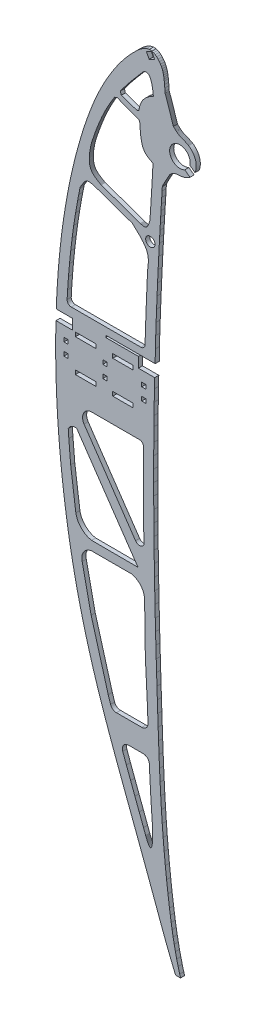
SolidWorks part; units mm, degrees
ref_plane "前视基准面" through (0, 0, 0) normal (0, 0, 1) x (1, 0, 0)
ref_plane "上视基准面" through (0, 0, 0) normal (0, 1, 0) x (1, 0, 0)
ref_plane "右视基准面" through (0, 0, 0) normal (1, 0, 0) x (0, 0, -1)
sketch "Model" plane through (0, 0, 0) normal (0, 0, 1) x (1, 0, 0)
  line L0 (61.9959, 382.2995) -> (59.2897, 381.0046)
  line L1 (60.5846, 378.2985) -> (63.2907, 379.5933)
  line L2 (15.0713, 224.1256) -> (15.0085, 226.845)
  line L3 (15.0085, 226.845) -> (14.949, 232.5408)
  line L4 (14.949, 232.5408) -> (14.9635, 238.2369)
  line L5 (15.2405, 250.0973) -> (15.466, 255.317)
  line L6 (15.466, 255.317) -> (15.7911, 261.0076)
  line L7 (15.7911, 261.0076) -> (16.2035, 266.7611)
  line L8 (16.2035, 266.7611) -> (16.7024, 272.5063)
  line L9 (16.7024, 272.5063) -> (17.2927, 278.2425)
  line L10 (17.2927, 278.2425) -> (17.9787, 283.9659)
  line L11 (17.9787, 283.9659) -> (18.7634, 289.6766)
  line L12 (18.7634, 289.6766) -> (19.6518, 295.3718)
  line L13 (19.6518, 295.3718) -> (20.6481, 301.0506)
  line L14 (20.6481, 301.0506) -> (21.1994, 303.9434)
  line L15 (21.1994, 303.9434) -> (21.781, 306.8305)
  line L16 (21.781, 306.8305) -> (22.391, 309.7109)
  line L17 (22.391, 309.7109) -> (23.0313, 312.5835)
  line L18 (23.0313, 312.5835) -> (23.7028, 315.4506)
  line L19 (23.7028, 315.4506) -> (24.4048, 318.3099)
  line L20 (24.4048, 318.3099) -> (25.1381, 321.1616)
  line L21 (25.1381, 321.1616) -> (25.9244, 324.0827)
  line L22 (25.9244, 324.0827) -> (26.7463, 326.9933)
  line L23 (26.7463, 326.9933) -> (27.6057, 329.8916)
  line L24 (27.6057, 329.8916) -> (28.5046, 332.7775)
  line L25 (28.5046, 332.7775) -> (29.4472, 335.6514)
  line L26 (29.4472, 335.6514) -> (30.4344, 338.5101)
  line L27 (30.4344, 338.5101) -> (31.4683, 341.3539)
  line L28 (31.4683, 341.3539) -> (32.0248, 342.8226)
  line L29 (32.0248, 342.8226) -> (32.5945, 344.2859)
  line L30 (32.5945, 344.2859) -> (33.1785, 345.7437)
  line L31 (33.1785, 345.7437) -> (33.7788, 347.1933)
  line L32 (33.7788, 347.1933) -> (34.3945, 348.6365)
  line L33 (34.3945, 348.6365) -> (35.0275, 350.0705)
  line L34 (35.0275, 350.0705) -> (35.677, 351.4952)
  line L35 (65.5673, 303.0118) -> (65.2646, 297.3112)
  line L36 (65.2646, 297.3112) -> (64.9779, 291.6123)
  line L37 (64.9779, 291.6123) -> (64.7073, 285.912)
  line L38 (64.7073, 285.912) -> (64.4527, 280.2125)
  line L39 (64.4527, 280.2125) -> (64.2161, 274.5118)
  line L40 (64.2161, 274.5118) -> (63.9967, 268.8088)
  line L41 (63.9967, 268.8088) -> (63.7954, 263.1036)
  line L42 (63.7954, 263.1036) -> (63.6136, 257.4072)
  line L43 (63.6136, 257.4072) -> (63.5328, 251.0973)
  line L44 (63.0707, 234.6288) -> (62.9811, 228.9325)
  line L45 (62.9811, 228.9325) -> (62.8953, 224.1253)
  line L46 (59.8461, 288.7617) -> (59.7073, 285.912)
  line L47 (59.7073, 285.912) -> (59.4527, 280.2125)
  line L48 (59.4527, 280.2125) -> (59.2161, 274.5118)
  line L49 (59.2161, 274.5118) -> (58.9967, 268.8088)
  line L50 (58.9967, 268.8088) -> (58.7954, 263.1036)
  line L51 (58.7954, 263.1036) -> (58.6136, 257.4072)
  line L52 (58.6136, 257.4072) -> (58.6223, 256.5398)
  line L53 (56.5895, 254.5973) -> (22.5424, 254.5973)
  line L54 (20.5456, 256.7113) -> (20.7911, 261.0076)
  line L55 (20.7911, 261.0076) -> (21.2035, 266.7611)
  line L56 (21.2035, 266.7611) -> (21.7024, 272.5063)
  line L57 (21.7024, 272.5063) -> (22.2927, 278.2425)
  line L58 (22.2927, 278.2425) -> (22.9787, 283.9659)
  line L59 (22.9787, 283.9659) -> (23.7634, 289.6766)
  line L60 (23.7634, 289.6766) -> (24.6518, 295.3718)
  line L61 (24.6518, 295.3718) -> (25.6481, 301.0506)
  line L62 (25.6481, 301.0506) -> (26.1994, 303.9434)
  line L63 (26.1994, 303.9434) -> (26.781, 306.8305)
  line L64 (26.781, 306.8305) -> (26.9461, 307.5007)
  line L65 (59.2897, 381.0046) -> (60.5846, 378.2985)
  line L66 (63.2907, 379.5933) -> (61.9959, 382.2995)
  line L67 (33.2961, 311.6207) -> (52.3061, 304.9277)
  line L68 (56.2961, 306.7947) -> (37.1861, 313.5247)
  line L69 (63.2846, 245.0973) -> (63.1784, 240.324)
  line L70 (14.9635, 238.2369) -> (15.0874, 245.0973)
  line L71 (63.1784, 240.324) -> (63.0707, 234.6288)
  line L72 (15.2405, 250.0973) -> (22.1906, 250.0973)
  line L73 (63.5328, 251.0973) -> (39.4088, 251.0973)
  line L74 (39.4088, 251.0973) -> (39.4088, 250.0973)
  line L75 (35.677, 351.4952) -> (36.3789, 352.9802)
  line L76 (36.3789, 352.9802) -> (37.1012, 354.4551)
  line L77 (37.1012, 354.4551) -> (37.8451, 355.919)
  line L78 (37.8451, 355.919) -> (38.6104, 357.3737)
  line L79 (38.6104, 357.3737) -> (39.4001, 358.8195)
  line L80 (39.4001, 358.8195) -> (40.2131, 360.2574)
  line L81 (40.2131, 360.2574) -> (41.0505, 361.6873)
  line L82 (41.0505, 361.6873) -> (41.9844, 363.2245)
  line L83 (41.9844, 363.2245) -> (42.9459, 364.7469)
  line L84 (42.9459, 364.7469) -> (43.9323, 366.2493)
  line L85 (43.9323, 366.2493) -> (44.9418, 367.7268)
  line L86 (44.9418, 367.7268) -> (45.9737, 369.1731)
  line L87 (45.9737, 369.1731) -> (47.0251, 370.5843)
  line L88 (47.0251, 370.5843) -> (48.0944, 371.9533)
  line L89 (48.0944, 371.9533) -> (48.7604, 372.7721)
  line L90 (48.7604, 372.7721) -> (49.4378, 373.5794)
  line L91 (49.4378, 373.5794) -> (50.1315, 374.3815)
  line L92 (50.1315, 374.3815) -> (50.8492, 375.1835)
  line L93 (50.8492, 375.1835) -> (51.5956, 375.9919)
  line L94 (51.5956, 375.9919) -> (52.3766, 376.8127)
  line L95 (52.3766, 376.8127) -> (53.1987, 377.6524)
  line L96 (53.1987, 377.6524) -> (54.3446, 378.7804)
  line L97 (54.3446, 378.7804) -> (55.5537, 379.8812)
  line L98 (55.5537, 379.8812) -> (56.8102, 380.884)
  line L99 (56.8102, 380.884) -> (58.099, 381.719)
  line L100 (58.099, 381.719) -> (59.4032, 382.3164)
  line L101 (59.4032, 382.3164) -> (60.7078, 382.6066)
  line L102 (60.7078, 382.6066) -> (61.9959, 382.5177)
  line L103 (61.9959, 382.5177) -> (62.7845, 382.2459)
  line L104 (62.7845, 382.2459) -> (63.5497, 381.8218)
  line L105 (63.5497, 381.8218) -> (64.2785, 381.2691)
  line L106 (64.2785, 381.2691) -> (64.9598, 380.6112)
  line L107 (64.9598, 380.6112) -> (65.5817, 379.8706)
  line L108 (65.5817, 379.8706) -> (66.1341, 379.0719)
  line L109 (66.1341, 379.0719) -> (66.6039, 378.2376)
  line L110 (66.6039, 378.2376) -> (66.9452, 377.4838)
  line L111 (66.9452, 377.4838) -> (67.2227, 376.7212)
  line L112 (67.2227, 376.7212) -> (67.4445, 375.9511)
  line L113 (67.4445, 375.9511) -> (67.6205, 375.1751)
  line L114 (67.6205, 375.1751) -> (67.7597, 374.3944)
  line L115 (67.7597, 374.3944) -> (67.873, 373.6096)
  line L116 (67.873, 373.6096) -> (67.9675, 372.821)
  line L117 (67.9675, 372.821) -> (68.1141, 371.412)
  line L118 (68.1141, 371.412) -> (68.2359, 369.998)
  line L119 (68.2359, 369.998) -> (68.3349, 368.58)
  line L120 (68.3349, 368.58) -> (68.3761, 367.8697)
  line L121 (67.0161, 327.7257) -> (66.9042, 325.8309)
  line L122 (66.9042, 325.8309) -> (66.7295, 322.9775)
  line L123 (66.7295, 322.9775) -> (66.5567, 320.1253)
  line L124 (66.5567, 320.1253) -> (66.385, 317.2731)
  line L125 (66.385, 317.2731) -> (66.2162, 314.422)
  line L126 (66.2162, 314.422) -> (66.0494, 311.57)
  line L127 (66.0494, 311.57) -> (65.8857, 308.7181)
  line L128 (65.8857, 308.7181) -> (65.7249, 305.8654)
  line L129 (65.7249, 305.8654) -> (65.5673, 303.0118)
  line L130 (46.986, 356.3364) -> (54.3995, 353.8577)
  line L131 (44.9672, 354.3342) -> (55.3459, 350.3925)
  line L132 (52.8171, 227.0287) -> (52.8171, 229.0287)
  line L133 (52.8171, 229.0287) -> (42.8171, 229.0287)
  line L134 (42.8171, 229.0287) -> (42.8171, 227.0287)
  line L135 (42.8171, 227.0287) -> (52.8171, 227.0287)
  line L136 (34.5839, 227.0287) -> (34.5839, 229.0287)
  line L137 (34.5839, 229.0287) -> (24.5839, 229.0287)
  line L138 (24.5839, 229.0287) -> (24.5839, 227.0287)
  line L139 (24.5839, 227.0287) -> (34.5839, 227.0287)
  line L140 (24.5839, 245.0287) -> (24.5839, 243.0287)
  line L141 (24.5839, 243.0287) -> (34.5839, 243.0287)
  line L142 (34.5839, 243.0287) -> (34.5839, 245.0287)
  line L143 (34.5839, 245.0287) -> (24.5839, 245.0287)
  line L144 (42.8171, 245.0287) -> (42.8171, 243.0287)
  line L145 (42.8171, 243.0287) -> (52.8171, 243.0287)
  line L146 (52.8171, 243.0287) -> (52.8171, 245.0287)
  line L147 (52.8171, 245.0287) -> (42.8171, 245.0287)
  line L148 (58.973, 238.0287) -> (58.973, 240.0287)
  line L149 (58.973, 240.0287) -> (56.973, 240.0287)
  line L150 (56.973, 240.0287) -> (56.973, 238.0287)
  line L151 (56.973, 238.0287) -> (58.973, 238.0287)
  line L152 (58.973, 234.0287) -> (58.973, 232.0287)
  line L153 (58.973, 232.0287) -> (56.973, 232.0287)
  line L154 (56.973, 232.0287) -> (56.973, 234.0287)
  line L155 (56.973, 234.0287) -> (58.973, 234.0287)
  line L156 (39.973, 238.0287) -> (39.973, 240.0287)
  line L157 (39.973, 240.0287) -> (37.973, 240.0287)
  line L158 (37.973, 240.0287) -> (37.973, 238.0287)
  line L159 (37.973, 238.0287) -> (39.973, 238.0287)
  line L160 (39.973, 234.0287) -> (39.973, 232.0287)
  line L161 (39.973, 232.0287) -> (37.973, 232.0287)
  line L162 (37.973, 232.0287) -> (37.973, 234.0287)
  line L163 (37.973, 234.0287) -> (39.973, 234.0287)
  line L164 (20.973, 238.0287) -> (20.973, 240.0287)
  line L165 (20.973, 240.0287) -> (18.973, 240.0287)
  line L166 (18.973, 240.0287) -> (18.973, 238.0287)
  line L167 (18.973, 238.0287) -> (20.973, 238.0287)
  line L168 (20.973, 234.0287) -> (20.973, 232.0287)
  line L169 (20.973, 232.0287) -> (18.973, 232.0287)
  line L170 (18.973, 232.0287) -> (18.973, 234.0287)
  line L171 (18.973, 234.0287) -> (20.973, 234.0287)
  line L172 (73.529, -2.4556) -> (72.9472, -1.1177)
  line L173 (72.9472, -1.1177) -> (71.7808, 1.6861)
  line L174 (71.7808, 1.6861) -> (70.638, 4.5009)
  line L175 (70.638, 4.5009) -> (69.5406, 7.2827)
  line L176 (69.5406, 7.2827) -> (68.4659, 10.0725)
  line L177 (68.4659, 10.0725) -> (67.4109, 12.8691)
  line L178 (67.4109, 12.8691) -> (66.3686, 15.6713)
  line L179 (66.3686, 15.6713) -> (65.3362, 18.4779)
  line L180 (65.3362, 18.4779) -> (63.2812, 24.0956)
  line L181 (63.2812, 24.0956) -> (61.2145, 29.7068)
  line L182 (61.2145, 29.7068) -> (59.1341, 35.3104)
  line L183 (59.1341, 35.3104) -> (57.0419, 40.9095)
  line L184 (57.0419, 40.9095) -> (54.9419, 46.5032)
  line L185 (54.9419, 46.5032) -> (52.8369, 52.0967)
  line L186 (52.8369, 52.0967) -> (50.7289, 57.6901)
  line L187 (50.7289, 57.6901) -> (48.6218, 63.2865)
  line L188 (48.6218, 63.2865) -> (46.5319, 68.8567)
  line L189 (46.5319, 68.8567) -> (44.4567, 74.4304)
  line L190 (44.4567, 74.4304) -> (42.4083, 80.0134)
  line L191 (42.4083, 80.0134) -> (40.3963, 85.608)
  line L192 (40.3963, 85.608) -> (38.4317, 91.2196)
  line L193 (38.4317, 91.2196) -> (36.5252, 96.8518)
  line L194 (36.5252, 96.8518) -> (34.6867, 102.509)
  line L195 (34.6867, 102.509) -> (32.9646, 108.0682)
  line L196 (32.9646, 108.0682) -> (31.3205, 113.6508)
  line L197 (31.3205, 113.6508) -> (29.7555, 119.2558)
  line L198 (29.7555, 119.2558) -> (28.2717, 124.8825)
  line L199 (28.2717, 124.8825) -> (26.869, 130.5297)
  line L200 (26.869, 130.5297) -> (25.5495, 136.1985)
  line L201 (25.5495, 136.1985) -> (24.3142, 141.887)
  line L202 (24.3142, 141.887) -> (23.1813, 147.5)
  line L203 (23.1813, 147.5) -> (22.1308, 153.1265)
  line L204 (22.1308, 153.1265) -> (21.1579, 158.7654)
  line L205 (21.1579, 158.7654) -> (20.2615, 164.4177)
  line L206 (20.2615, 164.4177) -> (19.4387, 170.0822)
  line L207 (19.4387, 170.0822) -> (18.6864, 175.7568)
  line L208 (18.6864, 175.7568) -> (18.0038, 181.4424)
  line L209 (18.0038, 181.4424) -> (17.3914, 187.1001)
  line L210 (17.3914, 187.1001) -> (16.8459, 192.7627)
  line L211 (16.8459, 192.7627) -> (16.3672, 198.4302)
  line L212 (16.3672, 198.4302) -> (15.9564, 204.1027)
  line L213 (15.9564, 204.1027) -> (15.6154, 209.7802)
  line L214 (15.6154, 209.7802) -> (15.3423, 215.4617)
  line L215 (15.3423, 215.4617) -> (15.1401, 221.1483)
  line L216 (15.1401, 221.1483) -> (15.0713, 224.1256)
  line L217 (62.8953, 224.1253) -> (62.8578, 217.5423)
  line L218 (62.8578, 217.5423) -> (62.822, 211.8523)
  line L219 (62.822, 211.8523) -> (62.8041, 206.1631)
  line L220 (62.8041, 206.1631) -> (62.8033, 200.4737)
  line L221 (62.8033, 200.4737) -> (62.8174, 194.7849)
  line L222 (62.8174, 194.7849) -> (62.8467, 189.0937)
  line L223 (62.8467, 189.0937) -> (62.891, 183.4023)
  line L224 (62.891, 183.4023) -> (62.9492, 177.7144)
  line L225 (62.9492, 177.7144) -> (63.0203, 172.0281)
  line L226 (63.0203, 172.0281) -> (63.1054, 166.3424)
  line L227 (63.1054, 166.3424) -> (63.2024, 160.6582)
  line L228 (63.2024, 160.6582) -> (63.3135, 154.9736)
  line L229 (63.3135, 154.9736) -> (63.4366, 149.2876)
  line L230 (63.4366, 149.2876) -> (63.5718, 143.6011)
  line L231 (63.5718, 143.6011) -> (63.7199, 137.9161)
  line L232 (63.7199, 137.9161) -> (63.8779, 132.2336)
  line L233 (63.8779, 132.2336) -> (64.0449, 126.5515)
  line L234 (64.0449, 126.5515) -> (64.2209, 120.8707)
  line L235 (64.2209, 120.8707) -> (64.4039, 115.1893)
  line L236 (64.4039, 115.1893) -> (64.5919, 109.5071)
  line L237 (64.5919, 109.5071) -> (64.786, 103.8232)
  line L238 (64.786, 103.8232) -> (64.9831, 98.1394)
  line L239 (64.9831, 98.1394) -> (65.1901, 92.458)
  line L240 (65.1901, 92.458) -> (65.4121, 86.7773)
  line L241 (65.4121, 86.7773) -> (65.656, 81.0995)
  line L242 (65.656, 81.0995) -> (65.9289, 75.422)
  line L243 (65.9289, 75.422) -> (66.2358, 69.746)
  line L244 (66.2358, 69.746) -> (66.5837, 64.0707)
  line L245 (66.5837, 64.0707) -> (66.9789, 58.3896)
  line L246 (66.9789, 58.3896) -> (67.4238, 52.7146)
  line L247 (67.4238, 52.7146) -> (67.9227, 47.0439)
  line L248 (67.9227, 47.0439) -> (68.4783, 41.3788)
  line L249 (68.4783, 41.3788) -> (69.0938, 35.7183)
  line L250 (69.0938, 35.7183) -> (69.7741, 30.0625)
  line L251 (69.7741, 30.0625) -> (70.5203, 24.4117)
  line L252 (70.5203, 24.4117) -> (70.9237, 21.5686)
  line L253 (70.9237, 21.5686) -> (71.35, 18.7295)
  line L254 (71.35, 18.7295) -> (71.805, 15.8966)
  line L255 (71.805, 15.8966) -> (72.2957, 13.0704)
  line L256 (72.2957, 13.0704) -> (72.8271, 10.2529)
  line L257 (72.8271, 10.2529) -> (73.4041, 7.4454)
  line L258 (73.4041, 7.4454) -> (74.0327, 4.6491)
  line L259 (74.0327, 4.6491) -> (74.7321, 1.8119)
  line L260 (74.7321, 1.8119) -> (75.481, -1.0121)
  line L261 (75.481, -1.0121) -> (75.916, -2.4556)
  line L262 (75.916, -2.4556) -> (73.529, -2.4556)
  line L263 (57.826, 213.1506) -> (57.8847, 211.7846)
  line L264 (58.8861, 49.2997) -> (57.8369, 52.0967)
  line L265 (57.8369, 52.0967) -> (55.7289, 57.6901)
  line L266 (55.7289, 57.6901) -> (53.6218, 63.2865)
  line L267 (53.6218, 63.2865) -> (51.5319, 68.8567)
  line L268 (51.5319, 68.8567) -> (49.4567, 74.4304)
  line L269 (49.4567, 74.4304) -> (47.6818, 79.2679)
  line L270 (50.4982, 83.3012) -> (57.6909, 83.3012)
  line L271 (60.6875, 80.4453) -> (60.9289, 75.422)
  line L272 (60.9289, 75.422) -> (61.2358, 69.746)
  line L273 (61.2358, 69.746) -> (61.5837, 64.0707)
  line L274 (61.5837, 64.0707) -> (61.7561, 61.2287)
  line L275 (32.27, 129.1295) -> (40.6059, 99.6804)
  line L276 (80.5342, 338.4062) -> (78.02, 340.3262)
  line L277 (82.9618, 341.5853) -> (80.4477, 343.5052)
  line L278 (23.1906, 245.0973) -> (23.1906, 250.0973)
  line L279 (23.1906, 250.0973) -> (22.1906, 250.0973)
  line L280 (39.4088, 250.0973) -> (55.3152, 250.0973)
  line L281 (32.4999, 156.4446) -> (51.9329, 156.4446)
  line L282 (58.3653, 148.9747) -> (58.7261, 124.8664)
  line L283 (57.8057, 199.511) -> (57.8174, 194.7849)
  line L284 (57.8174, 194.7849) -> (57.8467, 189.0937)
  line L285 (57.8467, 189.0937) -> (57.891, 183.4023)
  line L286 (57.891, 183.4023) -> (57.9492, 177.7144)
  line L287 (57.9492, 177.7144) -> (58.0231, 171.8053)
  line L288 (22.2731, 187.7045) -> (21.3672, 198.4302)
  line L289 (21.3672, 198.4302) -> (21.0747, 202.4693)
  line L290 (31.9943, 215.1569) -> (55.8261, 215.1569)
  line L291 (59.786, 103.8232) -> (60.0164, 97.1789)
  line L292 (57.0182, 94.0749) -> (44.6071, 94.0749)
  line L293 (41.754, 96.1477) -> (40.6059, 99.6804)
  line L294 (23.1906, 245.0973) -> (15.0874, 245.0973)
  line L295 (55.3152, 245.0973) -> (63.2846, 245.0973)
  line L296 (55.3152, 250.0973) -> (55.3152, 245.0973)
  line L297 (22.2731, 187.7045) -> (24.7884, 168.6912)
  line L298 (27.8832, 149.6382) -> (32.27, 129.1295)
  line L299 (58.7261, 124.8664) -> (59.786, 103.8232)
  line L300 (57.8057, 199.511) -> (57.8847, 211.7846)
  line L301 (32.4999, 160.8922) -> (55.1584, 160.8238)
  line L302 (55.1584, 160.8238) -> (25.1785, 204.6658)
  line L303 (53.9387, 171.4653) -> (28.8112, 208.2113)
  line L304 (46.4961, 357.8737) -> (46.986, 356.3364)
  line L305 (57.9061, 371.8437) -> (57.9561, 371.8707)
  line L306 (57.9561, 371.8707) -> (58.0061, 371.8977)
  line L307 (58.0061, 371.8977) -> (58.0561, 371.9237)
  line L308 (58.0561, 371.9237) -> (58.1061, 371.9477)
  line L309 (58.1061, 371.9477) -> (58.1561, 371.9717)
  line L310 (58.1561, 371.9717) -> (58.2061, 371.9947)
  line L311 (58.2061, 371.9947) -> (58.2561, 372.0157)
  line L312 (58.2561, 372.0157) -> (58.3061, 372.0367)
  line L313 (58.3061, 372.0367) -> (58.3461, 372.0567)
  line L314 (58.3461, 372.0567) -> (58.3961, 372.0747)
  line L315 (58.3961, 372.0747) -> (58.4461, 372.0927)
  line L316 (58.4461, 372.0927) -> (58.4961, 372.1097)
  line L317 (58.4961, 372.1097) -> (58.5361, 372.1247)
  line L318 (58.5361, 372.1247) -> (58.5861, 372.1397)
  line L319 (58.5861, 372.1397) -> (58.6361, 372.1527)
  line L320 (58.6361, 372.1527) -> (58.6761, 372.1657)
  line L321 (58.6761, 372.1657) -> (58.7261, 372.1777)
  line L322 (58.7261, 372.1777) -> (58.7661, 372.1877)
  line L323 (58.7661, 372.1877) -> (58.8161, 372.1977)
  line L324 (58.8161, 372.1977) -> (58.8561, 372.2057)
  line L325 (58.8561, 372.2057) -> (58.9061, 372.2137)
  line L326 (58.9061, 372.2137) -> (58.9461, 372.2197)
  line L327 (58.9461, 372.2197) -> (58.9961, 372.2247)
  line L328 (58.9961, 372.2247) -> (59.0361, 372.2297)
  line L329 (59.0361, 372.2297) -> (59.0761, 372.2327)
  line L330 (59.0761, 372.2327) -> (59.1261, 372.2347)
  line L331 (59.1261, 372.2347) -> (59.1661, 372.2357)
  line L332 (59.1661, 372.2357) -> (59.2061, 372.2357)
  line L333 (59.2061, 372.2357) -> (59.2561, 372.2347)
  line L334 (59.2561, 372.2347) -> (59.2961, 372.2327)
  line L335 (59.2961, 372.2327) -> (59.3361, 372.2297)
  line L336 (59.3361, 372.2297) -> (59.3761, 372.2257)
  line L337 (59.3761, 372.2257) -> (59.4161, 372.2207)
  line L338 (59.4161, 372.2207) -> (59.4561, 372.2137)
  line L339 (59.4561, 372.2137) -> (59.5061, 372.2067)
  line L340 (59.5061, 372.2067) -> (59.5461, 372.1987)
  line L341 (59.5461, 372.1987) -> (59.5861, 372.1887)
  line L342 (59.5861, 372.1887) -> (59.6261, 372.1787)
  line L343 (59.6261, 372.1787) -> (59.6661, 372.1667)
  line L344 (59.6661, 372.1667) -> (59.7061, 372.1537)
  line L345 (59.7061, 372.1537) -> (59.7461, 372.1407)
  line L346 (59.7461, 372.1407) -> (59.7761, 372.1257)
  line L347 (59.7761, 372.1257) -> (59.8161, 372.1097)
  line L348 (59.8161, 372.1097) -> (59.8561, 372.0927)
  line L349 (59.8561, 372.0927) -> (59.8961, 372.0747)
  line L350 (59.8961, 372.0747) -> (59.9361, 372.0557)
  line L351 (59.9361, 372.0557) -> (59.9761, 372.0357)
  line L352 (59.9761, 372.0357) -> (60.0061, 372.0147)
  line L353 (60.0061, 372.0147) -> (60.0461, 371.9927)
  line L354 (60.0461, 371.9927) -> (60.0861, 371.9697)
  line L355 (60.0861, 371.9697) -> (60.1161, 371.9457)
  line L356 (60.1161, 371.9457) -> (60.1561, 371.9207)
  line L357 (60.1561, 371.9207) -> (60.1961, 371.8937)
  line L358 (60.1961, 371.8937) -> (60.2261, 371.8667)
  line L359 (60.2261, 371.8667) -> (60.2661, 371.8387)
  line L360 (60.2661, 371.8387) -> (60.2961, 371.8097)
  line L361 (60.2961, 371.8097) -> (60.3361, 371.7787)
  line L362 (60.3361, 371.7787) -> (60.3661, 371.7477)
  line L363 (60.3661, 371.7477) -> (60.4061, 371.7147)
  line L364 (60.4061, 371.7147) -> (60.4361, 371.6817)
  line L365 (60.4361, 371.6817) -> (60.4661, 371.6477)
  line L366 (60.4661, 371.6477) -> (60.5061, 371.6117)
  line L367 (60.5061, 371.6117) -> (60.5361, 371.5757)
  line L368 (60.5361, 371.5757) -> (60.5661, 371.5387)
  line L369 (60.5661, 371.5387) -> (60.6061, 371.4997)
  line L370 (60.6061, 371.4997) -> (60.6361, 371.4607)
  line L371 (60.6361, 371.4607) -> (60.6661, 371.4197)
  line L372 (60.6661, 371.4197) -> (60.6961, 371.3787)
  line L373 (60.6961, 371.3787) -> (60.7361, 371.3357)
  line L374 (60.7361, 371.3357) -> (60.7661, 371.2927)
  line L375 (60.7661, 371.2927) -> (60.7961, 371.2487)
  line L376 (60.7961, 371.2487) -> (60.8261, 371.2027)
  line L377 (60.8261, 371.2027) -> (60.8561, 371.1567)
  line L378 (60.8561, 371.1567) -> (60.8861, 371.1087)
  line L379 (60.8861, 371.1087) -> (60.9161, 371.0607)
  line L380 (60.9161, 371.0607) -> (60.9461, 371.0117)
  line L381 (60.9461, 371.0117) -> (60.9761, 370.9607)
  line L382 (60.9761, 370.9607) -> (61.0061, 370.9097)
  line L383 (61.0061, 370.9097) -> (61.0361, 370.8577)
  line L384 (61.0361, 370.8577) -> (61.0661, 370.8047)
  line L385 (61.0661, 370.8047) -> (61.0961, 370.7497)
  line L386 (61.0961, 370.7497) -> (61.1261, 370.6947)
  line L387 (61.1261, 370.6947) -> (61.1561, 370.6387)
  line L388 (61.1561, 370.6387) -> (61.1861, 370.5817)
  line L389 (61.1861, 370.5817) -> (61.2061, 370.5237)
  line L390 (61.2061, 370.5237) -> (61.2361, 370.4647)
  line L391 (61.2361, 370.4647) -> (61.2661, 370.4047)
  line L392 (61.2661, 370.4047) -> (61.2961, 370.3437)
  line L393 (61.2961, 370.3437) -> (61.3161, 370.2817)
  line L394 (61.3161, 370.2817) -> (61.3461, 370.2187)
  line L395 (61.3461, 370.2187) -> (61.3761, 370.1547)
  line L396 (61.3761, 370.1547) -> (61.3961, 370.0907)
  line L397 (61.3961, 370.0907) -> (61.4261, 370.0247)
  line L398 (61.4261, 370.0247) -> (61.4461, 369.9577)
  line L399 (61.4461, 369.9577) -> (61.4761, 369.8907)
  line L400 (61.4761, 369.8907) -> (61.4961, 369.8217)
  line L401 (61.4961, 369.8217) -> (61.5261, 369.7527)
  line L402 (61.5261, 369.7527) -> (61.5461, 369.6817)
  line L403 (61.5461, 369.6817) -> (61.5761, 369.6107)
  line L404 (61.5761, 369.6107) -> (61.5961, 369.5377)
  line L405 (61.5961, 369.5377) -> (61.6261, 369.4647)
  line L406 (61.6261, 369.4647) -> (61.6461, 369.3907)
  line L407 (61.6461, 369.3907) -> (61.6661, 369.3157)
  line L408 (61.6661, 369.3157) -> (61.6961, 369.2397)
  line L409 (61.6961, 369.2397) -> (61.7161, 369.1627)
  line L410 (61.7161, 369.1627) -> (61.7361, 369.0847)
  line L411 (61.7361, 369.0847) -> (61.7661, 369.0067)
  line L412 (61.7661, 369.0067) -> (61.7861, 368.9267)
  line L413 (61.7861, 368.9267) -> (61.8061, 368.8457)
  line L414 (61.8061, 368.8457) -> (61.8261, 368.7647)
  line L415 (61.8261, 368.7647) -> (61.8561, 368.6817)
  line L416 (61.8561, 368.6817) -> (61.8761, 368.5987)
  line L417 (61.8761, 368.5987) -> (61.8961, 368.5147)
  line L418 (61.8961, 368.5147) -> (61.9161, 368.4297)
  line L419 (61.9161, 368.4297) -> (61.9361, 368.3437)
  line L420 (61.9361, 368.3437) -> (61.9561, 368.2567)
  line L421 (61.9561, 368.2567) -> (61.9761, 368.1687)
  line L422 (61.9761, 368.1687) -> (61.9961, 368.0797)
  line L423 (61.9961, 368.0797) -> (62.0161, 367.9907)
  line L424 (62.0161, 367.9907) -> (62.0361, 367.8997)
  line L425 (62.0361, 367.8997) -> (62.0561, 367.8087)
  line L426 (62.0561, 367.8087) -> (62.0761, 367.7167)
  line L427 (62.0761, 367.7167) -> (62.0961, 367.6227)
  line L428 (62.0961, 367.6227) -> (62.1161, 367.5287)
  line L429 (62.1161, 367.5287) -> (62.1361, 367.4337)
  line L430 (62.1361, 367.4337) -> (62.1561, 367.3387)
  line L431 (62.1561, 367.3387) -> (62.1661, 367.2417)
  line L432 (62.1661, 367.2417) -> (62.1861, 367.1437)
  line L433 (62.1861, 367.1437) -> (62.2061, 367.0457)
  line L434 (62.2061, 367.0457) -> (62.2261, 366.9467)
  line L435 (62.2261, 366.9467) -> (62.2461, 366.8467)
  line L436 (62.2461, 366.8467) -> (62.2561, 366.7457)
  line L437 (62.2561, 366.7457) -> (62.2761, 366.6437)
  line L438 (62.2761, 366.6437) -> (62.2961, 366.5407)
  line L439 (62.2961, 366.5407) -> (62.3061, 366.4367)
  line L440 (62.3061, 366.4367) -> (62.3261, 366.3327)
  line L441 (62.3261, 366.3327) -> (62.3461, 366.2277)
  line L442 (62.3461, 366.2277) -> (62.3561, 366.1207)
  line L443 (62.3561, 366.1207) -> (62.3761, 366.0137)
  line L444 (62.3761, 366.0137) -> (62.3861, 365.9067)
  line L445 (62.3861, 365.9067) -> (62.4061, 365.7977)
  line L446 (62.4061, 365.7977) -> (62.4161, 365.6877)
  line L447 (62.4161, 365.6877) -> (62.4361, 365.5777)
  line L448 (62.4361, 365.5777) -> (62.4461, 365.4667)
  line L449 (62.4461, 365.4667) -> (62.4661, 365.3547)
  line L450 (62.4661, 365.3547) -> (62.4761, 365.2417)
  line L451 (62.4761, 365.2417) -> (62.4961, 365.1277)
  line L452 (62.4961, 365.1277) -> (62.5061, 365.0127)
  line L453 (62.5061, 365.0127) -> (62.5161, 364.8977)
  line L454 (62.5161, 364.8977) -> (62.5361, 364.7817)
  line L455 (62.5361, 364.7817) -> (62.5461, 364.6637)
  line L456 (62.5461, 364.6637) -> (62.5561, 364.5467)
  line L457 (62.5561, 364.5467) -> (62.5761, 364.4277)
  line L458 (62.5761, 364.4277) -> (62.5861, 364.3077)
  line L459 (62.5861, 364.3077) -> (62.5961, 364.1877)
  line L460 (62.5961, 364.1877) -> (62.6061, 364.0667)
  line L461 (62.6061, 364.0667) -> (62.6261, 363.9447)
  line L462 (62.6261, 363.9447) -> (62.6361, 363.8217)
  line L463 (62.6361, 363.8217) -> (62.6461, 363.6977)
  line L464 (62.4661, 335.3737) -> (62.4561, 335.1937)
  line L465 (62.4561, 335.1937) -> (62.4461, 335.0147)
  line L466 (62.4461, 335.0147) -> (62.4361, 334.8347)
  line L467 (62.4361, 334.8347) -> (62.4361, 334.6537)
  line L468 (62.4361, 334.6537) -> (62.4261, 334.4737)
  line L469 (62.4261, 334.4737) -> (62.4161, 334.2927)
  line L470 (62.4161, 334.2927) -> (62.4061, 334.1117)
  line L471 (62.4061, 334.1117) -> (62.3961, 333.9297)
  line L472 (62.3961, 333.9297) -> (62.3861, 333.7477)
  line L473 (62.3861, 333.7477) -> (62.3761, 333.5657)
  line L474 (62.3761, 333.5657) -> (62.3661, 333.3837)
  line L475 (62.3661, 333.3837) -> (62.3561, 333.2007)
  line L476 (62.3561, 333.2007) -> (62.3461, 333.0187)
  line L477 (62.3461, 333.0187) -> (62.3361, 332.8347)
  line L478 (62.3361, 332.8347) -> (62.3261, 332.6517)
  line L479 (62.3261, 332.6517) -> (62.3161, 332.4677)
  line L480 (62.3161, 332.4677) -> (62.3061, 332.2837)
  line L481 (62.3061, 332.2837) -> (62.2961, 332.0997)
  line L482 (62.2961, 332.0997) -> (62.2861, 331.9147)
  line L483 (62.2861, 331.9147) -> (62.2761, 331.7297)
  line L484 (62.2761, 331.7297) -> (62.2661, 331.5447)
  line L485 (62.2661, 331.5447) -> (62.2561, 331.3587)
  line L486 (62.2561, 331.3587) -> (62.2461, 331.1737)
  line L487 (62.2461, 331.1737) -> (62.2361, 330.9877)
  line L488 (62.2361, 330.9877) -> (62.2261, 330.8007)
  line L489 (62.2261, 330.8007) -> (62.2161, 330.6147)
  line L490 (62.2161, 330.6147) -> (62.2061, 330.4277)
  line L491 (62.2061, 330.4277) -> (62.1961, 330.2407)
  line L492 (62.1961, 330.2407) -> (62.1861, 330.0527)
  line L493 (62.1861, 330.0527) -> (62.1761, 329.8657)
  line L494 (62.1761, 329.8657) -> (62.1661, 329.6777)
  line L495 (62.1661, 329.6777) -> (62.1561, 329.4887)
  line L496 (62.1561, 329.4887) -> (62.1461, 329.3007)
  line L497 (62.1461, 329.3007) -> (62.1361, 329.1117)
  line L498 (62.1361, 329.1117) -> (62.1261, 328.9227)
  line L499 (62.1261, 328.9227) -> (62.1161, 328.7337)
  line L500 (62.1161, 328.7337) -> (62.1061, 328.5437)
  line L501 (62.1061, 328.5437) -> (62.0961, 328.3537)
  line L502 (62.0961, 328.3537) -> (62.0761, 328.1637)
  line L503 (62.0761, 328.1637) -> (62.0661, 327.9737)
  line L504 (62.0661, 327.9737) -> (62.0561, 327.7827)
  line L505 (62.0561, 327.7827) -> (62.0461, 327.5917)
  line L506 (62.0461, 327.5917) -> (62.0361, 327.4007)
  line L507 (62.0361, 327.4007) -> (62.0261, 327.2097)
  line L508 (62.0261, 327.2097) -> (62.0161, 327.0177)
  line L509 (62.0161, 327.0177) -> (62.0061, 326.8257)
  line L510 (62.0061, 326.8257) -> (61.9961, 326.6337)
  line L511 (61.9961, 326.6337) -> (61.9761, 326.4417)
  line L512 (61.9761, 326.4417) -> (61.9661, 326.2487)
  line L513 (61.9661, 326.2487) -> (61.9561, 326.0557)
  line L514 (61.9561, 326.0557) -> (61.9461, 325.8627)
  line L515 (61.9461, 325.8627) -> (61.9361, 325.6697)
  line L516 (61.9361, 325.6697) -> (61.9261, 325.4757)
  line L517 (61.9261, 325.4757) -> (61.9161, 325.2817)
  line L518 (61.9161, 325.2817) -> (61.8961, 325.0877)
  line L519 (61.8961, 325.0877) -> (61.8861, 324.8927)
  line L520 (61.8861, 324.8927) -> (61.8761, 324.6987)
  line L521 (61.8761, 324.6987) -> (61.8661, 324.5037)
  line L522 (61.8661, 324.5037) -> (61.8561, 324.3087)
  line L523 (61.8561, 324.3087) -> (61.8461, 324.1127)
  line L524 (61.8461, 324.1127) -> (61.8261, 323.9177)
  line L525 (61.8261, 323.9177) -> (61.8161, 323.7217)
  line L526 (61.8161, 323.7217) -> (61.8061, 323.5257)
  line L527 (61.8061, 323.5257) -> (61.7961, 323.3287)
  line L528 (61.7961, 323.3287) -> (61.7861, 323.1327)
  line L529 (61.7861, 323.1327) -> (61.7661, 322.9357)
  line L530 (61.7661, 322.9357) -> (61.7561, 322.7387)
  line L531 (61.7561, 322.7387) -> (61.7461, 322.5417)
  line L532 (61.7461, 322.5417) -> (61.7361, 322.3437)
  line L533 (61.7361, 322.3437) -> (61.7261, 322.1457)
  line L534 (61.7261, 322.1457) -> (61.7061, 321.9477)
  line L535 (61.7061, 321.9477) -> (61.6961, 321.7497)
  line L536 (61.6961, 321.7497) -> (61.6861, 321.5517)
  line L537 (61.6861, 321.5517) -> (61.6761, 321.3527)
  line L538 (61.6761, 321.3527) -> (61.6561, 321.1537)
  line L539 (61.6561, 321.1537) -> (61.6461, 320.9547)
  line L540 (61.6461, 320.9547) -> (61.6361, 320.7557)
  line L541 (61.6361, 320.7557) -> (61.6261, 320.5557)
  line L542 (61.6261, 320.5557) -> (61.6161, 320.3567)
  line L543 (61.6161, 320.3567) -> (61.5961, 320.1567)
  line L544 (61.5961, 320.1567) -> (61.5861, 319.9557)
  line L545 (61.5861, 319.9557) -> (61.5761, 319.7557)
  line L546 (61.5761, 319.7557) -> (61.5661, 319.5547)
  line L547 (61.5661, 319.5547) -> (61.5461, 319.3547)
  line L548 (61.5461, 319.3547) -> (61.5361, 319.1527)
  line L549 (61.5361, 319.1527) -> (61.5261, 318.9517)
  line L550 (61.5261, 318.9517) -> (61.5061, 318.7507)
  line L551 (61.5061, 318.7507) -> (61.4961, 318.5487)
  line L552 (61.4961, 318.5487) -> (61.4861, 318.3467)
  line L553 (61.4861, 318.3467) -> (61.4761, 318.1447)
  line L554 (61.4761, 318.1447) -> (61.4561, 317.9427)
  line L555 (61.4561, 317.9427) -> (61.4461, 317.7397)
  line L556 (61.4461, 317.7397) -> (61.4361, 317.5367)
  line L557 (61.4361, 317.5367) -> (61.4161, 317.3337)
  line L558 (61.4161, 317.3337) -> (61.4061, 317.1307)
  line L559 (61.4061, 317.1307) -> (61.3961, 316.9277)
  line L560 (61.3961, 316.9277) -> (61.3861, 316.7237)
  line L561 (61.3861, 316.7237) -> (61.3661, 316.5197)
  line L562 (61.3661, 316.5197) -> (61.3561, 316.3157)
  line L563 (61.3561, 316.3157) -> (61.3461, 316.1117)
  line L564 (61.3461, 316.1117) -> (61.3261, 315.9077)
  line L565 (61.3261, 315.9077) -> (61.3161, 315.7027)
  line L566 (61.3161, 315.7027) -> (61.3061, 315.4987)
  line L567 (61.3061, 315.4987) -> (61.2861, 315.2937)
  line L568 (61.2861, 315.2937) -> (61.2761, 315.0877)
  line L569 (61.2761, 315.0877) -> (61.2661, 314.8827)
  line L570 (61.2661, 314.8827) -> (61.2461, 314.6767)
  line L571 (61.2461, 314.6767) -> (61.2361, 314.4717)
  line L572 (61.2361, 314.4717) -> (61.2261, 314.2657)
  line L573 (61.2261, 314.2657) -> (61.2061, 314.0597)
  line L574 (61.2061, 314.0597) -> (61.1961, 313.8527)
  line L575 (61.1961, 313.8527) -> (61.1861, 313.6467)
  line L576 (61.1861, 313.6467) -> (61.1661, 313.4397)
  line L577 (61.1661, 313.4397) -> (61.1561, 313.2327)
  line L578 (61.1561, 313.2327) -> (61.1461, 313.0257)
  line L579 (61.1461, 313.0257) -> (61.1261, 312.8187)
  line L580 (61.1261, 312.8187) -> (61.1161, 312.6117)
  line L581 (61.1161, 312.6117) -> (61.1061, 312.4037)
  line L582 (61.1061, 312.4037) -> (61.0861, 312.1957)
  line L583 (61.0861, 312.1957) -> (61.0761, 311.9877)
  line L584 (61.0761, 311.9877) -> (61.0661, 311.7797)
  line L585 (61.0661, 311.7797) -> (61.0461, 311.5717)
  line L586 (61.0461, 311.5717) -> (61.0361, 311.3627)
  line L587 (61.0361, 311.3627) -> (61.0261, 311.1547)
  line L588 (61.0261, 311.1547) -> (61.0061, 310.9457)
  line L589 (61.0061, 310.9457) -> (60.9961, 310.7367)
  line L590 (60.9961, 310.7367) -> (60.9761, 310.5277)
  line L591 (32.3561, 328.6427) -> (32.4061, 328.7817)
  line L592 (32.4061, 328.7817) -> (32.4461, 328.9207)
  line L593 (32.4461, 328.9207) -> (32.4961, 329.0597)
  line L594 (32.4961, 329.0597) -> (32.5361, 329.1987)
  line L595 (32.5361, 329.1987) -> (32.5861, 329.3377)
  line L596 (32.5861, 329.3377) -> (32.6261, 329.4767)
  line L597 (32.6261, 329.4767) -> (32.6761, 329.6157)
  line L598 (32.6761, 329.6157) -> (32.7161, 329.7547)
  line L599 (32.7161, 329.7547) -> (32.7661, 329.8937)
  line L600 (32.7661, 329.8937) -> (32.8061, 330.0317)
  line L601 (32.8061, 330.0317) -> (32.8561, 330.1707)
  line L602 (32.8561, 330.1707) -> (32.8961, 330.3097)
  line L603 (32.8961, 330.3097) -> (32.9461, 330.4487)
  line L604 (32.9461, 330.4487) -> (32.9861, 330.5867)
  line L605 (32.9861, 330.5867) -> (33.0361, 330.7257)
  line L606 (33.0361, 330.7257) -> (33.0861, 330.8647)
  line L607 (33.0861, 330.8647) -> (33.1261, 331.0027)
  line L608 (33.1261, 331.0027) -> (33.1761, 331.1417)
  line L609 (33.1761, 331.1417) -> (33.2161, 331.2797)
  line L610 (33.2161, 331.2797) -> (33.2661, 331.4187)
  line L611 (33.2661, 331.4187) -> (33.3161, 331.5567)
  line L612 (33.3161, 331.5567) -> (33.3561, 331.6957)
  line L613 (33.3561, 331.6957) -> (33.4061, 331.8337)
  line L614 (33.4061, 331.8337) -> (33.4561, 331.9727)
  line L615 (33.4561, 331.9727) -> (33.4961, 332.1107)
  line L616 (33.4961, 332.1107) -> (33.5461, 332.2487)
  line L617 (33.5461, 332.2487) -> (33.5961, 332.3877)
  line L618 (33.5961, 332.3877) -> (33.6461, 332.5257)
  line L619 (33.6461, 332.5257) -> (33.6861, 332.6637)
  line L620 (33.6861, 332.6637) -> (33.7361, 332.8017)
  line L621 (33.7361, 332.8017) -> (33.7861, 332.9407)
  line L622 (33.7861, 332.9407) -> (33.8361, 333.0787)
  line L623 (33.8361, 333.0787) -> (33.8761, 333.2167)
  line L624 (33.8761, 333.2167) -> (33.9261, 333.3547)
  line L625 (33.9261, 333.3547) -> (33.9761, 333.4927)
  line L626 (33.9761, 333.4927) -> (34.0261, 333.6307)
  line L627 (34.0261, 333.6307) -> (34.0761, 333.7687)
  line L628 (34.0761, 333.7687) -> (34.1261, 333.9067)
  line L629 (34.1261, 333.9067) -> (34.1761, 334.0447)
  line L630 (34.1761, 334.0447) -> (34.2161, 334.1817)
  line L631 (34.2161, 334.1817) -> (34.2661, 334.3197)
  line L632 (34.2661, 334.3197) -> (34.3161, 334.4577)
  line L633 (34.3161, 334.4577) -> (34.3661, 334.5957)
  line L634 (34.3661, 334.5957) -> (34.4161, 334.7327)
  line L635 (34.4161, 334.7327) -> (34.4661, 334.8707)
  line L636 (34.4661, 334.8707) -> (34.5161, 335.0077)
  line L637 (34.5161, 335.0077) -> (34.5661, 335.1457)
  line L638 (34.5661, 335.1457) -> (34.6161, 335.2827)
  line L639 (34.6161, 335.2827) -> (34.6661, 335.4207)
  line L640 (34.6661, 335.4207) -> (34.7161, 335.5577)
  line L641 (34.7161, 335.5577) -> (34.7761, 335.6947)
  line L642 (34.7761, 335.6947) -> (34.8261, 335.8317)
  line L643 (34.8261, 335.8317) -> (34.8761, 335.9697)
  line L644 (34.8761, 335.9697) -> (34.9261, 336.1067)
  line L645 (34.9261, 336.1067) -> (34.9761, 336.2437)
  line L646 (34.9761, 336.2437) -> (35.0261, 336.3807)
  line L647 (35.0261, 336.3807) -> (35.0761, 336.5177)
  line L648 (35.0761, 336.5177) -> (35.1361, 336.6547)
  line L649 (35.1361, 336.6547) -> (35.1861, 336.7917)
  line L650 (35.1861, 336.7917) -> (35.2361, 336.9277)
  line L651 (35.2361, 336.9277) -> (35.2861, 337.0647)
  line L652 (35.2861, 337.0647) -> (35.3461, 337.2017)
  line L653 (35.3461, 337.2017) -> (35.3961, 337.3377)
  line L654 (35.3961, 337.3377) -> (35.4461, 337.4747)
  line L655 (35.4461, 337.4747) -> (35.4961, 337.6107)
  line L656 (35.4961, 337.6107) -> (35.5561, 337.7477)
  line L657 (35.5561, 337.7477) -> (35.6061, 337.8837)
  line L658 (35.6061, 337.8837) -> (35.6661, 338.0197)
  line L659 (35.6661, 338.0197) -> (35.7161, 338.1567)
  line L660 (35.7161, 338.1567) -> (35.7661, 338.2927)
  line L661 (35.7661, 338.2927) -> (35.8261, 338.4287)
  line L662 (35.8261, 338.4287) -> (35.8761, 338.5647)
  line L663 (35.8761, 338.5647) -> (35.9361, 338.7007)
  line L664 (35.9361, 338.7007) -> (35.9861, 338.8367)
  line L665 (35.9861, 338.8367) -> (36.0461, 338.9717)
  line L666 (36.0461, 338.9717) -> (36.0961, 339.1077)
  line L667 (36.0961, 339.1077) -> (36.1561, 339.2437)
  line L668 (36.1561, 339.2437) -> (36.2061, 339.3787)
  line L669 (36.2061, 339.3787) -> (36.2661, 339.5147)
  line L670 (36.2661, 339.5147) -> (36.3161, 339.6497)
  line L671 (36.3161, 339.6497) -> (36.3761, 339.7857)
  line L672 (36.3761, 339.7857) -> (36.4361, 339.9207)
  line L673 (36.4361, 339.9207) -> (36.4861, 340.0557)
  line L674 (36.4861, 340.0557) -> (36.5461, 340.1907)
  line L675 (36.5461, 340.1907) -> (36.6061, 340.3257)
  line L676 (36.6061, 340.3257) -> (36.6561, 340.4607)
  line L677 (36.6561, 340.4607) -> (36.7161, 340.5957)
  line L678 (36.7161, 340.5957) -> (36.7761, 340.7307)
  line L679 (36.7761, 340.7307) -> (36.8361, 340.8647)
  line L680 (36.8361, 340.8647) -> (36.8861, 340.9997)
  line L681 (36.8861, 340.9997) -> (36.9461, 341.1347)
  line L682 (36.9461, 341.1347) -> (37.0061, 341.2687)
  line L683 (37.0061, 341.2687) -> (37.0661, 341.4027)
  line L684 (37.0661, 341.4027) -> (37.1261, 341.5367)
  line L685 (37.1261, 341.5367) -> (37.1861, 341.6717)
  line L686 (37.1861, 341.6717) -> (37.2361, 341.8057)
  line L687 (37.2361, 341.8057) -> (37.2961, 341.9397)
  line L688 (37.2961, 341.9397) -> (37.3561, 342.0737)
  line L689 (37.3561, 342.0737) -> (37.4161, 342.2067)
  line L690 (37.4161, 342.2067) -> (37.4761, 342.3407)
  line L691 (37.4761, 342.3407) -> (37.5361, 342.4747)
  line L692 (37.5361, 342.4747) -> (37.5961, 342.6077)
  line L693 (37.5961, 342.6077) -> (37.6561, 342.7407)
  line L694 (37.6561, 342.7407) -> (37.7161, 342.8747)
  line L695 (37.7161, 342.8747) -> (37.7761, 343.0077)
  line L696 (37.7761, 343.0077) -> (37.8361, 343.1407)
  line L697 (37.8361, 343.1407) -> (37.8961, 343.2737)
  line L698 (37.8961, 343.2737) -> (37.9661, 343.4067)
  line L699 (37.9661, 343.4067) -> (38.0261, 343.5397)
  line L700 (38.0261, 343.5397) -> (38.0861, 343.6717)
  line L701 (38.0861, 343.6717) -> (38.1461, 343.8047)
  line L702 (38.1461, 343.8047) -> (38.2061, 343.9367)
  line L703 (38.2061, 343.9367) -> (38.2761, 344.0697)
  line L704 (38.2761, 344.0697) -> (38.3361, 344.2017)
  line L705 (38.3361, 344.2017) -> (38.3961, 344.3337)
  line L706 (38.3961, 344.3337) -> (38.4561, 344.4657)
  line L707 (38.4561, 344.4657) -> (38.5261, 344.5977)
  line L708 (38.5261, 344.5977) -> (38.5861, 344.7297)
  line L709 (38.5861, 344.7297) -> (38.6461, 344.8617)
  line L710 (38.6461, 344.8617) -> (38.7161, 344.9927)
  line L711 (38.7161, 344.9927) -> (38.7761, 345.1247)
  line L712 (38.7761, 345.1247) -> (38.8461, 345.2557)
  line L713 (38.8461, 345.2557) -> (38.9061, 345.3867)
  line L714 (38.9061, 345.3867) -> (38.9661, 345.5187)
  line L715 (38.9661, 345.5187) -> (39.0361, 345.6497)
  line L716 (39.0361, 345.6497) -> (39.0961, 345.7807)
  line L717 (39.0961, 345.7807) -> (39.1661, 345.9107)
  line L718 (39.1661, 345.9107) -> (39.2261, 346.0417)
  line L719 (39.2261, 346.0417) -> (39.2961, 346.1727)
  line L720 (39.2961, 346.1727) -> (39.3661, 346.3027)
  line L721 (39.3661, 346.3027) -> (39.4261, 346.4327)
  line L722 (39.4261, 346.4327) -> (39.4961, 346.5627)
  line L723 (39.4961, 346.5627) -> (39.5661, 346.6927)
  line L724 (39.5661, 346.6927) -> (39.6261, 346.8227)
  line L725 (39.6261, 346.8227) -> (39.6961, 346.9527)
  line L726 (39.6961, 346.9527) -> (39.7661, 347.0827)
  line L727 (39.7661, 347.0827) -> (39.8261, 347.2117)
  line L728 (39.8261, 347.2117) -> (39.8961, 347.3417)
  line L729 (39.8961, 347.3417) -> (39.9661, 347.4707)
  line L730 (39.9661, 347.4707) -> (40.0361, 347.5997)
  line L731 (40.0361, 347.5997) -> (40.1061, 347.7287)
  line L732 (40.1061, 347.7287) -> (40.1661, 347.8577)
  line L733 (40.1661, 347.8577) -> (40.2361, 347.9867)
  line L734 (40.2361, 347.9867) -> (40.3061, 348.1157)
  line L735 (40.3061, 348.1157) -> (40.3761, 348.2437)
  line L736 (40.3761, 348.2437) -> (40.4461, 348.3717)
  line L737 (40.4461, 348.3717) -> (40.5161, 348.5007)
  line L738 (40.5161, 348.5007) -> (40.5861, 348.6287)
  line L739 (40.5861, 348.6287) -> (40.6561, 348.7567)
  line L740 (40.6561, 348.7567) -> (40.7261, 348.8837)
  line L741 (40.7261, 348.8837) -> (40.7961, 349.0117)
  line L742 (40.7961, 349.0117) -> (40.8661, 349.1397)
  line L743 (40.8661, 349.1397) -> (40.9361, 349.2667)
  line L744 (40.9361, 349.2667) -> (41.0061, 349.3937)
  line L745 (41.0061, 349.3937) -> (41.0761, 349.5207)
  line L746 (41.0761, 349.5207) -> (41.1561, 349.6477)
  line L747 (41.1561, 349.6477) -> (41.2261, 349.7747)
  line L748 (41.2261, 349.7747) -> (41.2961, 349.9017)
  line L749 (41.2961, 349.9017) -> (41.3661, 350.0277)
  line L750 (41.3661, 350.0277) -> (41.4461, 350.1547)
  line L751 (41.4461, 350.1547) -> (41.5161, 350.2807)
  line L752 (41.5161, 350.2807) -> (41.5861, 350.4067)
  line L753 (41.5861, 350.4067) -> (41.6561, 350.5327)
  line L754 (41.6561, 350.5327) -> (41.7361, 350.6587)
  line L755 (41.7361, 350.6587) -> (41.8061, 350.7837)
  line L756 (41.8061, 350.7837) -> (41.8861, 350.9097)
  line L757 (41.8861, 350.9097) -> (41.9561, 351.0347)
  line L758 (41.9561, 351.0347) -> (42.0261, 351.1597)
  line L759 (42.0261, 351.1597) -> (42.1061, 351.2847)
  line L760 (42.1061, 351.2847) -> (42.1761, 351.4097)
  line L761 (42.1761, 351.4097) -> (42.2561, 351.5347)
  line L762 (42.2561, 351.5347) -> (42.3361, 351.6587)
  line L763 (42.3361, 351.6587) -> (42.4061, 351.7837)
  line L764 (42.4061, 351.7837) -> (42.4861, 351.9077)
  line L765 (42.4861, 351.9077) -> (42.5561, 352.0317)
  line L766 (42.5561, 352.0317) -> (42.6361, 352.1557)
  line L767 (42.6361, 352.1557) -> (42.7161, 352.2797)
  line L768 (42.7161, 352.2797) -> (42.7861, 352.4027)
  line L769 (42.7861, 352.4027) -> (42.8661, 352.5267)
  line L770 (42.8661, 352.5267) -> (42.9461, 352.6497)
  line L771 (42.9461, 352.6497) -> (43.0161, 352.7727)
  line L772 (43.0161, 352.7727) -> (43.0961, 352.8957)
  line L773 (43.0961, 352.8957) -> (43.1761, 353.0187)
  line L774 (43.1761, 353.0187) -> (43.2561, 353.1417)
  line L775 (43.2561, 353.1417) -> (43.3361, 353.2647)
  line L776 (43.3361, 353.2647) -> (43.4161, 353.3867)
  line L777 (43.4161, 353.3867) -> (43.4861, 353.5087)
  line L778 (43.4861, 353.5087) -> (43.5661, 353.6317)
  line L779 (43.5661, 353.6317) -> (43.6461, 353.7537)
  line L780 (43.6461, 353.7537) -> (43.7261, 353.8757)
  line L781 (43.7261, 353.8757) -> (44.9672, 354.3342)
  line L782 (46.4961, 357.8737) -> (46.5761, 357.9877)
  line L783 (46.5761, 357.9877) -> (46.6661, 358.1017)
  line L784 (46.6661, 358.1017) -> (46.7461, 358.2157)
  line L785 (46.7461, 358.2157) -> (46.8261, 358.3297)
  line L786 (46.8261, 358.3297) -> (46.9161, 358.4437)
  line L787 (46.9161, 358.4437) -> (46.9961, 358.5577)
  line L788 (46.9961, 358.5577) -> (47.0861, 358.6717)
  line L789 (47.0861, 358.6717) -> (47.1661, 358.7847)
  line L790 (47.1661, 358.7847) -> (47.2461, 358.8987)
  line L791 (47.2461, 358.8987) -> (47.3361, 359.0117)
  line L792 (47.3361, 359.0117) -> (47.4161, 359.1247)
  line L793 (47.4161, 359.1247) -> (47.5061, 359.2377)
  line L794 (47.5061, 359.2377) -> (47.5861, 359.3507)
  line L795 (47.5861, 359.3507) -> (47.6761, 359.4637)
  line L796 (47.6761, 359.4637) -> (47.7661, 359.5767)
  line L797 (47.7661, 359.5767) -> (47.8461, 359.6897)
  line L798 (47.8461, 359.6897) -> (47.9361, 359.8027)
  line L799 (47.9361, 359.8027) -> (48.0161, 359.9147)
  line L800 (48.0161, 359.9147) -> (48.1061, 360.0277)
  line L801 (48.1061, 360.0277) -> (48.1861, 360.1397)
  line L802 (48.1861, 360.1397) -> (48.2761, 360.2527)
  line L803 (48.2761, 360.2527) -> (48.3661, 360.3647)
  line L804 (48.3661, 360.3647) -> (48.4461, 360.4767)
  line L805 (48.4461, 360.4767) -> (48.5361, 360.5887)
  line L806 (48.5361, 360.5887) -> (48.6261, 360.7007)
  line L807 (48.6261, 360.7007) -> (48.7061, 360.8127)
  line L808 (48.7061, 360.8127) -> (48.7961, 360.9247)
  line L809 (48.7961, 360.9247) -> (48.8861, 361.0367)
  line L810 (48.8861, 361.0367) -> (48.9661, 361.1487)
  line L811 (48.9661, 361.1487) -> (49.0561, 361.2597)
  line L812 (49.0561, 361.2597) -> (49.1461, 361.3717)
  line L813 (49.1461, 361.3717) -> (49.2361, 361.4827)
  line L814 (49.2361, 361.4827) -> (49.3161, 361.5947)
  line L815 (49.3161, 361.5947) -> (49.4061, 361.7057)
  line L816 (49.4061, 361.7057) -> (49.4961, 361.8167)
  line L817 (49.4961, 361.8167) -> (49.5861, 361.9287)
  line L818 (49.5861, 361.9287) -> (49.6761, 362.0397)
  line L819 (49.6761, 362.0397) -> (49.7661, 362.1507)
  line L820 (49.7661, 362.1507) -> (49.8461, 362.2617)
  line L821 (49.8461, 362.2617) -> (49.9361, 362.3727)
  line L822 (49.9361, 362.3727) -> (50.0261, 362.4827)
  line L823 (50.0261, 362.4827) -> (50.1161, 362.5937)
  line L824 (50.1161, 362.5937) -> (50.2061, 362.7047)
  line L825 (50.2061, 362.7047) -> (50.2961, 362.8157)
  line L826 (50.2961, 362.8157) -> (50.3861, 362.9257)
  line L827 (50.3861, 362.9257) -> (50.4761, 363.0367)
  line L828 (50.4761, 363.0367) -> (50.5561, 363.1467)
  line L829 (50.5561, 363.1467) -> (50.6461, 363.2567)
  line L830 (50.6461, 363.2567) -> (50.7361, 363.3677)
  line L831 (50.7361, 363.3677) -> (50.8261, 363.4777)
  line L832 (50.8261, 363.4777) -> (50.9161, 363.5877)
  line L833 (50.9161, 363.5877) -> (51.0061, 363.6977)
  line L834 (51.0061, 363.6977) -> (51.0961, 363.8077)
  line L835 (51.0961, 363.8077) -> (51.1861, 363.9177)
  line L836 (51.1861, 363.9177) -> (51.2761, 364.0277)
  line L837 (51.2761, 364.0277) -> (51.3661, 364.1377)
  line L838 (51.3661, 364.1377) -> (51.4561, 364.2477)
  line L839 (51.4561, 364.2477) -> (51.5461, 364.3577)
  line L840 (51.5461, 364.3577) -> (51.6361, 364.4677)
  line L841 (51.6361, 364.4677) -> (51.7261, 364.5767)
  line L842 (51.7261, 364.5767) -> (51.8161, 364.6867)
  line L843 (51.8161, 364.6867) -> (51.9061, 364.7957)
  line L844 (51.9061, 364.7957) -> (51.9961, 364.9057)
  line L845 (51.9961, 364.9057) -> (52.0861, 365.0147)
  line L846 (52.0861, 365.0147) -> (52.1861, 365.1247)
  line L847 (52.1861, 365.1247) -> (52.2761, 365.2337)
  line L848 (52.2761, 365.2337) -> (52.3661, 365.3427)
  line L849 (52.3661, 365.3427) -> (52.4561, 365.4527)
  line L850 (52.4561, 365.4527) -> (52.5461, 365.5617)
  line L851 (52.5461, 365.5617) -> (52.6361, 365.6707)
  line L852 (52.6361, 365.6707) -> (52.7261, 365.7797)
  line L853 (52.7261, 365.7797) -> (52.8161, 365.8887)
  line L854 (52.8161, 365.8887) -> (52.9061, 365.9977)
  line L855 (52.9061, 365.9977) -> (53.0061, 366.1067)
  line L856 (53.0061, 366.1067) -> (53.0961, 366.2157)
  line L857 (53.0961, 366.2157) -> (53.1861, 366.3247)
  line L858 (53.1861, 366.3247) -> (53.2761, 366.4337)
  line L859 (53.2761, 366.4337) -> (53.3661, 366.5427)
  line L860 (53.3661, 366.5427) -> (53.4561, 366.6517)
  line L861 (53.4561, 366.6517) -> (53.5561, 366.7597)
  line L862 (53.5561, 366.7597) -> (53.6461, 366.8687)
  line L863 (53.6461, 366.8687) -> (53.7361, 366.9777)
  line L864 (53.7361, 366.9777) -> (53.8261, 367.0867)
  line L865 (53.8261, 367.0867) -> (53.9161, 367.1947)
  line L866 (53.9161, 367.1947) -> (54.0161, 367.3037)
  line L867 (54.0161, 367.3037) -> (54.1061, 367.4117)
  line L868 (54.1061, 367.4117) -> (54.1961, 367.5207)
  line L869 (54.1961, 367.5207) -> (54.2861, 367.6287)
  line L870 (54.2861, 367.6287) -> (54.3761, 367.7377)
  line L871 (54.3761, 367.7377) -> (54.4761, 367.8457)
  line L872 (54.4761, 367.8457) -> (54.5661, 367.9537)
  line L873 (54.5661, 367.9537) -> (54.6561, 368.0627)
  line L874 (54.6561, 368.0627) -> (54.7461, 368.1707)
  line L875 (54.7461, 368.1707) -> (54.8461, 368.2787)
  line L876 (54.8461, 368.2787) -> (54.9361, 368.3877)
  line L877 (54.9361, 368.3877) -> (55.0261, 368.4957)
  line L878 (55.0261, 368.4957) -> (55.1161, 368.6037)
  line L879 (55.1161, 368.6037) -> (55.2161, 368.7117)
  line L880 (55.2161, 368.7117) -> (55.3061, 368.8207)
  line L881 (55.3061, 368.8207) -> (55.3961, 368.9287)
  line L882 (55.3961, 368.9287) -> (55.4861, 369.0367)
  line L883 (55.4861, 369.0367) -> (55.5861, 369.1447)
  line L884 (55.5861, 369.1447) -> (55.6761, 369.2527)
  line L885 (55.6761, 369.2527) -> (55.7661, 369.3607)
  line L886 (55.7661, 369.3607) -> (55.8661, 369.4687)
  line L887 (55.8661, 369.4687) -> (55.9561, 369.5767)
  line L888 (55.9561, 369.5767) -> (56.0461, 369.6847)
  line L889 (56.0461, 369.6847) -> (56.1361, 369.7927)
  line L890 (56.1361, 369.7927) -> (56.2361, 369.9007)
  line L891 (56.2361, 369.9007) -> (56.3261, 370.0087)
  line L892 (56.3261, 370.0087) -> (56.4161, 370.1167)
  line L893 (56.4161, 370.1167) -> (56.5161, 370.2247)
  line L894 (56.5161, 370.2247) -> (56.6061, 370.3327)
  line L895 (56.6061, 370.3327) -> (56.6961, 370.4407)
  line L896 (56.6961, 370.4407) -> (56.7961, 370.5487)
  line L897 (56.7961, 370.5487) -> (56.8861, 370.6567)
  line L898 (56.8861, 370.6567) -> (56.9761, 370.7647)
  line L899 (56.9761, 370.7647) -> (57.0761, 370.8727)
  line L900 (57.0761, 370.8727) -> (57.1661, 370.9807)
  line L901 (57.1661, 370.9807) -> (57.2561, 371.0887)
  line L902 (57.2561, 371.0887) -> (57.3461, 371.1957)
  line L903 (57.3461, 371.1957) -> (57.4461, 371.3037)
  line L904 (57.4461, 371.3037) -> (57.5361, 371.4117)
  line L905 (57.5361, 371.4117) -> (57.6261, 371.5197)
  line L906 (57.6261, 371.5197) -> (57.7261, 371.6277)
  line L907 (57.7261, 371.6277) -> (57.8161, 371.7357)
  line L908 (57.8161, 371.7357) -> (57.9061, 371.8437)
  line L909 (32.3561, 328.6427) -> (32.3361, 328.5537)
  line L910 (32.3361, 328.5537) -> (32.3161, 328.4647)
  line L911 (32.3161, 328.4647) -> (32.2961, 328.3757)
  line L912 (32.2961, 328.3757) -> (32.2761, 328.2867)
  line L913 (32.2761, 328.2867) -> (32.2561, 328.1967)
  line L914 (32.2561, 328.1967) -> (32.2361, 328.1077)
  line L915 (32.2361, 328.1077) -> (32.2261, 328.0187)
  line L916 (32.2261, 328.0187) -> (32.2061, 327.9297)
  line L917 (32.2061, 327.9297) -> (32.1861, 327.8397)
  line L918 (32.1861, 327.8397) -> (32.1661, 327.7507)
  line L919 (32.1661, 327.7507) -> (32.1461, 327.6617)
  line L920 (32.1461, 327.6617) -> (32.1261, 327.5717)
  line L921 (32.1261, 327.5717) -> (32.1061, 327.4827)
  line L922 (32.1061, 327.4827) -> (32.0861, 327.3927)
  line L923 (32.0861, 327.3927) -> (32.0661, 327.3037)
  line L924 (32.0661, 327.3037) -> (32.0461, 327.2137)
  line L925 (32.0461, 327.2137) -> (32.0261, 327.1247)
  line L926 (32.0261, 327.1247) -> (32.0061, 327.0347)
  line L927 (32.0061, 327.0347) -> (31.9961, 326.9447)
  line L928 (31.9961, 326.9447) -> (31.9761, 326.8557)
  line L929 (31.9761, 326.8557) -> (31.9561, 326.7657)
  line L930 (31.9561, 326.7657) -> (31.9361, 326.6757)
  line L931 (31.9361, 326.6757) -> (31.9161, 326.5857)
  line L932 (31.9161, 326.5857) -> (31.8961, 326.4957)
  line L933 (31.8961, 326.4957) -> (31.8861, 326.4057)
  line L934 (31.8861, 326.4057) -> (31.8661, 326.3157)
  line L935 (31.8661, 326.3157) -> (31.8461, 326.2257)
  line L936 (31.8461, 326.2257) -> (31.8361, 326.1357)
  line L937 (31.8361, 326.1357) -> (31.8161, 326.0447)
  line L938 (31.8161, 326.0447) -> (31.7961, 325.9547)
  line L939 (31.7961, 325.9547) -> (31.7761, 325.8647)
  line L940 (31.7761, 325.8647) -> (31.7661, 325.7737)
  line L941 (31.7661, 325.7737) -> (31.7461, 325.6827)
  line L942 (31.7461, 325.6827) -> (31.7361, 325.5927)
  line L943 (31.7361, 325.5927) -> (31.7161, 325.5017)
  line L944 (31.7161, 325.5017) -> (31.6961, 325.4107)
  line L945 (31.6961, 325.4107) -> (31.6861, 325.3197)
  line L946 (31.6861, 325.3197) -> (31.6661, 325.2287)
  line L947 (31.6661, 325.2287) -> (31.6561, 325.1367)
  line L948 (31.6561, 325.1367) -> (31.6461, 325.0457)
  line L949 (31.6461, 325.0457) -> (31.6261, 324.9547)
  line L950 (31.6261, 324.9547) -> (31.6161, 324.8627)
  line L951 (31.6161, 324.8627) -> (31.5961, 324.7707)
  line L952 (31.5961, 324.7707) -> (31.5861, 324.6797)
  line L953 (31.5861, 324.6797) -> (31.5761, 324.5877)
  line L954 (31.5761, 324.5877) -> (31.5561, 324.4957)
  line L955 (31.5561, 324.4957) -> (31.5461, 324.4027)
  line L956 (31.5461, 324.4027) -> (31.5361, 324.3107)
  line L957 (31.5361, 324.3107) -> (31.5261, 324.2187)
  line L958 (31.5261, 324.2187) -> (31.5161, 324.1257)
  line L959 (31.5161, 324.1257) -> (31.4961, 324.0327)
  line L960 (31.4961, 324.0327) -> (31.4861, 323.9407)
  line L961 (31.4861, 323.9407) -> (31.4761, 323.8477)
  line L962 (31.4761, 323.8477) -> (31.4661, 323.7547)
  line L963 (31.4661, 323.7547) -> (31.4561, 323.6607)
  line L964 (31.4561, 323.6607) -> (31.4461, 323.5677)
  line L965 (31.4461, 323.5677) -> (31.4361, 323.4737)
  line L966 (31.4361, 323.4737) -> (31.4361, 323.3807)
  line L967 (31.4361, 323.3807) -> (31.4261, 323.2867)
  line L968 (31.4261, 323.2867) -> (31.4161, 323.1927)
  line L969 (31.4161, 323.1927) -> (31.4061, 323.0977)
  line L970 (31.4061, 323.0977) -> (31.3961, 323.0037)
  line L971 (31.3961, 323.0037) -> (31.3961, 322.9087)
  line L972 (31.3961, 322.9087) -> (31.3861, 322.8147)
  line L973 (31.3861, 322.8147) -> (31.3861, 322.7197)
  line L974 (31.3861, 322.7197) -> (31.3761, 322.6247)
  line L975 (31.3761, 322.6247) -> (31.3761, 322.5287)
  line L976 (31.3761, 322.5287) -> (31.3661, 322.4337)
  line L977 (31.3661, 322.4337) -> (31.3661, 322.3377)
  line L978 (31.3661, 322.3377) -> (31.3561, 322.2427)
  line L979 (31.3561, 322.2427) -> (31.3561, 322.1467)
  line L980 (31.3561, 322.1467) -> (31.3561, 322.0507)
  line L981 (31.3561, 322.0507) -> (31.3561, 321.9537)
  line L982 (31.3561, 321.9537) -> (31.3461, 321.8577)
  line L983 (31.3461, 321.8577) -> (31.3461, 321.7617)
  line L984 (31.3461, 321.7617) -> (31.3461, 321.6647)
  line L985 (31.3461, 321.6647) -> (31.3461, 321.5687)
  line L986 (31.3461, 321.5687) -> (31.3461, 321.4727)
  line L987 (31.3461, 321.4727) -> (31.3461, 321.3757)
  line L988 (31.3461, 321.3757) -> (31.3561, 321.2797)
  line L989 (31.3561, 321.2797) -> (31.3561, 321.1827)
  line L990 (31.3561, 321.1827) -> (31.3561, 321.0867)
  line L991 (31.3561, 321.0867) -> (31.3661, 320.9907)
  line L992 (31.3661, 320.9907) -> (31.3661, 320.8947)
  line L993 (31.3661, 320.8947) -> (31.3761, 320.7987)
  line L994 (31.3761, 320.7987) -> (31.3761, 320.7027)
  line L995 (31.3761, 320.7027) -> (31.3861, 320.6067)
  line L996 (31.3861, 320.6067) -> (31.3961, 320.5117)
  line L997 (31.3961, 320.5117) -> (31.3961, 320.4167)
  line L998 (31.3961, 320.4167) -> (31.4061, 320.3217)
  line L999 (31.4061, 320.3217) -> (31.4161, 320.2267)
  line L1000 (31.4161, 320.2267) -> (31.4261, 320.1317)
  line L1001 (31.4261, 320.1317) -> (31.4361, 320.0377)
  line L1002 (31.4361, 320.0377) -> (31.4561, 319.9437)
  line L1003 (31.4561, 319.9437) -> (31.4661, 319.8497)
  line L1004 (31.4661, 319.8497) -> (31.4761, 319.7567)
  line L1005 (31.4761, 319.7567) -> (31.4961, 319.6637)
  line L1006 (31.4961, 319.6637) -> (31.5061, 319.5707)
  line L1007 (31.5061, 319.5707) -> (31.5261, 319.4787)
  line L1008 (31.5261, 319.4787) -> (31.5461, 319.3867)
  line L1009 (31.5461, 319.3867) -> (31.5661, 319.2957)
  line L1010 (31.5661, 319.2957) -> (31.5861, 319.2047)
  line L1011 (31.5861, 319.2047) -> (31.6061, 319.1137)
  line L1012 (31.6061, 319.1137) -> (31.6261, 319.0237)
  line L1013 (31.6261, 319.0237) -> (31.6461, 318.9347)
  line L1014 (31.6461, 318.9347) -> (31.6661, 318.8457)
  line L1015 (31.6661, 318.8457) -> (31.6961, 318.7577)
  line L1016 (31.6961, 318.7577) -> (31.7161, 318.6697)
  line L1017 (31.7161, 318.6697) -> (31.7461, 318.5827)
  line L1018 (31.7461, 318.5827) -> (31.7761, 318.4957)
  line L1019 (31.7761, 318.4957) -> (31.8061, 318.4097)
  line L1020 (31.8061, 318.4097) -> (31.8361, 318.3247)
  line L1021 (31.8361, 318.3247) -> (31.8661, 318.2397)
  line L1022 (31.8661, 318.2397) -> (31.8961, 318.1557)
  line L1023 (31.8961, 318.1557) -> (31.9261, 318.0727)
  line L1024 (31.9261, 318.0727) -> (31.9661, 317.9897)
  line L1025 (31.9661, 317.9897) -> (31.9961, 317.9077)
  line L1026 (31.9961, 317.9077) -> (32.0361, 317.8267)
  line L1027 (32.0361, 317.8267) -> (32.0761, 317.7467)
  line L1028 (32.0761, 317.7467) -> (32.1161, 317.6667)
  line L1029 (32.1161, 317.6667) -> (32.1561, 317.5887)
  line L1030 (32.1561, 317.5887) -> (32.1961, 317.5107)
  line L1031 (32.1961, 317.5107) -> (32.2461, 317.4337)
  line L1032 (32.2461, 317.4337) -> (32.2861, 317.3577)
  line L1033 (32.2861, 317.3577) -> (32.3361, 317.2817)
  line L1034 (32.3361, 317.2817) -> (32.3761, 317.2077)
  line L1035 (32.3761, 317.2077) -> (32.4261, 317.1337)
  line L1036 (32.4261, 317.1337) -> (32.4761, 317.0607)
  line L1037 (32.4761, 317.0607) -> (32.5261, 316.9887)
  line L1038 (32.5261, 316.9887) -> (32.5761, 316.9177)
  line L1039 (32.5761, 316.9177) -> (32.6361, 316.8467)
  line L1040 (32.6361, 316.8467) -> (32.6861, 316.7767)
  line L1041 (32.6861, 316.7767) -> (32.7361, 316.7077)
  line L1042 (32.7361, 316.7077) -> (32.7961, 316.6397)
  line L1043 (32.7961, 316.6397) -> (32.8561, 316.5717)
  line L1044 (32.8561, 316.5717) -> (32.9161, 316.5047)
  line L1045 (32.9161, 316.5047) -> (32.9761, 316.4387)
  line L1046 (32.9761, 316.4387) -> (33.0361, 316.3727)
  line L1047 (33.0361, 316.3727) -> (33.0961, 316.3077)
  line L1048 (33.0961, 316.3077) -> (33.1561, 316.2437)
  line L1049 (33.1561, 316.2437) -> (33.2161, 316.1797)
  line L1050 (33.2161, 316.1797) -> (33.2861, 316.1167)
  line L1051 (33.2861, 316.1167) -> (33.3461, 316.0537)
  line L1052 (33.3461, 316.0537) -> (33.4161, 315.9927)
  line L1053 (33.4161, 315.9927) -> (33.4861, 315.9307)
  line L1054 (33.4861, 315.9307) -> (33.5461, 315.8697)
  line L1055 (33.5461, 315.8697) -> (33.6161, 315.8097)
  line L1056 (33.6161, 315.8097) -> (33.6861, 315.7507)
  line L1057 (33.6861, 315.7507) -> (33.7561, 315.6917)
  line L1058 (33.7561, 315.6917) -> (33.8261, 315.6327)
  line L1059 (33.8261, 315.6327) -> (33.8961, 315.5747)
  line L1060 (33.8961, 315.5747) -> (33.9761, 315.5167)
  line L1061 (33.9761, 315.5167) -> (34.0461, 315.4597)
  line L1062 (34.0461, 315.4597) -> (34.1161, 315.4027)
  line L1063 (34.1161, 315.4027) -> (34.1961, 315.3467)
  line L1064 (34.1961, 315.3467) -> (34.2661, 315.2917)
  line L1065 (34.2661, 315.2917) -> (34.3461, 315.2357)
  line L1066 (34.3461, 315.2357) -> (34.4261, 315.1807)
  line L1067 (34.4261, 315.1807) -> (34.4961, 315.1267)
  line L1068 (34.4961, 315.1267) -> (34.5761, 315.0727)
  line L1069 (34.5761, 315.0727) -> (34.6561, 315.0187)
  line L1070 (34.6561, 315.0187) -> (34.7361, 314.9657)
  line L1071 (34.7361, 314.9657) -> (34.8161, 314.9127)
  line L1072 (34.8161, 314.9127) -> (34.8961, 314.8597)
  line L1073 (34.8961, 314.8597) -> (34.9761, 314.8077)
  line L1074 (34.9761, 314.8077) -> (35.0561, 314.7557)
  line L1075 (35.0561, 314.7557) -> (35.1361, 314.7037)
  line L1076 (35.1361, 314.7037) -> (35.2161, 314.6527)
  line L1077 (35.2161, 314.6527) -> (35.2961, 314.6017)
  line L1078 (35.2961, 314.6017) -> (35.3861, 314.5507)
  line L1079 (35.3861, 314.5507) -> (35.4661, 314.5007)
  line L1080 (35.4661, 314.5007) -> (35.5461, 314.4497)
  line L1081 (35.5461, 314.4497) -> (35.6361, 314.3997)
  line L1082 (35.6361, 314.3997) -> (35.7161, 314.3497)
  line L1083 (35.7161, 314.3497) -> (35.8061, 314.3007)
  line L1084 (35.8061, 314.3007) -> (35.8861, 314.2507)
  line L1085 (35.8861, 314.2507) -> (35.9761, 314.2017)
  line L1086 (35.9761, 314.2017) -> (36.0561, 314.1527)
  line L1087 (36.0561, 314.1527) -> (36.1461, 314.1037)
  line L1088 (36.1461, 314.1037) -> (36.2261, 314.0547)
  line L1089 (36.2261, 314.0547) -> (36.3161, 314.0067)
  line L1090 (36.3161, 314.0067) -> (36.3961, 313.9577)
  line L1091 (36.3961, 313.9577) -> (36.4861, 313.9097)
  line L1092 (36.4861, 313.9097) -> (36.5761, 313.8617)
  line L1093 (36.5761, 313.8617) -> (36.6561, 313.8127)
  line L1094 (36.6561, 313.8127) -> (36.7461, 313.7647)
  line L1095 (36.7461, 313.7647) -> (36.8361, 313.7167)
  line L1096 (36.8361, 313.7167) -> (36.9161, 313.6687)
  line L1097 (36.9161, 313.6687) -> (37.0061, 313.6207)
  line L1098 (37.0061, 313.6207) -> (37.0961, 313.5727)
  line L1099 (37.0961, 313.5727) -> (37.1861, 313.5247)
  line L1100 (56.2961, 306.7947) -> (56.3461, 306.7797)
  line L1101 (56.3461, 306.7797) -> (56.3861, 306.7637)
  line L1102 (56.3861, 306.7637) -> (56.4361, 306.7487)
  line L1103 (56.4361, 306.7487) -> (56.4861, 306.7337)
  line L1104 (56.4861, 306.7337) -> (56.5261, 306.7177)
  line L1105 (56.5261, 306.7177) -> (56.5761, 306.7027)
  line L1106 (56.5761, 306.7027) -> (56.6261, 306.6877)
  line L1107 (56.6261, 306.6877) -> (56.6661, 306.6727)
  line L1108 (56.6661, 306.6727) -> (56.7161, 306.6577)
  line L1109 (56.7161, 306.6577) -> (56.7661, 306.6427)
  line L1110 (56.7661, 306.6427) -> (56.8061, 306.6287)
  line L1111 (56.8061, 306.6287) -> (56.8561, 306.6137)
  line L1112 (56.8561, 306.6137) -> (56.8961, 306.5997)
  line L1113 (56.8961, 306.5997) -> (56.9461, 306.5857)
  line L1114 (56.9461, 306.5857) -> (56.9961, 306.5727)
  line L1115 (56.9961, 306.5727) -> (57.0361, 306.5587)
  line L1116 (57.0361, 306.5587) -> (57.0861, 306.5457)
  line L1117 (57.0861, 306.5457) -> (57.1261, 306.5327)
  line L1118 (57.1261, 306.5327) -> (57.1761, 306.5207)
  line L1119 (57.1761, 306.5207) -> (57.2161, 306.5087)
  line L1120 (57.2161, 306.5087) -> (57.2661, 306.4967)
  line L1121 (57.2661, 306.4967) -> (57.3161, 306.4847)
  line L1122 (57.3161, 306.4847) -> (57.3561, 306.4737)
  line L1123 (57.3561, 306.4737) -> (57.3961, 306.4637)
  line L1124 (57.3961, 306.4637) -> (57.4461, 306.4537)
  line L1125 (57.4461, 306.4537) -> (57.4861, 306.4437)
  line L1126 (57.4861, 306.4437) -> (57.5361, 306.4337)
  line L1127 (57.5361, 306.4337) -> (57.5761, 306.4247)
  line L1128 (57.5761, 306.4247) -> (57.6261, 306.4167)
  line L1129 (57.6261, 306.4167) -> (57.6661, 306.4087)
  line L1130 (57.6661, 306.4087) -> (57.7061, 306.4017)
  line L1131 (57.7061, 306.4017) -> (57.7461, 306.3947)
  line L1132 (57.7461, 306.3947) -> (57.7961, 306.3887)
  line L1133 (57.7961, 306.3887) -> (57.8361, 306.3827)
  line L1134 (57.8361, 306.3827) -> (57.8761, 306.3777)
  line L1135 (57.8761, 306.3777) -> (57.9161, 306.3727)
  line L1136 (57.9161, 306.3727) -> (57.9661, 306.3697)
  line L1137 (57.9661, 306.3697) -> (58.0061, 306.3657)
  line L1138 (58.0061, 306.3657) -> (58.0461, 306.3637)
  line L1139 (58.0461, 306.3637) -> (58.0861, 306.3617)
  line L1140 (58.0861, 306.3617) -> (58.1261, 306.3607)
  line L1141 (58.1261, 306.3607) -> (58.1661, 306.3597)
  line L1142 (58.1661, 306.3597) -> (58.2061, 306.3607)
  line L1143 (58.2061, 306.3607) -> (58.2461, 306.3617)
  line L1144 (58.2461, 306.3617) -> (58.2861, 306.3637)
  line L1145 (58.2861, 306.3637) -> (58.3261, 306.3657)
  line L1146 (58.3261, 306.3657) -> (58.3661, 306.3697)
  line L1147 (58.3661, 306.3697) -> (58.3961, 306.3737)
  line L1148 (58.3961, 306.3737) -> (58.4361, 306.3787)
  line L1149 (58.4361, 306.3787) -> (58.4761, 306.3847)
  line L1150 (58.4761, 306.3847) -> (58.5161, 306.3917)
  line L1151 (58.5161, 306.3917) -> (58.5461, 306.3987)
  line L1152 (58.5461, 306.3987) -> (58.5861, 306.4077)
  line L1153 (58.5861, 306.4077) -> (58.6161, 306.4167)
  line L1154 (58.6161, 306.4167) -> (58.6561, 306.4267)
  line L1155 (58.6561, 306.4267) -> (58.6861, 306.4377)
  line L1156 (58.6861, 306.4377) -> (58.7261, 306.4497)
  line L1157 (58.7261, 306.4497) -> (58.7561, 306.4627)
  line L1158 (58.7561, 306.4627) -> (58.7961, 306.4757)
  line L1159 (58.7961, 306.4757) -> (58.8261, 306.4907)
  line L1160 (58.8261, 306.4907) -> (58.8561, 306.5057)
  line L1161 (58.8561, 306.5057) -> (58.8961, 306.5217)
  line L1162 (58.8961, 306.5217) -> (58.9261, 306.5377)
  line L1163 (58.9261, 306.5377) -> (58.9561, 306.5557)
  line L1164 (58.9561, 306.5557) -> (58.9861, 306.5737)
  line L1165 (58.9861, 306.5737) -> (59.0161, 306.5927)
  line L1166 (59.0161, 306.5927) -> (59.0561, 306.6117)
  line L1167 (59.0561, 306.6117) -> (59.0861, 306.6327)
  line L1168 (59.0861, 306.6327) -> (59.1161, 306.6537)
  line L1169 (59.1161, 306.6537) -> (59.1461, 306.6757)
  line L1170 (59.1461, 306.6757) -> (59.1761, 306.6977)
  line L1171 (59.1761, 306.6977) -> (59.2061, 306.7217)
  line L1172 (59.2061, 306.7217) -> (59.2361, 306.7447)
  line L1173 (59.2361, 306.7447) -> (59.2661, 306.7697)
  line L1174 (59.2661, 306.7697) -> (59.2861, 306.7947)
  line L1175 (59.2861, 306.7947) -> (59.3161, 306.8207)
  line L1176 (59.3161, 306.8207) -> (59.3461, 306.8477)
  line L1177 (59.3461, 306.8477) -> (59.3761, 306.8747)
  line L1178 (59.3761, 306.8747) -> (59.4061, 306.9027)
  line L1179 (59.4061, 306.9027) -> (59.4261, 306.9317)
  line L1180 (59.4261, 306.9317) -> (59.4561, 306.9607)
  line L1181 (59.4561, 306.9607) -> (59.4861, 306.9907)
  line L1182 (59.4861, 306.9907) -> (59.5061, 307.0207)
  line L1183 (59.5061, 307.0207) -> (59.5361, 307.0517)
  line L1184 (59.5361, 307.0517) -> (59.5561, 307.0837)
  line L1185 (59.5561, 307.0837) -> (59.5861, 307.1157)
  line L1186 (59.5861, 307.1157) -> (59.6161, 307.1487)
  line L1187 (59.6161, 307.1487) -> (59.6361, 307.1827)
  line L1188 (59.6361, 307.1827) -> (59.6661, 307.2157)
  line L1189 (59.6661, 307.2157) -> (59.6861, 307.2507)
  line L1190 (59.6861, 307.2507) -> (59.7061, 307.2857)
  line L1191 (59.7061, 307.2857) -> (59.7361, 307.3217)
  line L1192 (59.7361, 307.3217) -> (59.7561, 307.3577)
  line L1193 (59.7561, 307.3577) -> (59.7861, 307.3947)
  line L1194 (59.7861, 307.3947) -> (59.8061, 307.4317)
  line L1195 (59.8061, 307.4317) -> (59.8261, 307.4697)
  line L1196 (59.8261, 307.4697) -> (59.8461, 307.5077)
  line L1197 (59.8461, 307.5077) -> (59.8761, 307.5457)
  line L1198 (59.8761, 307.5457) -> (59.8961, 307.5857)
  line L1199 (59.8961, 307.5857) -> (59.9161, 307.6247)
  line L1200 (59.9161, 307.6247) -> (59.9361, 307.6657)
  line L1201 (59.9361, 307.6657) -> (59.9661, 307.7057)
  line L1202 (59.9661, 307.7057) -> (59.9861, 307.7467)
  line L1203 (59.9861, 307.7467) -> (60.0061, 307.7887)
  line L1204 (60.0061, 307.7887) -> (60.0261, 307.8307)
  line L1205 (60.0261, 307.8307) -> (60.0461, 307.8727)
  line L1206 (60.0461, 307.8727) -> (60.0661, 307.9157)
  line L1207 (60.0661, 307.9157) -> (60.0861, 307.9587)
  line L1208 (60.0861, 307.9587) -> (60.1061, 308.0027)
  line L1209 (60.1061, 308.0027) -> (60.1261, 308.0467)
  line L1210 (60.1261, 308.0467) -> (60.1461, 308.0907)
  line L1211 (60.1461, 308.0907) -> (60.1661, 308.1357)
  line L1212 (60.1661, 308.1357) -> (60.1861, 308.1807)
  line L1213 (60.1861, 308.1807) -> (60.2061, 308.2267)
  line L1214 (60.2061, 308.2267) -> (60.2261, 308.2727)
  line L1215 (60.2261, 308.2727) -> (60.2461, 308.3187)
  line L1216 (60.2461, 308.3187) -> (60.2661, 308.3657)
  line L1217 (60.2661, 308.3657) -> (60.2861, 308.4127)
  line L1218 (60.2861, 308.4127) -> (60.3061, 308.4597)
  line L1219 (60.3061, 308.4597) -> (60.3261, 308.5067)
  line L1220 (60.3261, 308.5067) -> (60.3461, 308.5547)
  line L1221 (60.3461, 308.5547) -> (60.3561, 308.6037)
  line L1222 (60.3561, 308.6037) -> (60.3761, 308.6517)
  line L1223 (60.3761, 308.6517) -> (60.3961, 308.7007)
  line L1224 (60.3961, 308.7007) -> (60.4161, 308.7497)
  line L1225 (60.4161, 308.7497) -> (60.4361, 308.7987)
  line L1226 (60.4361, 308.7987) -> (60.4461, 308.8487)
  line L1227 (60.4461, 308.8487) -> (60.4661, 308.8987)
  line L1228 (60.4661, 308.8987) -> (60.4861, 308.9487)
  line L1229 (60.4861, 308.9487) -> (60.5061, 308.9987)
  line L1230 (60.5061, 308.9987) -> (60.5161, 309.0497)
  line L1231 (60.5161, 309.0497) -> (60.5361, 309.1007)
  line L1232 (60.5361, 309.1007) -> (60.5561, 309.1517)
  line L1233 (60.5561, 309.1517) -> (60.5761, 309.2027)
  line L1234 (60.5761, 309.2027) -> (60.5861, 309.2537)
  line L1235 (60.5861, 309.2537) -> (60.6061, 309.3057)
  line L1236 (60.6061, 309.3057) -> (60.6261, 309.3577)
  line L1237 (60.6261, 309.3577) -> (60.6361, 309.4097)
  line L1238 (60.6361, 309.4097) -> (60.6561, 309.4617)
  line L1239 (60.6561, 309.4617) -> (60.6761, 309.5137)
  line L1240 (60.6761, 309.5137) -> (60.6861, 309.5667)
  line L1241 (60.6861, 309.5667) -> (60.7061, 309.6187)
  line L1242 (60.7061, 309.6187) -> (60.7261, 309.6717)
  line L1243 (60.7261, 309.6717) -> (60.7361, 309.7247)
  line L1244 (60.7361, 309.7247) -> (60.7561, 309.7777)
  line L1245 (60.7561, 309.7777) -> (60.7761, 309.8307)
  line L1246 (60.7761, 309.8307) -> (60.7861, 309.8837)
  line L1247 (60.7861, 309.8837) -> (60.8061, 309.9367)
  line L1248 (60.8061, 309.9367) -> (60.8161, 309.9907)
  line L1249 (60.8161, 309.9907) -> (60.8361, 310.0437)
  line L1250 (60.8361, 310.0437) -> (60.8561, 310.0977)
  line L1251 (60.8561, 310.0977) -> (60.8661, 310.1507)
  line L1252 (60.8661, 310.1507) -> (60.8861, 310.2047)
  line L1253 (60.8861, 310.2047) -> (60.8961, 310.2587)
  line L1254 (60.8961, 310.2587) -> (60.9161, 310.3127)
  line L1255 (60.9161, 310.3127) -> (60.9361, 310.3657)
  line L1256 (60.9361, 310.3657) -> (60.9461, 310.4197)
  line L1257 (60.9461, 310.4197) -> (60.9661, 310.4737)
  line L1258 (60.9661, 310.4737) -> (60.9761, 310.5277)
  line L1259 (52.3061, 304.9277) -> (52.3761, 304.8617)
  line L1260 (52.3761, 304.8617) -> (52.4461, 304.7967)
  line L1261 (52.4461, 304.7967) -> (52.5161, 304.7307)
  line L1262 (52.5161, 304.7307) -> (52.5961, 304.6647)
  line L1263 (52.5961, 304.6647) -> (52.6661, 304.5997)
  line L1264 (52.6661, 304.5997) -> (52.7361, 304.5337)
  line L1265 (52.7361, 304.5337) -> (52.8161, 304.4687)
  line L1266 (52.8161, 304.4687) -> (52.8861, 304.4027)
  line L1267 (52.8861, 304.4027) -> (52.9561, 304.3367)
  line L1268 (52.9561, 304.3367) -> (53.0361, 304.2717)
  line L1269 (53.0361, 304.2717) -> (53.1061, 304.2057)
  line L1270 (53.1061, 304.2057) -> (53.1761, 304.1397)
  line L1271 (53.1761, 304.1397) -> (53.2461, 304.0737)
  line L1272 (53.2461, 304.0737) -> (53.3261, 304.0077)
  line L1273 (53.3261, 304.0077) -> (53.3961, 303.9417)
  line L1274 (53.3961, 303.9417) -> (53.4661, 303.8757)
  line L1275 (53.4661, 303.8757) -> (53.5461, 303.8097)
  line L1276 (53.5461, 303.8097) -> (53.6161, 303.7427)
  line L1277 (53.6161, 303.7427) -> (53.6861, 303.6767)
  line L1278 (53.6861, 303.6767) -> (53.7561, 303.6097)
  line L1279 (53.7561, 303.6097) -> (53.8361, 303.5437)
  line L1280 (53.8361, 303.5437) -> (53.9061, 303.4767)
  line L1281 (53.9061, 303.4767) -> (53.9761, 303.4097)
  line L1282 (53.9761, 303.4097) -> (54.0461, 303.3427)
  line L1283 (54.0461, 303.3427) -> (54.1261, 303.2757)
  line L1284 (54.1261, 303.2757) -> (54.1961, 303.2087)
  line L1285 (54.1961, 303.2087) -> (54.2661, 303.1417)
  line L1286 (54.2661, 303.1417) -> (54.3361, 303.0737)
  line L1287 (54.3361, 303.0737) -> (54.4161, 303.0067)
  line L1288 (54.4161, 303.0067) -> (54.4861, 302.9387)
  line L1289 (54.4861, 302.9387) -> (54.5561, 302.8707)
  line L1290 (54.5561, 302.8707) -> (54.6261, 302.8027)
  line L1291 (54.6261, 302.8027) -> (54.7061, 302.7347)
  line L1292 (54.7061, 302.7347) -> (54.7761, 302.6657)
  line L1293 (54.7761, 302.6657) -> (54.8461, 302.5977)
  line L1294 (54.8461, 302.5977) -> (54.9161, 302.5287)
  line L1295 (54.9161, 302.5287) -> (54.9861, 302.4597)
  line L1296 (54.9861, 302.4597) -> (55.0561, 302.3907)
  line L1297 (55.0561, 302.3907) -> (55.1361, 302.3207)
  line L1298 (55.1361, 302.3207) -> (55.2061, 302.2517)
  line L1299 (55.2061, 302.2517) -> (55.2761, 302.1817)
  line L1300 (55.2761, 302.1817) -> (55.3461, 302.1117)
  line L1301 (55.3461, 302.1117) -> (55.4161, 302.0417)
  line L1302 (55.4161, 302.0417) -> (55.4861, 301.9717)
  line L1303 (55.4861, 301.9717) -> (55.5561, 301.9007)
  line L1304 (55.5561, 301.9007) -> (55.6261, 301.8297)
  line L1305 (55.6261, 301.8297) -> (55.7061, 301.7587)
  line L1306 (55.7061, 301.7587) -> (55.7761, 301.6877)
  line L1307 (55.7761, 301.6877) -> (55.8461, 301.6157)
  line L1308 (55.8461, 301.6157) -> (55.9161, 301.5437)
  line L1309 (55.9161, 301.5437) -> (55.9861, 301.4717)
  line L1310 (55.9861, 301.4717) -> (56.0561, 301.3997)
  line L1311 (56.0561, 301.3997) -> (56.1261, 301.3267)
  line L1312 (56.1261, 301.3267) -> (56.1961, 301.2537)
  line L1313 (56.1961, 301.2537) -> (56.2661, 301.1807)
  line L1314 (56.2661, 301.1807) -> (56.3361, 301.1077)
  line L1315 (56.3361, 301.1077) -> (56.4061, 301.0337)
  line L1316 (56.4061, 301.0337) -> (56.4761, 300.9597)
  line L1317 (56.4761, 300.9597) -> (56.5461, 300.8857)
  line L1318 (56.5461, 300.8857) -> (56.6161, 300.8107)
  line L1319 (56.6161, 300.8107) -> (56.6861, 300.7357)
  line L1320 (56.6861, 300.7357) -> (56.7561, 300.6607)
  line L1321 (56.7561, 300.6607) -> (56.8161, 300.5857)
  line L1322 (56.8161, 300.5857) -> (56.8861, 300.5097)
  line L1323 (56.8861, 300.5097) -> (56.9561, 300.4337)
  line L1324 (56.9561, 300.4337) -> (57.0261, 300.3577)
  line L1325 (57.0261, 300.3577) -> (57.0961, 300.2807)
  line L1326 (57.0961, 300.2807) -> (57.1561, 300.2037)
  line L1327 (57.1561, 300.2037) -> (57.2261, 300.1267)
  line L1328 (57.2261, 300.1267) -> (57.2961, 300.0497)
  line L1329 (57.2961, 300.0497) -> (57.3561, 299.9717)
  line L1330 (57.3561, 299.9717) -> (57.4261, 299.8937)
  line L1331 (57.4261, 299.8937) -> (57.4861, 299.8157)
  line L1332 (57.4861, 299.8157) -> (57.5561, 299.7377)
  line L1333 (57.5561, 299.7377) -> (57.6161, 299.6587)
  line L1334 (57.6161, 299.6587) -> (57.6861, 299.5797)
  line L1335 (57.6861, 299.5797) -> (57.7461, 299.4997)
  line L1336 (57.7461, 299.4997) -> (57.8061, 299.4207)
  line L1337 (57.8061, 299.4207) -> (57.8761, 299.3407)
  line L1338 (57.8761, 299.3407) -> (57.9361, 299.2607)
  line L1339 (57.9361, 299.2607) -> (57.9961, 299.1797)
  line L1340 (57.9961, 299.1797) -> (58.0561, 299.0987)
  line L1341 (58.0561, 299.0987) -> (58.1161, 299.0177)
  line L1342 (58.1161, 299.0177) -> (58.1761, 298.9367)
  line L1343 (58.1761, 298.9367) -> (58.2361, 298.8547)
  line L1344 (58.2361, 298.8547) -> (58.2961, 298.7727)
  line L1345 (58.2961, 298.7727) -> (58.3561, 298.6907)
  line L1346 (58.3561, 298.6907) -> (58.4061, 298.6077)
  line L1347 (58.4061, 298.6077) -> (58.4661, 298.5257)
  line L1348 (58.4661, 298.5257) -> (58.5261, 298.4417)
  line L1349 (58.5261, 298.4417) -> (58.5761, 298.3587)
  line L1350 (58.5761, 298.3587) -> (58.6361, 298.2747)
  line L1351 (58.6361, 298.2747) -> (58.6861, 298.1907)
  line L1352 (58.6861, 298.1907) -> (58.7361, 298.1067)
  line L1353 (58.7361, 298.1067) -> (58.7961, 298.0217)
  line L1354 (58.7961, 298.0217) -> (58.8461, 297.9377)
  line L1355 (58.8461, 297.9377) -> (58.8961, 297.8517)
  line L1356 (58.8961, 297.8517) -> (58.9461, 297.7667)
  line L1357 (58.9461, 297.7667) -> (58.9961, 297.6807)
  line L1358 (58.9961, 297.6807) -> (59.0361, 297.5947)
  line L1359 (59.0361, 297.5947) -> (59.0861, 297.5087)
  line L1360 (59.0861, 297.5087) -> (59.1361, 297.4217)
  line L1361 (59.1361, 297.4217) -> (59.1761, 297.3347)
  line L1362 (59.1761, 297.3347) -> (59.2261, 297.2477)
  line L1363 (59.2261, 297.2477) -> (59.2661, 297.1597)
  line L1364 (59.2661, 297.1597) -> (59.3161, 297.0717)
  line L1365 (59.3161, 297.0717) -> (59.3561, 296.9837)
  line L1366 (59.3561, 296.9837) -> (59.3961, 296.8957)
  line L1367 (59.3961, 296.8957) -> (59.4361, 296.8067)
  line L1368 (59.4361, 296.8067) -> (59.4761, 296.7177)
  line L1369 (59.4761, 296.7177) -> (59.5061, 296.6287)
  line L1370 (59.5061, 296.6287) -> (59.5461, 296.5387)
  line L1371 (59.5461, 296.5387) -> (59.5861, 296.4487)
  line L1372 (59.5861, 296.4487) -> (59.6161, 296.3587)
  line L1373 (59.6161, 296.3587) -> (59.6561, 296.2677)
  line L1374 (59.6561, 296.2677) -> (59.6861, 296.1767)
  line L1375 (59.6861, 296.1767) -> (59.7161, 296.0857)
  line L1376 (59.7161, 296.0857) -> (59.7461, 295.9947)
  line L1377 (59.7461, 295.9947) -> (59.7761, 295.9027)
  line L1378 (59.7761, 295.9027) -> (59.8061, 295.8107)
  line L1379 (59.8061, 295.8107) -> (59.8261, 295.7187)
  line L1380 (59.8261, 295.7187) -> (59.8561, 295.6257)
  line L1381 (59.8561, 295.6257) -> (59.8761, 295.5327)
  line L1382 (59.8761, 295.5327) -> (59.9061, 295.4397)
  line L1383 (59.9061, 295.4397) -> (59.9261, 295.3457)
  line L1384 (59.9261, 295.3457) -> (59.9461, 295.2517)
  line L1385 (59.9461, 295.2517) -> (59.9661, 295.1577)
  line L1386 (59.9661, 295.1577) -> (59.9861, 295.0637)
  line L1387 (59.9861, 295.0637) -> (60.0061, 294.9687)
  line L1388 (60.0061, 294.9687) -> (60.0261, 294.8737)
  line L1389 (60.0261, 294.8737) -> (60.0361, 294.7787)
  line L1390 (60.0361, 294.7787) -> (60.0561, 294.6837)
  line L1391 (60.0561, 294.6837) -> (60.0661, 294.5877)
  line L1392 (60.0661, 294.5877) -> (60.0861, 294.4917)
  line L1393 (60.0861, 294.4917) -> (60.0961, 294.3957)
  line L1394 (60.0961, 294.3957) -> (60.1061, 294.2997)
  line L1395 (60.1061, 294.2997) -> (60.1161, 294.2027)
  line L1396 (60.1161, 294.2027) -> (60.1261, 294.1067)
  line L1397 (60.1261, 294.1067) -> (60.1361, 294.0097)
  line L1398 (60.1361, 294.0097) -> (60.1461, 293.9117)
  line L1399 (60.1461, 293.9117) -> (60.1561, 293.8147)
  line L1400 (60.1561, 293.8147) -> (60.1561, 293.7167)
  line L1401 (60.1561, 293.7167) -> (60.1661, 293.6187)
  line L1402 (60.1661, 293.6187) -> (60.1661, 293.5207)
  line L1403 (60.1661, 293.5207) -> (60.1761, 293.4227)
  line L1404 (60.1761, 293.4227) -> (60.1761, 293.3247)
  line L1405 (60.1761, 293.3247) -> (60.1861, 293.2257)
  line L1406 (60.1861, 293.2257) -> (60.1861, 293.1267)
  line L1407 (60.1861, 293.1267) -> (60.1861, 293.0277)
  line L1408 (60.1861, 293.0277) -> (60.1861, 292.9287)
  line L1409 (60.1861, 292.9287) -> (60.1861, 292.8297)
  line L1410 (60.1861, 292.8297) -> (60.1861, 292.7297)
  line L1411 (60.1861, 292.7297) -> (60.1861, 292.6297)
  line L1412 (60.1861, 292.6297) -> (60.1861, 292.5307)
  line L1413 (60.1861, 292.5307) -> (60.1761, 292.4307)
  line L1414 (60.1761, 292.4307) -> (60.1761, 292.3297)
  line L1415 (60.1761, 292.3297) -> (60.1761, 292.2297)
  line L1416 (60.1761, 292.2297) -> (60.1661, 292.1297)
  line L1417 (60.1661, 292.1297) -> (60.1661, 292.0287)
  line L1418 (60.1661, 292.0287) -> (60.1661, 291.9277)
  line L1419 (60.1661, 291.9277) -> (60.1561, 291.8277)
  line L1420 (60.1561, 291.8277) -> (60.1461, 291.7267)
  line L1421 (60.1461, 291.7267) -> (60.1461, 291.6247)
  line L1422 (60.1461, 291.6247) -> (60.1361, 291.5237)
  line L1423 (60.1361, 291.5237) -> (60.1261, 291.4227)
  line L1424 (60.1261, 291.4227) -> (60.1261, 291.3207)
  line L1425 (60.1261, 291.3207) -> (60.1161, 291.2197)
  line L1426 (60.1161, 291.2197) -> (60.1061, 291.1177)
  line L1427 (60.1061, 291.1177) -> (60.0961, 291.0167)
  line L1428 (60.0961, 291.0167) -> (60.0861, 290.9147)
  line L1429 (60.0861, 290.9147) -> (60.0761, 290.8127)
  line L1430 (60.0761, 290.8127) -> (60.0661, 290.7107)
  line L1431 (60.0661, 290.7107) -> (60.0561, 290.6087)
  line L1432 (60.0561, 290.6087) -> (60.0461, 290.5067)
  line L1433 (60.0461, 290.5067) -> (60.0361, 290.4037)
  line L1434 (60.0361, 290.4037) -> (60.0261, 290.3017)
  line L1435 (60.0261, 290.3017) -> (60.0161, 290.1997)
  line L1436 (60.0161, 290.1997) -> (60.0061, 290.0967)
  line L1437 (60.0061, 290.0967) -> (59.9961, 289.9947)
  line L1438 (59.9961, 289.9947) -> (59.9761, 289.8917)
  line L1439 (59.9761, 289.8917) -> (59.9661, 289.7897)
  line L1440 (59.9661, 289.7897) -> (59.9561, 289.6867)
  line L1441 (59.9561, 289.6867) -> (59.9461, 289.5847)
  line L1442 (59.9461, 289.5847) -> (59.9361, 289.4817)
  line L1443 (59.9361, 289.4817) -> (59.9161, 289.3787)
  line L1444 (59.9161, 289.3787) -> (59.9061, 289.2757)
  line L1445 (59.9061, 289.2757) -> (59.8961, 289.1737)
  line L1446 (59.8961, 289.1737) -> (59.8761, 289.0707)
  line L1447 (59.8761, 289.0707) -> (59.8661, 288.9677)
  line L1448 (59.8661, 288.9677) -> (59.8561, 288.8647)
  line L1449 (59.8561, 288.8647) -> (59.8461, 288.7617)
  line L1450 (33.2961, 311.6207) -> (33.2461, 311.6297)
  line L1451 (33.2461, 311.6297) -> (33.1961, 311.6397)
  line L1452 (33.1961, 311.6397) -> (33.1461, 311.6487)
  line L1453 (33.1461, 311.6487) -> (33.0961, 311.6577)
  line L1454 (33.0961, 311.6577) -> (33.0461, 311.6667)
  line L1455 (33.0461, 311.6667) -> (32.9961, 311.6757)
  line L1456 (32.9961, 311.6757) -> (32.9561, 311.6847)
  line L1457 (32.9561, 311.6847) -> (32.9061, 311.6937)
  line L1458 (32.9061, 311.6937) -> (32.8561, 311.7027)
  line L1459 (32.8561, 311.7027) -> (32.8061, 311.7117)
  line L1460 (32.8061, 311.7117) -> (32.7561, 311.7207)
  line L1461 (32.7561, 311.7207) -> (32.7061, 311.7287)
  line L1462 (32.7061, 311.7287) -> (32.6561, 311.7377)
  line L1463 (32.6561, 311.7377) -> (32.6161, 311.7457)
  line L1464 (32.6161, 311.7457) -> (32.5661, 311.7537)
  line L1465 (32.5661, 311.7537) -> (32.5161, 311.7617)
  line L1466 (32.5161, 311.7617) -> (32.4661, 311.7697)
  line L1467 (32.4661, 311.7697) -> (32.4161, 311.7777)
  line L1468 (32.4161, 311.7777) -> (32.3761, 311.7847)
  line L1469 (32.3761, 311.7847) -> (32.3261, 311.7917)
  line L1470 (32.3261, 311.7917) -> (32.2761, 311.7987)
  line L1471 (32.2761, 311.7987) -> (32.2261, 311.8057)
  line L1472 (32.2261, 311.8057) -> (32.1761, 311.8127)
  line L1473 (32.1761, 311.8127) -> (32.1361, 311.8187)
  line L1474 (32.1361, 311.8187) -> (32.0861, 311.8257)
  line L1475 (32.0861, 311.8257) -> (32.0361, 311.8307)
  line L1476 (32.0361, 311.8307) -> (31.9961, 311.8367)
  line L1477 (31.9961, 311.8367) -> (31.9461, 311.8417)
  line L1478 (31.9461, 311.8417) -> (31.8961, 311.8467)
  line L1479 (31.8961, 311.8467) -> (31.8461, 311.8517)
  line L1480 (31.8461, 311.8517) -> (31.8061, 311.8567)
  line L1481 (31.8061, 311.8567) -> (31.7561, 311.8607)
  line L1482 (31.7561, 311.8607) -> (31.7161, 311.8637)
  line L1483 (31.7161, 311.8637) -> (31.6661, 311.8677)
  line L1484 (31.6661, 311.8677) -> (31.6161, 311.8707)
  line L1485 (31.6161, 311.8707) -> (31.5761, 311.8737)
  line L1486 (31.5761, 311.8737) -> (31.5261, 311.8757)
  line L1487 (31.5261, 311.8757) -> (31.4861, 311.8777)
  line L1488 (31.4861, 311.8777) -> (31.4361, 311.8797)
  line L1489 (31.4361, 311.8797) -> (31.3961, 311.8807)
  line L1490 (31.3961, 311.8807) -> (31.3461, 311.8817)
  line L1491 (31.3461, 311.8817) -> (31.3061, 311.8817)
  line L1492 (31.3061, 311.8817) -> (31.2561, 311.8817)
  line L1493 (31.2561, 311.8817) -> (31.2161, 311.8807)
  line L1494 (31.2161, 311.8807) -> (31.1661, 311.8797)
  line L1495 (31.1661, 311.8797) -> (31.1261, 311.8787)
  line L1496 (31.1261, 311.8787) -> (31.0761, 311.8767)
  line L1497 (31.0761, 311.8767) -> (31.0361, 311.8747)
  line L1498 (31.0361, 311.8747) -> (30.9961, 311.8717)
  line L1499 (30.9961, 311.8717) -> (30.9461, 311.8677)
  line L1500 (30.9461, 311.8677) -> (30.9061, 311.8637)
  line L1501 (30.9061, 311.8637) -> (30.8661, 311.8597)
  line L1502 (30.8661, 311.8597) -> (30.8261, 311.8547)
  line L1503 (30.8261, 311.8547) -> (30.7761, 311.8487)
  line L1504 (30.7761, 311.8487) -> (30.7361, 311.8427)
  line L1505 (30.7361, 311.8427) -> (30.6961, 311.8357)
  line L1506 (30.6961, 311.8357) -> (30.6561, 311.8287)
  line L1507 (30.6561, 311.8287) -> (30.6161, 311.8207)
  line L1508 (30.6161, 311.8207) -> (30.5761, 311.8127)
  line L1509 (30.5761, 311.8127) -> (30.5361, 311.8037)
  line L1510 (30.5361, 311.8037) -> (30.4961, 311.7937)
  line L1511 (30.4961, 311.7937) -> (30.4461, 311.7837)
  line L1512 (30.4461, 311.7837) -> (30.4161, 311.7727)
  line L1513 (30.4161, 311.7727) -> (30.3761, 311.7607)
  line L1514 (30.3761, 311.7607) -> (30.3361, 311.7487)
  line L1515 (30.3361, 311.7487) -> (30.2961, 311.7357)
  line L1516 (30.2961, 311.7357) -> (30.2561, 311.7217)
  line L1517 (30.2561, 311.7217) -> (30.2161, 311.7077)
  line L1518 (30.2161, 311.7077) -> (30.1761, 311.6927)
  line L1519 (30.1761, 311.6927) -> (30.1361, 311.6767)
  line L1520 (30.1361, 311.6767) -> (30.1061, 311.6607)
  line L1521 (30.1061, 311.6607) -> (30.0661, 311.6437)
  line L1522 (30.0661, 311.6437) -> (30.0261, 311.6257)
  line L1523 (30.0261, 311.6257) -> (29.9961, 311.6067)
  line L1524 (29.9961, 311.6067) -> (29.9561, 311.5877)
  line L1525 (29.9561, 311.5877) -> (29.9161, 311.5667)
  line L1526 (29.9161, 311.5667) -> (29.8861, 311.5457)
  line L1527 (29.8861, 311.5457) -> (29.8461, 311.5247)
  line L1528 (29.8461, 311.5247) -> (29.8161, 311.5017)
  line L1529 (29.8161, 311.5017) -> (29.7761, 311.4787)
  line L1530 (29.7761, 311.4787) -> (29.7461, 311.4537)
  line L1531 (29.7461, 311.4537) -> (29.7161, 311.4287)
  line L1532 (29.7161, 311.4287) -> (29.6761, 311.4037)
  line L1533 (29.6761, 311.4037) -> (29.6461, 311.3767)
  line L1534 (29.6461, 311.3767) -> (29.6161, 311.3497)
  line L1535 (29.6161, 311.3497) -> (29.5761, 311.3217)
  line L1536 (29.5761, 311.3217) -> (29.5461, 311.2937)
  line L1537 (29.5461, 311.2937) -> (29.5161, 311.2647)
  line L1538 (29.5161, 311.2647) -> (29.4861, 311.2347)
  line L1539 (29.4861, 311.2347) -> (29.4561, 311.2047)
  line L1540 (29.4561, 311.2047) -> (29.4261, 311.1737)
  line L1541 (29.4261, 311.1737) -> (29.3961, 311.1427)
  line L1542 (29.3961, 311.1427) -> (29.3561, 311.1107)
  line L1543 (29.3561, 311.1107) -> (29.3261, 311.0787)
  line L1544 (29.3261, 311.0787) -> (29.2961, 311.0457)
  line L1545 (29.2961, 311.0457) -> (29.2661, 311.0127)
  line L1546 (29.2661, 311.0127) -> (29.2361, 310.9797)
  line L1547 (29.2361, 310.9797) -> (29.2161, 310.9457)
  line L1548 (29.2161, 310.9457) -> (29.1861, 310.9107)
  line L1549 (29.1861, 310.9107) -> (29.1561, 310.8767)
  line L1550 (29.1561, 310.8767) -> (29.1261, 310.8407)
  line L1551 (29.1261, 310.8407) -> (29.0961, 310.8057)
  line L1552 (29.0961, 310.8057) -> (29.0661, 310.7697)
  line L1553 (29.0661, 310.7697) -> (29.0361, 310.7347)
  line L1554 (29.0361, 310.7347) -> (29.0161, 310.6977)
  line L1555 (29.0161, 310.6977) -> (28.9861, 310.6617)
  line L1556 (28.9861, 310.6617) -> (28.9561, 310.6247)
  line L1557 (28.9561, 310.6247) -> (28.9261, 310.5887)
  line L1558 (28.9261, 310.5887) -> (28.9061, 310.5517)
  line L1559 (28.9061, 310.5517) -> (28.8761, 310.5147)
  line L1560 (28.8761, 310.5147) -> (28.8461, 310.4777)
  line L1561 (28.8461, 310.4777) -> (28.8261, 310.4397)
  line L1562 (28.8261, 310.4397) -> (28.7961, 310.4027)
  line L1563 (28.7961, 310.4027) -> (28.7661, 310.3657)
  line L1564 (28.7661, 310.3657) -> (28.7461, 310.3287)
  line L1565 (28.7461, 310.3287) -> (28.7161, 310.2907)
  line L1566 (28.7161, 310.2907) -> (28.6861, 310.2537)
  line L1567 (28.6861, 310.2537) -> (28.6661, 310.2167)
  line L1568 (28.6661, 310.2167) -> (28.6361, 310.1787)
  line L1569 (28.6361, 310.1787) -> (28.6161, 310.1417)
  line L1570 (28.6161, 310.1417) -> (28.5861, 310.1047)
  line L1571 (28.5861, 310.1047) -> (28.5561, 310.0667)
  line L1572 (28.5561, 310.0667) -> (28.5361, 310.0297)
  line L1573 (28.5361, 310.0297) -> (28.5061, 309.9927)
  line L1574 (28.5061, 309.9927) -> (28.4861, 309.9547)
  line L1575 (28.4861, 309.9547) -> (28.4561, 309.9177)
  line L1576 (28.4561, 309.9177) -> (28.4361, 309.8807)
  line L1577 (28.4361, 309.8807) -> (28.4061, 309.8437)
  line L1578 (28.4061, 309.8437) -> (28.3861, 309.8057)
  line L1579 (28.3861, 309.8057) -> (28.3561, 309.7687)
  line L1580 (28.3561, 309.7687) -> (28.3361, 309.7317)
  line L1581 (28.3361, 309.7317) -> (28.3061, 309.6937)
  line L1582 (28.3061, 309.6937) -> (28.2861, 309.6567)
  line L1583 (28.2861, 309.6567) -> (28.2561, 309.6197)
  line L1584 (28.2561, 309.6197) -> (28.2361, 309.5827)
  line L1585 (28.2361, 309.5827) -> (28.2061, 309.5447)
  line L1586 (28.2061, 309.5447) -> (28.1861, 309.5077)
  line L1587 (28.1861, 309.5077) -> (28.1561, 309.4707)
  line L1588 (28.1561, 309.4707) -> (28.1361, 309.4337)
  line L1589 (28.1361, 309.4337) -> (28.1161, 309.3967)
  line L1590 (28.1161, 309.3967) -> (28.0861, 309.3587)
  line L1591 (28.0861, 309.3587) -> (28.0661, 309.3217)
  line L1592 (28.0661, 309.3217) -> (28.0361, 309.2847)
  line L1593 (28.0361, 309.2847) -> (28.0161, 309.2477)
  line L1594 (28.0161, 309.2477) -> (27.9961, 309.2097)
  line L1595 (27.9961, 309.2097) -> (27.9661, 309.1727)
  line L1596 (27.9661, 309.1727) -> (27.9461, 309.1357)
  line L1597 (27.9461, 309.1357) -> (27.9161, 309.0987)
  line L1598 (27.9161, 309.0987) -> (27.8961, 309.0617)
  line L1599 (27.8961, 309.0617) -> (27.8761, 309.0237)
  line L1600 (27.8761, 309.0237) -> (27.8461, 308.9867)
  line L1601 (27.8461, 308.9867) -> (27.8261, 308.9497)
  line L1602 (27.8261, 308.9497) -> (27.8061, 308.9127)
  line L1603 (27.8061, 308.9127) -> (27.7761, 308.8757)
  line L1604 (27.7761, 308.8757) -> (27.7561, 308.8387)
  line L1605 (27.7561, 308.8387) -> (27.7361, 308.8007)
  line L1606 (27.7361, 308.8007) -> (27.7061, 308.7637)
  line L1607 (27.7061, 308.7637) -> (27.6861, 308.7267)
  line L1608 (27.6861, 308.7267) -> (27.6661, 308.6897)
  line L1609 (27.6661, 308.6897) -> (27.6361, 308.6527)
  line L1610 (27.6361, 308.6527) -> (27.6161, 308.6157)
  line L1611 (27.6161, 308.6157) -> (27.5961, 308.5777)
  line L1612 (27.5961, 308.5777) -> (27.5761, 308.5407)
  line L1613 (27.5761, 308.5407) -> (27.5461, 308.5037)
  line L1614 (27.5461, 308.5037) -> (27.5261, 308.4667)
  line L1615 (27.5261, 308.4667) -> (27.5061, 308.4297)
  line L1616 (27.5061, 308.4297) -> (27.4761, 308.3927)
  line L1617 (27.4761, 308.3927) -> (27.4561, 308.3547)
  line L1618 (27.4561, 308.3547) -> (27.4361, 308.3177)
  line L1619 (27.4361, 308.3177) -> (27.4161, 308.2807)
  line L1620 (27.4161, 308.2807) -> (27.3861, 308.2437)
  line L1621 (27.3861, 308.2437) -> (27.3661, 308.2067)
  line L1622 (27.3661, 308.2067) -> (27.3461, 308.1697)
  line L1623 (27.3461, 308.1697) -> (27.3261, 308.1327)
  line L1624 (27.3261, 308.1327) -> (27.2961, 308.0947)
  line L1625 (27.2961, 308.0947) -> (27.2761, 308.0577)
  line L1626 (27.2761, 308.0577) -> (27.2561, 308.0207)
  line L1627 (27.2561, 308.0207) -> (27.2361, 307.9837)
  line L1628 (27.2361, 307.9837) -> (27.2061, 307.9467)
  line L1629 (27.2061, 307.9467) -> (27.1861, 307.9097)
  line L1630 (27.1861, 307.9097) -> (27.1661, 307.8727)
  line L1631 (27.1661, 307.8727) -> (27.1461, 307.8347)
  line L1632 (27.1461, 307.8347) -> (27.1161, 307.7977)
  line L1633 (27.1161, 307.7977) -> (27.0961, 307.7607)
  line L1634 (27.0961, 307.7607) -> (27.0761, 307.7237)
  line L1635 (27.0761, 307.7237) -> (27.0561, 307.6867)
  line L1636 (27.0561, 307.6867) -> (27.0261, 307.6497)
  line L1637 (27.0261, 307.6497) -> (27.0061, 307.6127)
  line L1638 (27.0061, 307.6127) -> (26.9861, 307.5757)
  line L1639 (26.9861, 307.5757) -> (26.9661, 307.5377)
  line L1640 (26.9661, 307.5377) -> (26.9461, 307.5007)
  line L1641 (62.6461, 363.6977) -> (62.5261, 363.6397)
  line L1642 (62.5261, 363.6397) -> (62.4161, 363.5817)
  line L1643 (62.4161, 363.5817) -> (62.3061, 363.5237)
  line L1644 (62.3061, 363.5237) -> (62.1961, 363.4647)
  line L1645 (62.1961, 363.4647) -> (62.0861, 363.4057)
  line L1646 (62.0861, 363.4057) -> (61.9761, 363.3467)
  line L1647 (61.9761, 363.3467) -> (61.8661, 363.2877)
  line L1648 (61.8661, 363.2877) -> (61.7661, 363.2277)
  line L1649 (61.7661, 363.2277) -> (61.6561, 363.1677)
  line L1650 (61.6561, 363.1677) -> (61.5561, 363.1087)
  line L1651 (61.5561, 363.1087) -> (61.4561, 363.0487)
  line L1652 (61.4561, 363.0487) -> (61.3561, 362.9877)
  line L1653 (61.3561, 362.9877) -> (61.2561, 362.9277)
  line L1654 (61.2561, 362.9277) -> (61.1561, 362.8667)
  line L1655 (61.1561, 362.8667) -> (61.0561, 362.8067)
  line L1656 (61.0561, 362.8067) -> (60.9661, 362.7457)
  line L1657 (60.9661, 362.7457) -> (60.8661, 362.6847)
  line L1658 (60.8661, 362.6847) -> (60.7761, 362.6237)
  line L1659 (60.7761, 362.6237) -> (60.6861, 362.5627)
  line L1660 (60.6861, 362.5627) -> (60.5961, 362.5007)
  line L1661 (60.5961, 362.5007) -> (60.5061, 362.4397)
  line L1662 (60.5061, 362.4397) -> (60.4161, 362.3777)
  line L1663 (60.4161, 362.3777) -> (60.3261, 362.3157)
  line L1664 (60.3261, 362.3157) -> (60.2461, 362.2537)
  line L1665 (60.2461, 362.2537) -> (60.1561, 362.1917)
  line L1666 (60.1561, 362.1917) -> (60.0761, 362.1297)
  line L1667 (60.0761, 362.1297) -> (59.9961, 362.0677)
  line L1668 (59.9961, 362.0677) -> (59.9061, 362.0057)
  line L1669 (59.9061, 362.0057) -> (59.8261, 361.9427)
  line L1670 (59.8261, 361.9427) -> (59.7561, 361.8807)
  line L1671 (59.7561, 361.8807) -> (59.6761, 361.8177)
  line L1672 (59.6761, 361.8177) -> (59.5961, 361.7547)
  line L1673 (59.5961, 361.7547) -> (59.5161, 361.6927)
  line L1674 (59.5161, 361.6927) -> (59.4461, 361.6297)
  line L1675 (59.4461, 361.6297) -> (59.3761, 361.5667)
  line L1676 (59.3761, 361.5667) -> (59.2961, 361.5037)
  line L1677 (59.2961, 361.5037) -> (59.2261, 361.4407)
  line L1678 (59.2261, 361.4407) -> (59.1561, 361.3777)
  line L1679 (59.1561, 361.3777) -> (59.0861, 361.3147)
  line L1680 (59.0861, 361.3147) -> (59.0161, 361.2517)
  line L1681 (59.0161, 361.2517) -> (58.9461, 361.1887)
  line L1682 (58.9461, 361.1887) -> (58.8861, 361.1247)
  line L1683 (58.8861, 361.1247) -> (58.8161, 361.0617)
  line L1684 (58.8161, 361.0617) -> (58.7561, 360.9987)
  line L1685 (58.7561, 360.9987) -> (58.6861, 360.9357)
  line L1686 (58.6861, 360.9357) -> (58.6261, 360.8717)
  line L1687 (58.6261, 360.8717) -> (58.5661, 360.8087)
  line L1688 (58.5661, 360.8087) -> (58.5061, 360.7457)
  line L1689 (58.5061, 360.7457) -> (58.4461, 360.6817)
  line L1690 (58.4461, 360.6817) -> (58.3861, 360.6187)
  line L1691 (58.3861, 360.6187) -> (58.3261, 360.5557)
  line L1692 (58.3261, 360.5557) -> (58.2661, 360.4917)
  line L1693 (58.2661, 360.4917) -> (58.2161, 360.4287)
  line L1694 (58.2161, 360.4287) -> (58.1561, 360.3657)
  line L1695 (58.1561, 360.3657) -> (58.1061, 360.3027)
  line L1696 (58.1061, 360.3027) -> (58.0461, 360.2387)
  line L1697 (58.0461, 360.2387) -> (57.9961, 360.1757)
  line L1698 (57.9961, 360.1757) -> (57.9461, 360.1127)
  line L1699 (57.9461, 360.1127) -> (57.8961, 360.0497)
  line L1700 (57.8961, 360.0497) -> (57.8461, 359.9867)
  line L1701 (57.8461, 359.9867) -> (57.7961, 359.9237)
  line L1702 (57.7961, 359.9237) -> (57.7461, 359.8607)
  line L1703 (57.7461, 359.8607) -> (57.6961, 359.7977)
  line L1704 (57.6961, 359.7977) -> (57.6561, 359.7347)
  line L1705 (57.6561, 359.7347) -> (57.6061, 359.6727)
  line L1706 (57.6061, 359.6727) -> (57.5661, 359.6097)
  line L1707 (57.5661, 359.6097) -> (57.5161, 359.5467)
  line L1708 (57.5161, 359.5467) -> (57.4761, 359.4847)
  line L1709 (57.4761, 359.4847) -> (57.4361, 359.4217)
  line L1710 (57.4361, 359.4217) -> (57.3861, 359.3597)
  line L1711 (57.3861, 359.3597) -> (57.3461, 359.2977)
  line L1712 (57.3461, 359.2977) -> (57.3061, 359.2357)
  line L1713 (57.3061, 359.2357) -> (57.2661, 359.1737)
  line L1714 (57.2661, 359.1737) -> (57.2261, 359.1117)
  line L1715 (57.2261, 359.1117) -> (57.1961, 359.0497)
  line L1716 (57.1961, 359.0497) -> (57.1561, 358.9887)
  line L1717 (57.1561, 358.9887) -> (57.1161, 358.9267)
  line L1718 (57.1161, 358.9267) -> (57.0761, 358.8657)
  line L1719 (57.0761, 358.8657) -> (57.0461, 358.8047)
  line L1720 (57.0461, 358.8047) -> (57.0061, 358.7427)
  line L1721 (57.0061, 358.7427) -> (56.9761, 358.6827)
  line L1722 (56.9761, 358.6827) -> (56.9461, 358.6217)
  line L1723 (56.9461, 358.6217) -> (56.9061, 358.5607)
  line L1724 (56.9061, 358.5607) -> (56.8761, 358.5007)
  line L1725 (56.8761, 358.5007) -> (56.8461, 358.4397)
  line L1726 (56.8461, 358.4397) -> (56.8161, 358.3797)
  line L1727 (56.8161, 358.3797) -> (56.7861, 358.3197)
  line L1728 (56.7861, 358.3197) -> (56.7561, 358.2597)
  line L1729 (56.7561, 358.2597) -> (56.7261, 358.2007)
  line L1730 (56.7261, 358.2007) -> (56.6961, 358.1407)
  line L1731 (56.6961, 358.1407) -> (56.6661, 358.0817)
  line L1732 (56.6661, 358.0817) -> (56.6461, 358.0227)
  line L1733 (56.6461, 358.0227) -> (56.6161, 357.9637)
  line L1734 (56.6161, 357.9637) -> (56.5861, 357.9057)
  line L1735 (56.5861, 357.9057) -> (56.5661, 357.8467)
  line L1736 (56.5661, 357.8467) -> (56.5361, 357.7887)
  line L1737 (56.5361, 357.7887) -> (56.5161, 357.7307)
  line L1738 (56.5161, 357.7307) -> (56.4861, 357.6727)
  line L1739 (56.4861, 357.6727) -> (56.4661, 357.6157)
  line L1740 (56.4661, 357.6157) -> (56.4461, 357.5577)
  line L1741 (56.4461, 357.5577) -> (56.4161, 357.5007)
  line L1742 (56.4161, 357.5007) -> (56.3961, 357.4447)
  line L1743 (56.3961, 357.4447) -> (56.3761, 357.3877)
  line L1744 (56.3761, 357.3877) -> (56.3561, 357.3317)
  line L1745 (56.3561, 357.3317) -> (56.3361, 357.2757)
  line L1746 (56.3361, 357.2757) -> (56.3161, 357.2197)
  line L1747 (56.3161, 357.2197) -> (56.2961, 357.1637)
  line L1748 (56.2961, 357.1637) -> (56.2761, 357.1087)
  line L1749 (56.2761, 357.1087) -> (56.2561, 357.0537)
  line L1750 (56.2561, 357.0537) -> (56.2361, 356.9987)
  line L1751 (56.2361, 356.9987) -> (56.2161, 356.9447)
  line L1752 (56.2161, 356.9447) -> (56.2061, 356.8907)
  line L1753 (56.2061, 356.8907) -> (56.1861, 356.8367)
  line L1754 (56.1861, 356.8367) -> (56.1661, 356.7827)
  line L1755 (56.1661, 356.7827) -> (56.1461, 356.7297)
  line L1756 (56.1461, 356.7297) -> (56.1361, 356.6767)
  line L1757 (56.1361, 356.6767) -> (56.1161, 356.6237)
  line L1758 (56.1161, 356.6237) -> (56.1061, 356.5717)
  line L1759 (56.1061, 356.5717) -> (56.0861, 356.5197)
  line L1760 (56.0861, 356.5197) -> (56.0761, 356.4677)
  line L1761 (56.0761, 356.4677) -> (56.0561, 356.4167)
  line L1762 (56.0561, 356.4167) -> (56.0461, 356.3657)
  line L1763 (56.0461, 356.3657) -> (56.0361, 356.3147)
  line L1764 (56.0361, 356.3147) -> (56.0161, 356.2647)
  line L1765 (56.0161, 356.2647) -> (56.0061, 356.2147)
  line L1766 (56.0061, 356.2147) -> (55.9961, 356.1657)
  line L1767 (55.9961, 356.1657) -> (55.9761, 356.1157)
  line L1768 (55.9761, 356.1157) -> (55.9661, 356.0667)
  line L1769 (55.9661, 356.0667) -> (55.9561, 356.0187)
  line L1770 (55.9561, 356.0187) -> (55.9461, 355.9697)
  line L1771 (55.9461, 355.9697) -> (55.9261, 355.9227)
  line L1772 (55.9261, 355.9227) -> (55.9161, 355.8747)
  line L1773 (55.9161, 355.8747) -> (55.9061, 355.8277)
  line L1774 (55.9061, 355.8277) -> (55.8961, 355.7807)
  line L1775 (55.8961, 355.7807) -> (55.8861, 355.7337)
  line L1776 (55.8861, 355.7337) -> (55.8761, 355.6867)
  line L1777 (55.8761, 355.6867) -> (55.8661, 355.6407)
  line L1778 (55.8661, 355.6407) -> (55.8561, 355.5957)
  line L1779 (55.8561, 355.5957) -> (55.8461, 355.5497)
  line L1780 (55.8461, 355.5497) -> (55.8361, 355.5047)
  line L1781 (55.8361, 355.5047) -> (55.8261, 355.4597)
  line L1782 (55.8261, 355.4597) -> (55.8261, 355.4147)
  line L1783 (55.8261, 355.4147) -> (55.8161, 355.3707)
  line L1784 (55.8161, 355.3707) -> (55.8061, 355.3257)
  line L1785 (55.8061, 355.3257) -> (55.7961, 355.2827)
  line L1786 (55.7961, 355.2827) -> (55.7861, 355.2387)
  line L1787 (55.7861, 355.2387) -> (55.7861, 355.1947)
  line L1788 (55.7861, 355.1947) -> (55.7761, 355.1517)
  line L1789 (55.7761, 355.1517) -> (55.7661, 355.1087)
  line L1790 (55.7661, 355.1087) -> (55.7561, 355.0667)
  line L1791 (55.7561, 355.0667) -> (55.7561, 355.0237)
  line L1792 (55.7561, 355.0237) -> (55.7461, 354.9817)
  line L1793 (55.7461, 354.9817) -> (55.7461, 354.9397)
  line L1794 (55.7461, 354.9397) -> (55.7361, 354.8977)
  line L1795 (55.7361, 354.8977) -> (55.7261, 354.8557)
  line L1796 (55.7261, 354.8557) -> (55.7261, 354.8147)
  line L1797 (55.7261, 354.8147) -> (55.7161, 354.7737)
  line L1798 (55.7161, 354.7737) -> (55.7161, 354.7327)
  line L1799 (55.7161, 354.7327) -> (55.71, 354.6916)
  line L1800 (55.9861, 349.5417) -> (55.9961, 349.4537)
  line L1801 (55.9961, 349.4537) -> (56.0061, 349.3647)
  line L1802 (56.0061, 349.3647) -> (56.0061, 349.2767)
  line L1803 (56.0061, 349.2767) -> (56.0161, 349.1877)
  line L1804 (56.0161, 349.1877) -> (56.0261, 349.0987)
  line L1805 (56.0261, 349.0987) -> (56.0361, 349.0087)
  line L1806 (56.0361, 349.0087) -> (56.0361, 348.9197)
  line L1807 (56.0361, 348.9197) -> (56.0461, 348.8297)
  line L1808 (56.0461, 348.8297) -> (56.0561, 348.7397)
  line L1809 (56.0561, 348.7397) -> (56.0561, 348.6497)
  line L1810 (56.0561, 348.6497) -> (56.0661, 348.5597)
  line L1811 (56.0661, 348.5597) -> (56.0761, 348.4697)
  line L1812 (56.0761, 348.4697) -> (56.0861, 348.3797)
  line L1813 (56.0861, 348.3797) -> (56.0861, 348.2897)
  line L1814 (56.0861, 348.2897) -> (56.0961, 348.1997)
  line L1815 (56.0961, 348.1997) -> (56.1061, 348.1097)
  line L1816 (56.1061, 348.1097) -> (56.1161, 348.0197)
  line L1817 (56.1161, 348.0197) -> (56.1161, 347.9297)
  line L1818 (56.1161, 347.9297) -> (56.1261, 347.8397)
  line L1819 (56.1261, 347.8397) -> (56.1361, 347.7497)
  line L1820 (56.1361, 347.7497) -> (56.1361, 347.6607)
  line L1821 (56.1361, 347.6607) -> (56.1461, 347.5707)
  line L1822 (56.1461, 347.5707) -> (56.1561, 347.4817)
  line L1823 (56.1561, 347.4817) -> (56.1661, 347.3927)
  line L1824 (56.1661, 347.3927) -> (56.1661, 347.3037)
  line L1825 (56.1661, 347.3037) -> (56.1761, 347.2157)
  line L1826 (56.1761, 347.2157) -> (56.1861, 347.1277)
  line L1827 (56.1861, 347.1277) -> (56.1961, 347.0397)
  line L1828 (56.1961, 347.0397) -> (56.1961, 346.9517)
  line L1829 (56.1961, 346.9517) -> (56.2061, 346.8647)
  line L1830 (56.2061, 346.8647) -> (56.2161, 346.7777)
  line L1831 (56.2161, 346.7777) -> (56.2161, 346.6917)
  line L1832 (56.2161, 346.6917) -> (56.2261, 346.6057)
  line L1833 (56.2261, 346.6057) -> (56.2361, 346.5207)
  line L1834 (56.2361, 346.5207) -> (56.2461, 346.4357)
  line L1835 (56.2461, 346.4357) -> (56.2461, 346.3507)
  line L1836 (56.2461, 346.3507) -> (56.2561, 346.2667)
  line L1837 (56.2561, 346.2667) -> (56.2661, 346.1837)
  line L1838 (56.2661, 346.1837) -> (56.2661, 346.1007)
  line L1839 (56.2661, 346.1007) -> (56.2761, 346.0187)
  line L1840 (56.2761, 346.0187) -> (56.2861, 345.9367)
  line L1841 (56.2861, 345.9367) -> (56.2961, 345.8557)
  line L1842 (56.2961, 345.8557) -> (56.2961, 345.7757)
  line L1843 (56.2961, 345.7757) -> (56.3061, 345.6957)
  line L1844 (56.3061, 345.6957) -> (56.3161, 345.6167)
  line L1845 (56.3161, 345.6167) -> (56.3161, 345.5387)
  line L1846 (56.3161, 345.5387) -> (56.3261, 345.4607)
  line L1847 (56.3261, 345.4607) -> (56.3361, 345.3847)
  line L1848 (56.3361, 345.3847) -> (56.3461, 345.3087)
  line L1849 (56.3461, 345.3087) -> (56.3461, 345.2337)
  line L1850 (56.3461, 345.2337) -> (56.3561, 345.1597)
  line L1851 (56.3561, 345.1597) -> (56.3661, 345.0857)
  line L1852 (56.3661, 345.0857) -> (56.3661, 345.0137)
  line L1853 (56.3661, 345.0137) -> (56.3761, 344.9417)
  line L1854 (56.3761, 344.9417) -> (56.3861, 344.8707)
  line L1855 (56.3861, 344.8707) -> (56.3961, 344.8007)
  line L1856 (56.3961, 344.8007) -> (56.3961, 344.7317)
  line L1857 (56.3961, 344.7317) -> (56.4061, 344.6627)
  line L1858 (56.4061, 344.6627) -> (56.4161, 344.5947)
  line L1859 (56.4161, 344.5947) -> (56.4161, 344.5277)
  line L1860 (56.4161, 344.5277) -> (56.4261, 344.4607)
  line L1861 (56.4261, 344.4607) -> (56.4361, 344.3947)
  line L1862 (56.4361, 344.3947) -> (56.4461, 344.3287)
  line L1863 (56.4461, 344.3287) -> (56.4461, 344.2647)
  line L1864 (56.4461, 344.2647) -> (56.4561, 344.1997)
  line L1865 (56.4561, 344.1997) -> (56.4661, 344.1367)
  line L1866 (56.4661, 344.1367) -> (56.4761, 344.0727)
  line L1867 (56.4761, 344.0727) -> (56.4761, 344.0107)
  line L1868 (56.4761, 344.0107) -> (56.4861, 343.9477)
  line L1869 (56.4861, 343.9477) -> (56.4961, 343.8867)
  line L1870 (56.4961, 343.8867) -> (56.5061, 343.8247)
  line L1871 (56.5061, 343.8247) -> (56.5161, 343.7637)
  line L1872 (56.5161, 343.7637) -> (56.5161, 343.7037)
  line L1873 (56.5161, 343.7037) -> (56.5261, 343.6437)
  line L1874 (56.5261, 343.6437) -> (56.5361, 343.5837)
  line L1875 (56.5361, 343.5837) -> (56.5461, 343.5237)
  line L1876 (56.5461, 343.5237) -> (56.5561, 343.4647)
  line L1877 (56.5561, 343.4647) -> (56.5661, 343.4057)
  line L1878 (56.5661, 343.4057) -> (56.5761, 343.3467)
  line L1879 (56.5761, 343.3467) -> (56.5861, 343.2887)
  line L1880 (56.5861, 343.2887) -> (56.5961, 343.2307)
  line L1881 (56.5961, 343.2307) -> (56.5961, 343.1727)
  line L1882 (56.5961, 343.1727) -> (56.6061, 343.1147)
  line L1883 (56.6061, 343.1147) -> (56.6161, 343.0567)
  line L1884 (56.6161, 343.0567) -> (56.6261, 342.9997)
  line L1885 (56.6261, 342.9997) -> (56.6361, 342.9417)
  line L1886 (56.6361, 342.9417) -> (56.6461, 342.8847)
  line L1887 (56.6461, 342.8847) -> (56.6561, 342.8267)
  line L1888 (56.6561, 342.8267) -> (56.6661, 342.7697)
  line L1889 (56.6661, 342.7697) -> (56.6861, 342.7127)
  line L1890 (56.6861, 342.7127) -> (56.6961, 342.6547)
  line L1891 (56.6961, 342.6547) -> (56.7061, 342.5977)
  line L1892 (56.7061, 342.5977) -> (56.7161, 342.5407)
  line L1893 (56.7161, 342.5407) -> (56.7261, 342.4827)
  line L1894 (56.7261, 342.4827) -> (56.7361, 342.4257)
  line L1895 (56.7361, 342.4257) -> (56.7461, 342.3677)
  line L1896 (56.7461, 342.3677) -> (56.7661, 342.3097)
  line L1897 (56.7661, 342.3097) -> (56.7761, 342.2517)
  line L1898 (56.7761, 342.2517) -> (56.7861, 342.1937)
  line L1899 (56.7861, 342.1937) -> (56.7961, 342.1357)
  line L1900 (56.7961, 342.1357) -> (56.8161, 342.0767)
  line L1901 (56.8161, 342.0767) -> (56.8261, 342.0177)
  line L1902 (56.8261, 342.0177) -> (56.8361, 341.9587)
  line L1903 (56.8361, 341.9587) -> (56.8561, 341.8997)
  line L1904 (56.8561, 341.8997) -> (56.8661, 341.8397)
  line L1905 (56.8661, 341.8397) -> (56.8761, 341.7797)
  line L1906 (56.8761, 341.7797) -> (56.8961, 341.7197)
  line L1907 (56.8961, 341.7197) -> (56.9061, 341.6587)
  line L1908 (56.9061, 341.6587) -> (56.9261, 341.5977)
  line L1909 (56.9261, 341.5977) -> (56.9361, 341.5357)
  line L1910 (56.9361, 341.5357) -> (56.9561, 341.4737)
  line L1911 (56.9561, 341.4737) -> (56.9761, 341.4117)
  line L1912 (56.9761, 341.4117) -> (56.9861, 341.3487)
  line L1913 (56.9861, 341.3487) -> (57.0061, 341.2847)
  line L1914 (57.0061, 341.2847) -> (57.0161, 341.2207)
  line L1915 (57.0161, 341.2207) -> (57.0361, 341.1567)
  line L1916 (57.0361, 341.1567) -> (57.0561, 341.0917)
  line L1917 (57.0561, 341.0917) -> (57.0761, 341.0257)
  line L1918 (57.0761, 341.0257) -> (57.0861, 340.9587)
  line L1919 (57.0861, 340.9587) -> (57.1061, 340.8917)
  line L1920 (57.1061, 340.8917) -> (57.1261, 340.8247)
  line L1921 (57.1261, 340.8247) -> (57.1461, 340.7557)
  line L1922 (57.1461, 340.7557) -> (57.1661, 340.6867)
  line L1923 (57.1661, 340.6867) -> (57.1861, 340.6177)
  line L1924 (57.1861, 340.6177) -> (57.2061, 340.5467)
  line L1925 (57.2061, 340.5467) -> (57.2261, 340.4757)
  line L1926 (57.2261, 340.4757) -> (57.2461, 340.4047)
  line L1927 (57.2461, 340.4047) -> (57.2661, 340.3327)
  line L1928 (57.2661, 340.3327) -> (57.2961, 340.2597)
  line L1929 (57.2961, 340.2597) -> (57.3161, 340.1867)
  line L1930 (57.3161, 340.1867) -> (57.3461, 340.1127)
  line L1931 (57.3461, 340.1127) -> (57.3661, 340.0387)
  line L1932 (57.3661, 340.0387) -> (57.3961, 339.9647)
  line L1933 (57.3961, 339.9647) -> (57.4261, 339.8887)
  line L1934 (57.4261, 339.8887) -> (57.4461, 339.8137)
  line L1935 (57.4461, 339.8137) -> (57.4761, 339.7377)
  line L1936 (57.4761, 339.7377) -> (57.5061, 339.6607)
  line L1937 (57.5061, 339.6607) -> (57.5461, 339.5837)
  line L1938 (57.5461, 339.5837) -> (57.5761, 339.5067)
  line L1939 (57.5761, 339.5067) -> (57.6061, 339.4287)
  line L1940 (57.6061, 339.4287) -> (57.6461, 339.3517)
  line L1941 (57.6461, 339.3517) -> (57.6861, 339.2727)
  line L1942 (57.6861, 339.2727) -> (57.7261, 339.1947)
  line L1943 (57.7261, 339.1947) -> (57.7661, 339.1157)
  line L1944 (57.7661, 339.1157) -> (57.8061, 339.0357)
  line L1945 (57.8061, 339.0357) -> (57.8461, 338.9567)
  line L1946 (57.8461, 338.9567) -> (57.8961, 338.8767)
  line L1947 (57.8961, 338.8767) -> (57.9461, 338.7967)
  line L1948 (57.9461, 338.7967) -> (57.9961, 338.7167)
  line L1949 (57.9961, 338.7167) -> (58.0461, 338.6357)
  line L1950 (58.0461, 338.6357) -> (58.0961, 338.5557)
  line L1951 (58.0961, 338.5557) -> (58.1561, 338.4747)
  line L1952 (58.1561, 338.4747) -> (58.2061, 338.3937)
  line L1953 (58.2061, 338.3937) -> (58.2661, 338.3127)
  line L1954 (58.2661, 338.3127) -> (58.3261, 338.2317)
  line L1955 (58.3261, 338.2317) -> (58.3961, 338.1507)
  line L1956 (58.3961, 338.1507) -> (58.4561, 338.0687)
  line L1957 (58.4561, 338.0687) -> (58.5261, 337.9877)
  line L1958 (58.5261, 337.9877) -> (58.5961, 337.9057)
  line L1959 (58.5961, 337.9057) -> (58.6761, 337.8247)
  line L1960 (58.6761, 337.8247) -> (58.7461, 337.7427)
  line L1961 (58.7461, 337.7427) -> (58.8261, 337.6617)
  line L1962 (58.8261, 337.6617) -> (58.9061, 337.5797)
  line L1963 (58.9061, 337.5797) -> (58.9861, 337.4987)
  line L1964 (58.9861, 337.4987) -> (59.0761, 337.4167)
  line L1965 (59.0761, 337.4167) -> (59.1661, 337.3357)
  line L1966 (59.1661, 337.3357) -> (59.2561, 337.2547)
  line L1967 (59.2561, 337.2547) -> (59.3561, 337.1727)
  line L1968 (59.3561, 337.1727) -> (59.4561, 337.0917)
  line L1969 (59.4561, 337.0917) -> (59.5561, 337.0107)
  line L1970 (59.5561, 337.0107) -> (59.6561, 336.9307)
  line L1971 (59.6561, 336.9307) -> (59.7661, 336.8497)
  line L1972 (59.7661, 336.8497) -> (59.8761, 336.7697)
  line L1973 (59.8761, 336.7697) -> (59.9861, 336.6897)
  line L1974 (59.9861, 336.6897) -> (60.1061, 336.6097)
  line L1975 (60.1061, 336.6097) -> (60.2261, 336.5297)
  line L1976 (60.2261, 336.5297) -> (60.3461, 336.4497)
  line L1977 (60.3461, 336.4497) -> (60.4761, 336.3707)
  line L1978 (60.4761, 336.3707) -> (60.6061, 336.2917)
  line L1979 (60.6061, 336.2917) -> (60.7361, 336.2137)
  line L1980 (60.7361, 336.2137) -> (60.8761, 336.1347)
  line L1981 (60.8761, 336.1347) -> (61.0161, 336.0567)
  line L1982 (61.0161, 336.0567) -> (61.1661, 335.9797)
  line L1983 (61.1661, 335.9797) -> (61.3161, 335.9017)
  line L1984 (61.3161, 335.9017) -> (61.4661, 335.8257)
  line L1985 (61.4661, 335.8257) -> (61.6261, 335.7487)
  line L1986 (61.6261, 335.7487) -> (61.7861, 335.6727)
  line L1987 (61.7861, 335.6727) -> (61.9461, 335.5977)
  line L1988 (61.9461, 335.5977) -> (62.1161, 335.5217)
  line L1989 (62.1161, 335.5217) -> (62.2861, 335.4477)
  line L1990 (62.2861, 335.4477) -> (62.4661, 335.3737)
  line L1991 (58.8861, 49.2997) -> (59.0061, 48.9867)
  line L1992 (59.0061, 48.9867) -> (59.1261, 48.6867)
  line L1993 (59.1261, 48.6867) -> (59.2461, 48.4017)
  line L1994 (59.2461, 48.4017) -> (59.3561, 48.1307)
  line L1995 (59.3561, 48.1307) -> (59.4661, 47.8737)
  line L1996 (59.4661, 47.8737) -> (59.5761, 47.6297)
  line L1997 (59.5761, 47.6297) -> (59.6861, 47.3997)
  line L1998 (59.6861, 47.3997) -> (59.7861, 47.1827)
  line L1999 (59.7861, 47.1827) -> (59.8861, 46.9787)
  line L2000 (59.8861, 46.9787) -> (59.9861, 46.7877)
  line L2001 (59.9861, 46.7877) -> (60.0761, 46.6087)
  line L2002 (60.0761, 46.6087) -> (60.1761, 46.4427)
  line L2003 (60.1761, 46.4427) -> (60.2661, 46.2887)
  line L2004 (60.2661, 46.2887) -> (60.3461, 46.1467)
  line L2005 (60.3461, 46.1467) -> (60.4361, 46.0177)
  line L2006 (60.4361, 46.0177) -> (60.5161, 45.8987)
  line L2007 (60.5161, 45.8987) -> (60.5961, 45.7927)
  line L2008 (60.5961, 45.7927) -> (60.6761, 45.6967)
  line L2009 (60.6761, 45.6967) -> (60.7561, 45.6127)
  line L2010 (60.7561, 45.6127) -> (60.8261, 45.5397)
  line L2011 (60.8261, 45.5397) -> (60.8961, 45.4777)
  line L2012 (60.8961, 45.4777) -> (60.9661, 45.4257)
  line L2013 (60.9661, 45.4257) -> (61.0361, 45.3837)
  line L2014 (61.0361, 45.3837) -> (61.0961, 45.3527)
  line L2015 (61.0961, 45.3527) -> (61.1661, 45.3307)
  line L2016 (61.1661, 45.3307) -> (61.2261, 45.3197)
  line L2017 (61.2261, 45.3197) -> (61.2861, 45.3177)
  line L2018 (61.2861, 45.3177) -> (61.3361, 45.3257)
  line L2019 (61.3361, 45.3257) -> (61.3961, 45.3417)
  line L2020 (61.3961, 45.3417) -> (61.4461, 45.3677)
  line L2021 (61.4461, 45.3677) -> (61.4961, 45.4027)
  line L2022 (61.4961, 45.4027) -> (61.5461, 45.4457)
  line L2023 (61.5461, 45.4457) -> (61.5961, 45.4977)
  line L2024 (61.5961, 45.4977) -> (61.6461, 45.5577)
  line L2025 (61.6461, 45.5577) -> (61.6861, 45.6267)
  line L2026 (61.6861, 45.6267) -> (61.7261, 45.7027)
  line L2027 (61.7261, 45.7027) -> (61.7661, 45.7867)
  line L2028 (61.7661, 45.7867) -> (61.8061, 45.8777)
  line L2029 (61.8061, 45.8777) -> (61.8461, 45.9767)
  line L2030 (61.8461, 45.9767) -> (61.8761, 46.0827)
  line L2031 (61.8761, 46.0827) -> (61.9061, 46.1957)
  line L2032 (61.9061, 46.1957) -> (61.9361, 46.3157)
  line L2033 (61.9361, 46.3157) -> (61.9761, 46.4417)
  line L2034 (61.9761, 46.4417) -> (61.9961, 46.5747)
  line L2035 (61.9961, 46.5747) -> (62.0261, 46.7137)
  line L2036 (62.0261, 46.7137) -> (62.0561, 46.8587)
  line L2037 (62.0561, 46.8587) -> (62.0761, 47.0087)
  line L2038 (62.0761, 47.0087) -> (62.0961, 47.1657)
  line L2039 (62.0961, 47.1657) -> (62.1161, 47.3277)
  line L2040 (62.1161, 47.3277) -> (62.1361, 47.4947)
  line L2041 (62.1361, 47.4947) -> (62.1561, 47.6667)
  line L2042 (62.1561, 47.6667) -> (62.1761, 47.8437)
  line L2043 (62.1761, 47.8437) -> (62.1861, 48.0257)
  line L2044 (62.1861, 48.0257) -> (62.2061, 48.2127)
  line L2045 (62.2061, 48.2127) -> (62.2161, 48.4027)
  line L2046 (62.2161, 48.4027) -> (62.2261, 48.5977)
  line L2047 (62.2261, 48.5977) -> (62.2361, 48.7967)
  line L2048 (62.2361, 48.7967) -> (62.2461, 48.9987)
  line L2049 (62.2461, 48.9987) -> (62.2561, 49.2047)
  line L2050 (62.2561, 49.2047) -> (62.2661, 49.4147)
  line L2051 (62.2661, 49.4147) -> (62.2761, 49.6277)
  line L2052 (62.2761, 49.6277) -> (62.2761, 49.8427)
  line L2053 (62.2761, 49.8427) -> (62.2861, 50.0617)
  line L2054 (62.2861, 50.0617) -> (62.2861, 50.2827)
  line L2055 (62.2861, 50.2827) -> (62.2861, 50.5057)
  line L2056 (62.2861, 50.5057) -> (62.2861, 50.7317)
  line L2057 (62.2861, 50.7317) -> (62.2861, 50.9597)
  line L2058 (62.2861, 50.9597) -> (62.2861, 51.1897)
  line L2059 (62.2861, 51.1897) -> (62.2861, 51.4207)
  line L2060 (62.2861, 51.4207) -> (62.2861, 51.6537)
  line L2061 (62.2861, 51.6537) -> (62.2861, 51.8877)
  line L2062 (62.2861, 51.8877) -> (62.2761, 52.1227)
  line L2063 (62.2761, 52.1227) -> (62.2761, 52.3587)
  line L2064 (62.2761, 52.3587) -> (62.2661, 52.5957)
  line L2065 (62.2661, 52.5957) -> (62.2661, 52.8337)
  line L2066 (62.2661, 52.8337) -> (62.2561, 53.0717)
  line L2067 (62.2561, 53.0717) -> (62.2561, 53.3087)
  line L2068 (62.2561, 53.3087) -> (62.2461, 53.5467)
  line L2069 (62.2461, 53.5467) -> (62.2361, 53.7847)
  line L2070 (62.2361, 53.7847) -> (62.2261, 54.0217)
  line L2071 (62.2261, 54.0217) -> (62.2161, 54.2587)
  line L2072 (62.2161, 54.2587) -> (62.2061, 54.4947)
  line L2073 (62.2061, 54.4947) -> (62.1961, 54.7297)
  line L2074 (62.1961, 54.7297) -> (62.1861, 54.9637)
  line L2075 (62.1861, 54.9637) -> (62.1761, 55.1957)
  line L2076 (62.1761, 55.1957) -> (62.1661, 55.4267)
  line L2077 (62.1661, 55.4267) -> (62.1561, 55.6557)
  line L2078 (62.1561, 55.6557) -> (62.1461, 55.8827)
  line L2079 (62.1461, 55.8827) -> (62.1261, 56.1077)
  line L2080 (62.1261, 56.1077) -> (62.1161, 56.3307)
  line L2081 (62.1161, 56.3307) -> (62.1061, 56.5507)
  line L2082 (62.1061, 56.5507) -> (62.0961, 56.7687)
  line L2083 (62.0961, 56.7687) -> (62.0761, 56.9837)
  line L2084 (62.0761, 56.9837) -> (62.0661, 57.1957)
  line L2085 (62.0661, 57.1957) -> (62.0561, 57.4037)
  line L2086 (62.0561, 57.4037) -> (62.0361, 57.6087)
  line L2087 (62.0361, 57.6087) -> (62.0261, 57.8097)
  line L2088 (62.0261, 57.8097) -> (62.0161, 58.0077)
  line L2089 (62.0161, 58.0077) -> (62.0061, 58.2017)
  line L2090 (62.0061, 58.2017) -> (61.9861, 58.3907)
  line L2091 (61.9861, 58.3907) -> (61.9761, 58.5757)
  line L2092 (61.9761, 58.5757) -> (61.9661, 58.7567)
  line L2093 (61.9661, 58.7567) -> (61.9461, 58.9317)
  line L2094 (61.9461, 58.9317) -> (61.9361, 59.1027)
  line L2095 (61.9361, 59.1027) -> (61.9261, 59.2687)
  line L2096 (61.9261, 59.2687) -> (61.9161, 59.4287)
  line L2097 (61.9161, 59.4287) -> (61.8961, 59.5837)
  line L2098 (61.8961, 59.5837) -> (61.8861, 59.7327)
  line L2099 (61.8861, 59.7327) -> (61.8761, 59.8757)
  line L2100 (61.8761, 59.8757) -> (61.8661, 60.0127)
  line L2101 (61.8661, 60.0127) -> (61.8561, 60.1437)
  line L2102 (61.8561, 60.1437) -> (61.8461, 60.2677)
  line L2103 (61.8461, 60.2677) -> (61.8361, 60.3857)
  line L2104 (61.8361, 60.3857) -> (61.8261, 60.4957)
  line L2105 (61.8261, 60.4957) -> (61.8161, 60.5997)
  line L2106 (61.8161, 60.5997) -> (61.8061, 60.6967)
  line L2107 (61.8061, 60.6967) -> (61.7961, 60.7857)
  line L2108 (61.7961, 60.7857) -> (61.7961, 60.8677)
  line L2109 (61.7961, 60.8677) -> (61.7861, 60.9407)
  line L2110 (61.7861, 60.9407) -> (61.7761, 61.0067)
  line L2111 (61.7761, 61.0067) -> (61.7761, 61.0647)
  line L2112 (61.7761, 61.0647) -> (61.7661, 61.1137)
  line L2113 (61.7661, 61.1137) -> (61.7661, 61.1547)
  line L2114 (61.7661, 61.1547) -> (61.7661, 61.1867)
  line L2115 (61.7661, 61.1867) -> (61.7561, 61.2097)
  line L2116 (61.7561, 61.2097) -> (61.7561, 61.2237)
  line L2117 (61.7561, 61.2237) -> (61.7561, 61.2287)
  line L2118 (72.4261, 355.8737) -> (72.5061, 355.7957)
  line L2119 (72.5061, 355.7957) -> (72.5861, 355.7207)
  line L2120 (72.5861, 355.7207) -> (72.6661, 355.6487)
  line L2121 (72.6661, 355.6487) -> (72.7461, 355.5797)
  line L2122 (72.7461, 355.5797) -> (72.8161, 355.5127)
  line L2123 (72.8161, 355.5127) -> (72.8861, 355.4477)
  line L2124 (72.8861, 355.4477) -> (72.9461, 355.3857)
  line L2125 (72.9461, 355.3857) -> (73.0161, 355.3267)
  line L2126 (73.0161, 355.3267) -> (73.0761, 355.2687)
  line L2127 (73.0761, 355.2687) -> (73.1361, 355.2137)
  line L2128 (73.1361, 355.2137) -> (73.1861, 355.1607)
  line L2129 (73.1861, 355.1607) -> (73.2461, 355.1097)
  line L2130 (73.2461, 355.1097) -> (73.2961, 355.0607)
  line L2131 (73.2961, 355.0607) -> (73.3461, 355.0137)
  line L2132 (73.3461, 355.0137) -> (73.3961, 354.9687)
  line L2133 (73.3961, 354.9687) -> (73.4361, 354.9257)
  line L2134 (73.4361, 354.9257) -> (73.4761, 354.8847)
  line L2135 (73.4761, 354.8847) -> (73.5261, 354.8447)
  line L2136 (73.5261, 354.8447) -> (73.5661, 354.8067)
  line L2137 (73.5661, 354.8067) -> (73.5961, 354.7697)
  line L2138 (73.5961, 354.7697) -> (73.6361, 354.7347)
  line L2139 (73.6361, 354.7347) -> (73.6761, 354.7007)
  line L2140 (73.6761, 354.7007) -> (73.7061, 354.6677)
  line L2141 (73.7061, 354.6677) -> (73.7361, 354.6367)
  line L2142 (73.7361, 354.6367) -> (73.7761, 354.6067)
  line L2143 (73.7761, 354.6067) -> (73.8061, 354.5767)
  line L2144 (73.8061, 354.5767) -> (73.8361, 354.5487)
  line L2145 (73.8361, 354.5487) -> (73.8661, 354.5217)
  line L2146 (73.8661, 354.5217) -> (73.8861, 354.4957)
  line L2147 (73.8861, 354.4957) -> (73.9161, 354.4707)
  line L2148 (73.9161, 354.4707) -> (73.9461, 354.4457)
  line L2149 (73.9461, 354.4457) -> (73.9761, 354.4217)
  line L2150 (73.9761, 354.4217) -> (73.9961, 354.3987)
  line L2151 (73.9961, 354.3987) -> (74.0261, 354.3757)
  line L2152 (74.0261, 354.3757) -> (74.0461, 354.3527)
  line L2153 (74.0461, 354.3527) -> (74.0761, 354.3307)
  line L2154 (74.0761, 354.3307) -> (74.1061, 354.3097)
  line L2155 (74.1061, 354.3097) -> (74.1261, 354.2877)
  line L2156 (74.1261, 354.2877) -> (74.1561, 354.2667)
  line L2157 (74.1561, 354.2667) -> (74.1861, 354.2457)
  line L2158 (74.1861, 354.2457) -> (74.2061, 354.2247)
  line L2159 (74.2061, 354.2247) -> (74.2361, 354.2037)
  line L2160 (74.2361, 354.2037) -> (74.2661, 354.1827)
  line L2161 (74.2661, 354.1827) -> (74.2961, 354.1617)
  line L2162 (74.2961, 354.1617) -> (74.3261, 354.1417)
  line L2163 (74.3261, 354.1417) -> (74.3561, 354.1207)
  line L2164 (74.3561, 354.1207) -> (74.3761, 354.1007)
  line L2165 (74.3761, 354.1007) -> (74.4061, 354.0807)
  line L2166 (74.4061, 354.0807) -> (74.4361, 354.0607)
  line L2167 (74.4361, 354.0607) -> (74.4661, 354.0407)
  line L2168 (74.4661, 354.0407) -> (74.4961, 354.0207)
  line L2169 (74.4961, 354.0207) -> (74.5261, 354.0007)
  line L2170 (74.5261, 354.0007) -> (74.5561, 353.9807)
  line L2171 (74.5561, 353.9807) -> (74.5961, 353.9617)
  line L2172 (74.5961, 353.9617) -> (74.6261, 353.9417)
  line L2173 (74.6261, 353.9417) -> (74.6561, 353.9227)
  line L2174 (74.6561, 353.9227) -> (74.6861, 353.9027)
  line L2175 (74.6861, 353.9027) -> (74.7161, 353.8837)
  line L2176 (74.7161, 353.8837) -> (74.7461, 353.8647)
  line L2177 (74.7461, 353.8647) -> (74.7861, 353.8457)
  line L2178 (74.7861, 353.8457) -> (74.8161, 353.8267)
  line L2179 (74.8161, 353.8267) -> (74.8461, 353.8077)
  line L2180 (74.8461, 353.8077) -> (74.8861, 353.7887)
  line L2181 (74.8861, 353.7887) -> (74.9161, 353.7697)
  line L2182 (74.9161, 353.7697) -> (74.9461, 353.7517)
  line L2183 (74.9461, 353.7517) -> (74.9861, 353.7327)
  line L2184 (74.9861, 353.7327) -> (75.0161, 353.7147)
  line L2185 (75.0161, 353.7147) -> (75.0561, 353.6957)
  line L2186 (75.0561, 353.6957) -> (75.0861, 353.6777)
  line L2187 (75.0861, 353.6777) -> (75.1161, 353.6597)
  line L2188 (75.1161, 353.6597) -> (75.1561, 353.6417)
  line L2189 (75.1561, 353.6417) -> (75.1961, 353.6227)
  line L2190 (75.1961, 353.6227) -> (75.2261, 353.6047)
  line L2191 (75.2261, 353.6047) -> (75.2661, 353.5867)
  line L2192 (75.2661, 353.5867) -> (75.2961, 353.5687)
  line L2193 (75.2961, 353.5687) -> (75.3361, 353.5507)
  line L2194 (75.3361, 353.5507) -> (75.3661, 353.5337)
  line L2195 (75.3661, 353.5337) -> (75.4061, 353.5157)
  line L2196 (75.4061, 353.5157) -> (75.4461, 353.4977)
  line L2197 (75.4461, 353.4977) -> (75.4761, 353.4807)
  line L2198 (75.4761, 353.4807) -> (75.5161, 353.4627)
  line L2199 (75.5161, 353.4627) -> (75.5561, 353.4447)
  line L2200 (75.5561, 353.4447) -> (75.5961, 353.4277)
  line L2201 (75.5961, 353.4277) -> (75.6261, 353.4097)
  line L2202 (75.6261, 353.4097) -> (75.6661, 353.3927)
  line L2203 (75.6661, 353.3927) -> (75.7061, 353.3757)
  line L2204 (75.7061, 353.3757) -> (75.7461, 353.3577)
  line L2205 (75.7461, 353.3577) -> (75.7761, 353.3407)
  line L2206 (75.7761, 353.3407) -> (75.8161, 353.3237)
  line L2207 (75.8161, 353.3237) -> (75.8561, 353.3067)
  line L2208 (75.8561, 353.3067) -> (75.8961, 353.2887)
  line L2209 (75.8961, 353.2887) -> (75.9361, 353.2717)
  line L2210 (75.9361, 353.2717) -> (75.9761, 353.2547)
  line L2211 (75.9761, 353.2547) -> (76.0161, 353.2377)
  line L2212 (76.0161, 353.2377) -> (76.0561, 353.2207)
  line L2213 (76.0561, 353.2207) -> (76.0861, 353.2037)
  line L2214 (76.0861, 353.2037) -> (76.1261, 353.1867)
  line L2215 (76.1261, 353.1867) -> (76.1661, 353.1697)
  line L2216 (76.1661, 353.1697) -> (76.2061, 353.1527)
  line L2217 (76.2061, 353.1527) -> (76.2461, 353.1357)
  line L2218 (76.2461, 353.1357) -> (76.2861, 353.1187)
  line L2219 (76.2861, 353.1187) -> (76.3261, 353.1017)
  line L2220 (76.3261, 353.1017) -> (76.3661, 353.0847)
  line L2221 (76.3661, 353.0847) -> (76.4061, 353.0677)
  line L2222 (76.4061, 353.0677) -> (76.4461, 353.0507)
  line L2223 (76.4461, 353.0507) -> (76.4861, 353.0347)
  line L2224 (76.4861, 353.0347) -> (76.5261, 353.0177)
  line L2225 (76.5261, 353.0177) -> (76.5661, 353.0007)
  line L2226 (76.5661, 353.0007) -> (76.6061, 352.9837)
  line L2227 (76.6061, 352.9837) -> (76.6461, 352.9667)
  line L2228 (76.6461, 352.9667) -> (76.6861, 352.9497)
  line L2229 (76.6861, 352.9497) -> (76.7361, 352.9327)
  line L2230 (76.7361, 352.9327) -> (76.7761, 352.9167)
  line L2231 (76.7761, 352.9167) -> (76.8161, 352.8997)
  line L2232 (76.8161, 352.8997) -> (76.8561, 352.8827)
  line L2233 (76.8561, 352.8827) -> (76.8961, 352.8657)
  line L2234 (76.8961, 352.8657) -> (76.9361, 352.8487)
  line L2235 (76.9361, 352.8487) -> (76.9761, 352.8317)
  line L2236 (76.9761, 352.8317) -> (77.0161, 352.8147)
  line L2237 (77.0161, 352.8147) -> (77.0561, 352.7977)
  line L2238 (77.0561, 352.7977) -> (77.0961, 352.7807)
  line L2239 (77.0961, 352.7807) -> (77.1461, 352.7637)
  line L2240 (77.1461, 352.7637) -> (77.1861, 352.7467)
  line L2241 (77.1861, 352.7467) -> (77.2261, 352.7297)
  line L2242 (77.2261, 352.7297) -> (77.2661, 352.7127)
  line L2243 (77.2661, 352.7127) -> (77.3061, 352.6957)
  line L2244 (77.3061, 352.6957) -> (77.3461, 352.6787)
  line L2245 (77.3461, 352.6787) -> (77.3861, 352.6617)
  line L2246 (77.3861, 352.6617) -> (77.4361, 352.6447)
  line L2247 (77.4361, 352.6447) -> (77.4761, 352.6277)
  line L2248 (77.4761, 352.6277) -> (77.5161, 352.6107)
  line L2249 (77.5161, 352.6107) -> (77.5561, 352.5927)
  line L2250 (77.5561, 352.5927) -> (77.5961, 352.5757)
  line L2251 (77.5961, 352.5757) -> (77.6361, 352.5587)
  line L2252 (77.6361, 352.5587) -> (77.6761, 352.5407)
  line L2253 (77.6761, 352.5407) -> (77.7261, 352.5237)
  line L2254 (77.7261, 352.5237) -> (77.7661, 352.5067)
  line L2255 (77.7661, 352.5067) -> (77.8061, 352.4887)
  line L2256 (77.8061, 352.4887) -> (77.8461, 352.4717)
  line L2257 (77.8461, 352.4717) -> (77.8861, 352.4537)
  line L2258 (77.8861, 352.4537) -> (77.9261, 352.4357)
  line L2259 (77.9261, 352.4357) -> (77.9661, 352.4187)
  line L2260 (77.9661, 352.4187) -> (78.0061, 352.4007)
  line L2261 (78.0061, 352.4007) -> (78.0561, 352.3827)
  line L2262 (78.0561, 352.3827) -> (78.0961, 352.3647)
  line L2263 (78.0961, 352.3647) -> (78.1361, 352.3467)
  line L2264 (78.1361, 352.3467) -> (78.1761, 352.3287)
  line L2265 (78.1761, 352.3287) -> (78.2161, 352.3107)
  line L2266 (78.2161, 352.3107) -> (78.2561, 352.2927)
  line L2267 (78.2561, 352.2927) -> (78.2961, 352.2747)
  line L2268 (78.2961, 352.2747) -> (78.3361, 352.2567)
  line L2269 (78.3361, 352.2567) -> (78.3761, 352.2377)
  line L2270 (78.3761, 352.2377) -> (78.4161, 352.2197)
  line L2271 (78.4161, 352.2197) -> (78.4661, 352.2007)
  line L2272 (78.4661, 352.2007) -> (78.5061, 352.1827)
  line L2273 (78.5061, 352.1827) -> (78.5461, 352.1637)
  line L2274 (78.5461, 352.1637) -> (78.5861, 352.1447)
  line L2275 (78.5861, 352.1447) -> (78.6261, 352.1267)
  line L2276 (78.6261, 352.1267) -> (78.6661, 352.1077)
  line L2277 (78.6661, 352.1077) -> (78.7061, 352.0887)
  line L2278 (78.7061, 352.0887) -> (78.7461, 352.0697)
  line L2279 (78.7461, 352.0697) -> (78.7861, 352.0507)
  line L2280 (78.7861, 352.0507) -> (78.8261, 352.0307)
  line L2281 (78.8261, 352.0307) -> (78.8661, 352.0117)
  line L2282 (78.8661, 352.0117) -> (78.9061, 351.9927)
  line L2283 (78.9061, 351.9927) -> (78.9461, 351.9727)
  line L2284 (78.9461, 351.9727) -> (78.9761, 351.9537)
  line L2285 (78.9761, 351.9537) -> (79.0161, 351.9337)
  line L2286 (79.0161, 351.9337) -> (79.0561, 351.9137)
  line L2287 (79.0561, 351.9137) -> (79.0961, 351.8937)
  line L2288 (79.0961, 351.8937) -> (79.1361, 351.8737)
  line L2289 (79.1361, 351.8737) -> (79.1761, 351.8537)
  line L2290 (79.1761, 351.8537) -> (79.2161, 351.8337)
  line L2291 (79.2161, 351.8337) -> (79.2561, 351.8137)
  line L2292 (79.2561, 351.8137) -> (79.2961, 351.7927)
  line L2293 (79.2961, 351.7927) -> (79.3261, 351.7727)
  line L2294 (79.3261, 351.7727) -> (79.3661, 351.7517)
  line L2295 (79.3661, 351.7517) -> (79.4061, 351.7307)
  line L2296 (79.4061, 351.7307) -> (79.4461, 351.7097)
  line L2297 (79.4461, 351.7097) -> (79.4761, 351.6887)
  line L2298 (79.4761, 351.6887) -> (79.5161, 351.6677)
  line L2299 (79.5161, 351.6677) -> (79.5561, 351.6467)
  line L2300 (79.5561, 351.6467) -> (79.5961, 351.6247)
  line L2301 (79.5961, 351.6247) -> (79.6261, 351.6037)
  line L2302 (79.6261, 351.6037) -> (79.6661, 351.5817)
  line L2303 (79.6661, 351.5817) -> (79.7061, 351.5607)
  line L2304 (79.7061, 351.5607) -> (79.7361, 351.5387)
  line L2305 (79.7361, 351.5387) -> (79.7761, 351.5167)
  line L2306 (79.7761, 351.5167) -> (79.8061, 351.4947)
  line L2307 (79.8061, 351.4947) -> (79.8461, 351.4717)
  line L2308 (79.8461, 351.4717) -> (79.8861, 351.4497)
  line L2309 (70.6161, 334.6397) -> (70.6961, 334.7087)
  line L2310 (70.6961, 334.7087) -> (70.7761, 334.7757)
  line L2311 (70.7761, 334.7757) -> (70.8561, 334.8407)
  line L2312 (70.8561, 334.8407) -> (70.9261, 334.9027)
  line L2313 (70.9261, 334.9027) -> (70.9961, 334.9627)
  line L2314 (70.9961, 334.9627) -> (71.0561, 335.0197)
  line L2315 (71.0561, 335.0197) -> (71.1261, 335.0757)
  line L2316 (71.1261, 335.0757) -> (71.1861, 335.1287)
  line L2317 (71.1861, 335.1287) -> (71.2461, 335.1787)
  line L2318 (71.2461, 335.1787) -> (71.3061, 335.2277)
  line L2319 (71.3061, 335.2277) -> (71.3561, 335.2747)
  line L2320 (71.3561, 335.2747) -> (71.4161, 335.3197)
  line L2321 (71.4161, 335.3197) -> (71.4661, 335.3627)
  line L2322 (71.4661, 335.3627) -> (71.5161, 335.4037)
  line L2323 (71.5161, 335.4037) -> (71.5561, 335.4427)
  line L2324 (71.5561, 335.4427) -> (71.6061, 335.4797)
  line L2325 (71.6061, 335.4797) -> (71.6461, 335.5157)
  line L2326 (71.6461, 335.5157) -> (71.6861, 335.5507)
  line L2327 (71.6861, 335.5507) -> (71.7261, 335.5827)
  line L2328 (71.7261, 335.5827) -> (71.7661, 335.6147)
  line L2329 (71.7661, 335.6147) -> (71.8061, 335.6447)
  line L2330 (71.8061, 335.6447) -> (71.8461, 335.6727)
  line L2331 (71.8461, 335.6727) -> (71.8761, 335.6997)
  line L2332 (71.8761, 335.6997) -> (71.9161, 335.7257)
  line L2333 (71.9161, 335.7257) -> (71.9461, 335.7507)
  line L2334 (71.9461, 335.7507) -> (71.9761, 335.7747)
  line L2335 (71.9761, 335.7747) -> (72.0061, 335.7967)
  line L2336 (72.0061, 335.7967) -> (72.0361, 335.8187)
  line L2337 (72.0361, 335.8187) -> (72.0661, 335.8397)
  line L2338 (72.0661, 335.8397) -> (72.0961, 335.8587)
  line L2339 (72.0961, 335.8587) -> (72.1261, 335.8777)
  line L2340 (72.1261, 335.8777) -> (72.1461, 335.8967)
  line L2341 (72.1461, 335.8967) -> (72.1761, 335.9137)
  line L2342 (72.1761, 335.9137) -> (72.2061, 335.9307)
  line L2343 (72.2061, 335.9307) -> (72.2261, 335.9467)
  line L2344 (72.2261, 335.9467) -> (72.2561, 335.9627)
  line L2345 (72.2561, 335.9627) -> (72.2861, 335.9777)
  line L2346 (72.2861, 335.9777) -> (72.3061, 335.9927)
  line L2347 (72.3061, 335.9927) -> (72.3361, 336.0077)
  line L2348 (72.3361, 336.0077) -> (72.3661, 336.0217)
  line L2349 (72.3661, 336.0217) -> (72.3861, 336.0357)
  line L2350 (72.3861, 336.0357) -> (72.4161, 336.0497)
  line L2351 (72.4161, 336.0497) -> (72.4461, 336.0637)
  line L2352 (72.4461, 336.0637) -> (72.4661, 336.0767)
  line L2353 (72.4661, 336.0767) -> (72.4961, 336.0897)
  line L2354 (72.4961, 336.0897) -> (72.5261, 336.1027)
  line L2355 (72.5261, 336.1027) -> (72.5561, 336.1157)
  line L2356 (72.5561, 336.1157) -> (72.5761, 336.1277)
  line L2357 (72.5761, 336.1277) -> (72.6061, 336.1397)
  line L2358 (72.6061, 336.1397) -> (72.6361, 336.1517)
  line L2359 (72.6361, 336.1517) -> (72.6661, 336.1637)
  line L2360 (72.6661, 336.1637) -> (72.6961, 336.1757)
  line L2361 (72.6961, 336.1757) -> (72.7261, 336.1867)
  line L2362 (72.7261, 336.1867) -> (72.7561, 336.1977)
  line L2363 (72.7561, 336.1977) -> (72.7761, 336.2087)
  line L2364 (72.7761, 336.2087) -> (72.8061, 336.2197)
  line L2365 (72.8061, 336.2197) -> (72.8361, 336.2297)
  line L2366 (72.8361, 336.2297) -> (72.8661, 336.2407)
  line L2367 (72.8661, 336.2407) -> (72.8961, 336.2507)
  line L2368 (72.8961, 336.2507) -> (72.9261, 336.2607)
  line L2369 (72.9261, 336.2607) -> (72.9561, 336.2707)
  line L2370 (72.9561, 336.2707) -> (72.9861, 336.2797)
  line L2371 (72.9861, 336.2797) -> (73.0161, 336.2897)
  line L2372 (73.0161, 336.2897) -> (73.0461, 336.2987)
  line L2373 (73.0461, 336.2987) -> (73.0761, 336.3077)
  line L2374 (73.0761, 336.3077) -> (73.1061, 336.3167)
  line L2375 (73.1061, 336.3167) -> (73.1461, 336.3257)
  line L2376 (73.1461, 336.3257) -> (73.1761, 336.3337)
  line L2377 (73.1761, 336.3337) -> (73.2061, 336.3417)
  line L2378 (73.2061, 336.3417) -> (73.2361, 336.3507)
  line L2379 (73.2361, 336.3507) -> (73.2661, 336.3587)
  line L2380 (73.2661, 336.3587) -> (73.2961, 336.3667)
  line L2381 (73.2961, 336.3667) -> (73.3261, 336.3737)
  line L2382 (73.3261, 336.3737) -> (73.3661, 336.3817)
  line L2383 (73.3661, 336.3817) -> (73.3961, 336.3887)
  line L2384 (73.3961, 336.3887) -> (73.4261, 336.3957)
  line L2385 (73.4261, 336.3957) -> (73.4561, 336.4037)
  line L2386 (73.4561, 336.4037) -> (73.4861, 336.4107)
  line L2387 (73.4861, 336.4107) -> (73.5261, 336.4167)
  line L2388 (73.5261, 336.4167) -> (73.5561, 336.4237)
  line L2389 (73.5561, 336.4237) -> (73.5861, 336.4307)
  line L2390 (73.5861, 336.4307) -> (73.6161, 336.4367)
  line L2391 (73.6161, 336.4367) -> (73.6561, 336.4427)
  line L2392 (73.6561, 336.4427) -> (73.6861, 336.4487)
  line L2393 (73.6861, 336.4487) -> (73.7161, 336.4547)
  line L2394 (73.7161, 336.4547) -> (73.7561, 336.4607)
  line L2395 (73.7561, 336.4607) -> (73.7861, 336.4667)
  line L2396 (73.7861, 336.4667) -> (73.8161, 336.4727)
  line L2397 (73.8161, 336.4727) -> (73.8561, 336.4777)
  line L2398 (73.8561, 336.4777) -> (73.8861, 336.4837)
  line L2399 (73.8861, 336.4837) -> (73.9161, 336.4887)
  line L2400 (73.9161, 336.4887) -> (73.9561, 336.4937)
  line L2401 (73.9561, 336.4937) -> (73.9861, 336.4987)
  line L2402 (73.9861, 336.4987) -> (74.0161, 336.5037)
  line L2403 (74.0161, 336.5037) -> (74.0561, 336.5087)
  line L2404 (74.0561, 336.5087) -> (74.0861, 336.5137)
  line L2405 (74.0861, 336.5137) -> (74.1261, 336.5187)
  line L2406 (74.1261, 336.5187) -> (74.1561, 336.5227)
  line L2407 (74.1561, 336.5227) -> (74.1861, 336.5277)
  line L2408 (74.1861, 336.5277) -> (74.2261, 336.5317)
  line L2409 (74.2261, 336.5317) -> (74.2561, 336.5357)
  line L2410 (74.2561, 336.5357) -> (74.2961, 336.5407)
  line L2411 (74.2961, 336.5407) -> (74.3261, 336.5447)
  line L2412 (74.3261, 336.5447) -> (74.3661, 336.5487)
  line L2413 (74.3661, 336.5487) -> (74.3961, 336.5527)
  line L2414 (74.3961, 336.5527) -> (74.4361, 336.5567)
  line L2415 (74.4361, 336.5567) -> (74.4661, 336.5607)
  line L2416 (74.4661, 336.5607) -> (74.5061, 336.5637)
  line L2417 (74.5061, 336.5637) -> (74.5361, 336.5677)
  line L2418 (74.5361, 336.5677) -> (74.5761, 336.5717)
  line L2419 (74.5761, 336.5717) -> (74.6061, 336.5747)
  line L2420 (74.6061, 336.5747) -> (74.6361, 336.5787)
  line L2421 (74.6361, 336.5787) -> (74.6761, 336.5817)
  line L2422 (74.6761, 336.5817) -> (74.7061, 336.5857)
  line L2423 (74.7061, 336.5857) -> (74.7461, 336.5887)
  line L2424 (74.7461, 336.5887) -> (74.7861, 336.5927)
  line L2425 (74.7861, 336.5927) -> (74.8161, 336.5957)
  line L2426 (74.8161, 336.5957) -> (74.8561, 336.5987)
  line L2427 (74.8561, 336.5987) -> (74.8861, 336.6017)
  line L2428 (74.8861, 336.6017) -> (74.9261, 336.6057)
  line L2429 (74.9261, 336.6057) -> (74.9561, 336.6087)
  line L2430 (74.9561, 336.6087) -> (74.9961, 336.6117)
  line L2431 (74.9961, 336.6117) -> (75.0261, 336.6147)
  line L2432 (75.0261, 336.6147) -> (75.0661, 336.6177)
  line L2433 (75.0661, 336.6177) -> (75.0961, 336.6207)
  line L2434 (75.0961, 336.6207) -> (75.1361, 336.6237)
  line L2435 (75.1361, 336.6237) -> (75.1661, 336.6267)
  line L2436 (75.1661, 336.6267) -> (75.2061, 336.6297)
  line L2437 (75.2061, 336.6297) -> (75.2361, 336.6327)
  line L2438 (75.2361, 336.6327) -> (75.2761, 336.6357)
  line L2439 (75.2761, 336.6357) -> (75.3061, 336.6387)
  line L2440 (75.3061, 336.6387) -> (75.3461, 336.6417)
  line L2441 (75.3461, 336.6417) -> (75.3761, 336.6437)
  line L2442 (75.3761, 336.6437) -> (75.4161, 336.6467)
  line L2443 (75.4161, 336.6467) -> (75.4561, 336.6497)
  line L2444 (75.4561, 336.6497) -> (75.4861, 336.6527)
  line L2445 (75.4861, 336.6527) -> (75.5261, 336.6557)
  line L2446 (75.5261, 336.6557) -> (75.5561, 336.6587)
  line L2447 (75.5561, 336.6587) -> (75.5961, 336.6617)
  line L2448 (75.5961, 336.6617) -> (75.6261, 336.6647)
  line L2449 (75.6261, 336.6647) -> (75.6661, 336.6677)
  line L2450 (75.6661, 336.6677) -> (75.6961, 336.6707)
  line L2451 (75.6961, 336.6707) -> (75.7361, 336.6737)
  line L2452 (75.7361, 336.6737) -> (75.7661, 336.6767)
  line L2453 (75.7661, 336.6767) -> (75.8061, 336.6797)
  line L2454 (75.8061, 336.6797) -> (75.8361, 336.6827)
  line L2455 (75.8361, 336.6827) -> (75.8761, 336.6857)
  line L2456 (75.8761, 336.6857) -> (75.9061, 336.6887)
  line L2457 (75.9061, 336.6887) -> (75.9461, 336.6927)
  line L2458 (75.9461, 336.6927) -> (75.9761, 336.6957)
  line L2459 (75.9761, 336.6957) -> (76.0161, 336.6987)
  line L2460 (76.0161, 336.6987) -> (76.0461, 336.7027)
  line L2461 (76.0461, 336.7027) -> (76.0861, 336.7057)
  line L2462 (76.0861, 336.7057) -> (76.1161, 336.7087)
  line L2463 (76.1161, 336.7087) -> (76.1561, 336.7127)
  line L2464 (76.1561, 336.7127) -> (76.1861, 336.7157)
  line L2465 (76.1861, 336.7157) -> (76.2261, 336.7197)
  line L2466 (76.2261, 336.7197) -> (76.2561, 336.7237)
  line L2467 (76.2561, 336.7237) -> (76.2961, 336.7267)
  line L2468 (76.2961, 336.7267) -> (76.3261, 336.7307)
  line L2469 (76.3261, 336.7307) -> (76.3661, 336.7347)
  line L2470 (76.3661, 336.7347) -> (76.3961, 336.7387)
  line L2471 (76.3961, 336.7387) -> (76.4261, 336.7427)
  line L2472 (76.4261, 336.7427) -> (76.4661, 336.7467)
  line L2473 (76.4661, 336.7467) -> (76.4961, 336.7507)
  line L2474 (76.4961, 336.7507) -> (76.5361, 336.7547)
  line L2475 (76.5361, 336.7547) -> (76.5661, 336.7587)
  line L2476 (76.5661, 336.7587) -> (76.6061, 336.7637)
  line L2477 (76.6061, 336.7637) -> (76.6361, 336.7677)
  line L2478 (76.6361, 336.7677) -> (76.6661, 336.7727)
  line L2479 (76.6661, 336.7727) -> (76.7061, 336.7777)
  line L2480 (76.7061, 336.7777) -> (76.7361, 336.7817)
  line L2481 (76.7361, 336.7817) -> (76.7661, 336.7867)
  line L2482 (76.7661, 336.7867) -> (76.8061, 336.7917)
  line L2483 (76.8061, 336.7917) -> (76.8361, 336.7967)
  line L2484 (76.8361, 336.7967) -> (76.8661, 336.8017)
  line L2485 (76.8661, 336.8017) -> (76.9061, 336.8077)
  line L2486 (76.9061, 336.8077) -> (76.9361, 336.8127)
  line L2487 (76.9361, 336.8127) -> (76.9661, 336.8187)
  line L2488 (76.9661, 336.8187) -> (77.0061, 336.8237)
  line L2489 (77.0061, 336.8237) -> (77.0361, 336.8297)
  line L2490 (77.0361, 336.8297) -> (77.0661, 336.8357)
  line L2491 (77.0661, 336.8357) -> (77.0961, 336.8417)
  line L2492 (77.0961, 336.8417) -> (77.1361, 336.8477)
  line L2493 (77.1361, 336.8477) -> (77.1661, 336.8537)
  line L2494 (77.1661, 336.8537) -> (77.1961, 336.8597)
  line L2495 (77.1961, 336.8597) -> (77.2261, 336.8667)
  line L2496 (77.2261, 336.8667) -> (77.2661, 336.8737)
  line L2497 (77.2661, 336.8737) -> (77.2961, 336.8797)
  line L2498 (77.2961, 336.8797) -> (77.3261, 336.8867)
  line L2499 (77.3261, 336.8867) -> (77.3561, 336.8937)
  line L2500 (72.4261, 355.8737) -> (72.3961, 355.9357)
  line L2501 (72.3961, 355.9357) -> (72.3761, 355.9987)
  line L2502 (72.3761, 355.9987) -> (72.3561, 356.0627)
  line L2503 (72.3561, 356.0627) -> (72.3361, 356.1257)
  line L2504 (72.3361, 356.1257) -> (72.3061, 356.1907)
  line L2505 (72.3061, 356.1907) -> (72.2861, 356.2557)
  line L2506 (72.2861, 356.2557) -> (72.2661, 356.3207)
  line L2507 (72.2661, 356.3207) -> (72.2361, 356.3867)
  line L2508 (72.2361, 356.3867) -> (72.2161, 356.4537)
  line L2509 (72.2161, 356.4537) -> (72.1961, 356.5207)
  line L2510 (72.1961, 356.5207) -> (72.1761, 356.5887)
  line L2511 (72.1761, 356.5887) -> (72.1461, 356.6567)
  line L2512 (72.1461, 356.6567) -> (72.1261, 356.7247)
  line L2513 (72.1261, 356.7247) -> (72.1061, 356.7937)
  line L2514 (72.1061, 356.7937) -> (72.0761, 356.8637)
  line L2515 (72.0761, 356.8637) -> (72.0561, 356.9337)
  line L2516 (72.0561, 356.9337) -> (72.0361, 357.0047)
  line L2517 (72.0361, 357.0047) -> (72.0061, 357.0757)
  line L2518 (72.0061, 357.0757) -> (71.9861, 357.1477)
  line L2519 (71.9861, 357.1477) -> (71.9561, 357.2207)
  line L2520 (71.9561, 357.2207) -> (71.9361, 357.2927)
  line L2521 (71.9361, 357.2927) -> (71.9161, 357.3667)
  line L2522 (71.9161, 357.3667) -> (71.8861, 357.4407)
  line L2523 (71.8861, 357.4407) -> (71.8661, 357.5147)
  line L2524 (71.8661, 357.5147) -> (71.8361, 357.5897)
  line L2525 (71.8361, 357.5897) -> (71.8161, 357.6657)
  line L2526 (71.8161, 357.6657) -> (71.7861, 357.7417)
  line L2527 (71.7861, 357.7417) -> (71.7661, 357.8177)
  line L2528 (71.7661, 357.8177) -> (71.7461, 357.8947)
  line L2529 (71.7461, 357.8947) -> (71.7161, 357.9727)
  line L2530 (71.7161, 357.9727) -> (71.6961, 358.0507)
  line L2531 (71.6961, 358.0507) -> (71.6661, 358.1287)
  line L2532 (71.6661, 358.1287) -> (71.6361, 358.2077)
  line L2533 (71.6361, 358.2077) -> (71.6161, 358.2877)
  line L2534 (71.6161, 358.2877) -> (71.5861, 358.3677)
  line L2535 (71.5861, 358.3677) -> (71.5661, 358.4487)
  line L2536 (71.5661, 358.4487) -> (71.5361, 358.5297)
  line L2537 (71.5361, 358.5297) -> (71.5161, 358.6107)
  line L2538 (71.5161, 358.6107) -> (71.4861, 358.6937)
  line L2539 (71.4861, 358.6937) -> (71.4561, 358.7757)
  line L2540 (71.4561, 358.7757) -> (71.4361, 358.8597)
  line L2541 (71.4361, 358.8597) -> (71.4061, 358.9427)
  line L2542 (71.4061, 358.9427) -> (71.3761, 359.0267)
  line L2543 (71.3761, 359.0267) -> (71.3561, 359.1117)
  line L2544 (71.3561, 359.1117) -> (71.3261, 359.1967)
  line L2545 (71.3261, 359.1967) -> (71.2961, 359.2827)
  line L2546 (71.2961, 359.2827) -> (71.2761, 359.3687)
  line L2547 (71.2761, 359.3687) -> (71.2461, 359.4557)
  line L2548 (71.2461, 359.4557) -> (71.2161, 359.5437)
  line L2549 (71.2161, 359.5437) -> (71.1861, 359.6307)
  line L2550 (71.1861, 359.6307) -> (71.1661, 359.7197)
  line L2551 (71.1661, 359.7197) -> (71.1361, 359.8077)
  line L2552 (71.1361, 359.8077) -> (71.1061, 359.8977)
  line L2553 (71.1061, 359.8977) -> (71.0761, 359.9867)
  line L2554 (71.0761, 359.9867) -> (71.0461, 360.0777)
  line L2555 (71.0461, 360.0777) -> (71.0161, 360.1687)
  line L2556 (71.0161, 360.1687) -> (70.9861, 360.2597)
  line L2557 (70.9861, 360.2597) -> (70.9661, 360.3517)
  line L2558 (70.9661, 360.3517) -> (70.9361, 360.4437)
  line L2559 (70.9361, 360.4437) -> (70.9061, 360.5367)
  line L2560 (70.9061, 360.5367) -> (70.8761, 360.6297)
  line L2561 (70.8761, 360.6297) -> (70.8461, 360.7237)
  line L2562 (70.8461, 360.7237) -> (70.8161, 360.8177)
  line L2563 (70.8161, 360.8177) -> (70.7861, 360.9127)
  line L2564 (70.7861, 360.9127) -> (70.7561, 361.0087)
  line L2565 (70.7561, 361.0087) -> (70.7261, 361.1037)
  line L2566 (70.7261, 361.1037) -> (70.6861, 361.2007)
  line L2567 (70.6861, 361.2007) -> (70.6561, 361.2977)
  line L2568 (70.6561, 361.2977) -> (70.6261, 361.3947)
  line L2569 (70.6261, 361.3947) -> (70.5961, 361.4927)
  line L2570 (70.5961, 361.4927) -> (70.5661, 361.5907)
  line L2571 (70.5661, 361.5907) -> (70.5361, 361.6897)
  line L2572 (70.5361, 361.6897) -> (70.4961, 361.7887)
  line L2573 (70.4961, 361.7887) -> (70.4661, 361.8887)
  line L2574 (70.4661, 361.8887) -> (70.4361, 361.9887)
  line L2575 (70.4361, 361.9887) -> (70.4061, 362.0897)
  line L2576 (70.4061, 362.0897) -> (70.3661, 362.1907)
  line L2577 (70.3661, 362.1907) -> (70.3361, 362.2927)
  line L2578 (70.3361, 362.2927) -> (70.3061, 362.3947)
  line L2579 (70.3061, 362.3947) -> (70.2661, 362.4977)
  line L2580 (70.2661, 362.4977) -> (70.2361, 362.6007)
  line L2581 (70.2361, 362.6007) -> (70.1961, 362.7047)
  line L2582 (70.1961, 362.7047) -> (70.1661, 362.8087)
  line L2583 (70.1661, 362.8087) -> (70.1361, 362.9137)
  line L2584 (70.1361, 362.9137) -> (70.0961, 363.0187)
  line L2585 (70.0961, 363.0187) -> (70.0661, 363.1247)
  line L2586 (70.0661, 363.1247) -> (70.0261, 363.2307)
  line L2587 (70.0261, 363.2307) -> (69.9861, 363.3367)
  line L2588 (69.9861, 363.3367) -> (69.9561, 363.4447)
  line L2589 (69.9561, 363.4447) -> (69.9161, 363.5517)
  line L2590 (69.9161, 363.5517) -> (69.8861, 363.6597)
  line L2591 (69.8861, 363.6597) -> (69.8461, 363.7687)
  line L2592 (69.8461, 363.7687) -> (69.8061, 363.8777)
  line L2593 (69.8061, 363.8777) -> (69.7661, 363.9867)
  line L2594 (69.7661, 363.9867) -> (69.7361, 364.0977)
  line L2595 (69.7361, 364.0977) -> (69.6961, 364.2077)
  line L2596 (69.6961, 364.2077) -> (69.6561, 364.3187)
  line L2597 (69.6561, 364.3187) -> (69.6161, 364.4307)
  line L2598 (69.6161, 364.4307) -> (69.5761, 364.5417)
  line L2599 (69.5761, 364.5417) -> (69.5361, 364.6547)
  line L2600 (69.5361, 364.6547) -> (69.5061, 364.7677)
  line L2601 (69.5061, 364.7677) -> (69.4661, 364.8807)
  line L2602 (69.4661, 364.8807) -> (69.4261, 364.9947)
  line L2603 (69.4261, 364.9947) -> (69.3861, 365.1087)
  line L2604 (69.3861, 365.1087) -> (69.3461, 365.2237)
  line L2605 (69.3461, 365.2237) -> (69.2961, 365.3397)
  line L2606 (69.2961, 365.3397) -> (69.2561, 365.4547)
  line L2607 (69.2561, 365.4547) -> (69.2161, 365.5717)
  line L2608 (69.2161, 365.5717) -> (69.1761, 365.6877)
  line L2609 (69.1761, 365.6877) -> (69.1361, 365.8047)
  line L2610 (69.1361, 365.8047) -> (69.0961, 365.9227)
  line L2611 (69.0961, 365.9227) -> (69.0461, 366.0407)
  line L2612 (69.0461, 366.0407) -> (69.0061, 366.1597)
  line L2613 (69.0061, 366.1597) -> (68.9661, 366.2787)
  line L2614 (68.9661, 366.2787) -> (68.9161, 366.3987)
  line L2615 (68.9161, 366.3987) -> (68.8761, 366.5187)
  line L2616 (68.8761, 366.5187) -> (68.8361, 366.6387)
  line L2617 (68.8361, 366.6387) -> (68.7861, 366.7597)
  line L2618 (68.7861, 366.7597) -> (68.7461, 366.8807)
  line L2619 (68.7461, 366.8807) -> (68.6961, 367.0027)
  line L2620 (68.6961, 367.0027) -> (68.6561, 367.1257)
  line L2621 (68.6561, 367.1257) -> (68.6061, 367.2487)
  line L2622 (68.6061, 367.2487) -> (68.5561, 367.3717)
  line L2623 (68.5561, 367.3717) -> (68.5161, 367.4957)
  line L2624 (68.5161, 367.4957) -> (68.4661, 367.6197)
  line L2625 (68.4661, 367.6197) -> (68.4161, 367.7447)
  line L2626 (68.4161, 367.7447) -> (68.3761, 367.8697)
  line L2627 (70.6161, 334.6397) -> (70.5961, 334.5847)
  line L2628 (70.5961, 334.5847) -> (70.5661, 334.5297)
  line L2629 (70.5661, 334.5297) -> (70.5361, 334.4747)
  line L2630 (70.5361, 334.4747) -> (70.5061, 334.4197)
  line L2631 (70.5061, 334.4197) -> (70.4861, 334.3647)
  line L2632 (70.4861, 334.3647) -> (70.4561, 334.3097)
  line L2633 (70.4561, 334.3097) -> (70.4261, 334.2547)
  line L2634 (70.4261, 334.2547) -> (70.3961, 334.1997)
  line L2635 (70.3961, 334.1997) -> (70.3661, 334.1437)
  line L2636 (70.3661, 334.1437) -> (70.3361, 334.0887)
  line L2637 (70.3361, 334.0887) -> (70.3061, 334.0327)
  line L2638 (70.3061, 334.0327) -> (70.2861, 333.9777)
  line L2639 (70.2861, 333.9777) -> (70.2561, 333.9217)
  line L2640 (70.2561, 333.9217) -> (70.2261, 333.8657)
  line L2641 (70.2261, 333.8657) -> (70.1961, 333.8107)
  line L2642 (70.1961, 333.8107) -> (70.1661, 333.7547)
  line L2643 (70.1661, 333.7547) -> (70.1361, 333.6987)
  line L2644 (70.1361, 333.6987) -> (70.1061, 333.6427)
  line L2645 (70.1061, 333.6427) -> (70.0761, 333.5867)
  line L2646 (70.0761, 333.5867) -> (70.0461, 333.5307)
  line L2647 (70.0461, 333.5307) -> (70.0161, 333.4747)
  line L2648 (70.0161, 333.4747) -> (69.9861, 333.4187)
  line L2649 (69.9861, 333.4187) -> (69.9561, 333.3627)
  line L2650 (69.9561, 333.3627) -> (69.9261, 333.3067)
  line L2651 (69.9261, 333.3067) -> (69.8961, 333.2497)
  line L2652 (69.8961, 333.2497) -> (69.8661, 333.1937)
  line L2653 (69.8661, 333.1937) -> (69.8361, 333.1377)
  line L2654 (69.8361, 333.1377) -> (69.8061, 333.0817)
  line L2655 (69.8061, 333.0817) -> (69.7761, 333.0247)
  line L2656 (69.7761, 333.0247) -> (69.7461, 332.9687)
  line L2657 (69.7461, 332.9687) -> (69.7161, 332.9117)
  line L2658 (69.7161, 332.9117) -> (69.6761, 332.8557)
  line L2659 (69.6761, 332.8557) -> (69.6461, 332.7997)
  line L2660 (69.6461, 332.7997) -> (69.6161, 332.7427)
  line L2661 (69.6161, 332.7427) -> (69.5861, 332.6867)
  line L2662 (69.5861, 332.6867) -> (69.5561, 332.6297)
  line L2663 (69.5561, 332.6297) -> (69.5261, 332.5737)
  line L2664 (69.5261, 332.5737) -> (69.4961, 332.5167)
  line L2665 (69.4961, 332.5167) -> (69.4661, 332.4607)
  line L2666 (69.4661, 332.4607) -> (69.4361, 332.4037)
  line L2667 (69.4361, 332.4037) -> (69.4061, 332.3477)
  line L2668 (69.4061, 332.3477) -> (69.3661, 332.2907)
  line L2669 (69.3661, 332.2907) -> (69.3361, 332.2347)
  line L2670 (69.3361, 332.2347) -> (69.3061, 332.1777)
  line L2671 (69.3061, 332.1777) -> (69.2761, 332.1217)
  line L2672 (69.2761, 332.1217) -> (69.2461, 332.0647)
  line L2673 (69.2461, 332.0647) -> (69.2161, 332.0087)
  line L2674 (69.2161, 332.0087) -> (69.1861, 331.9517)
  line L2675 (69.1861, 331.9517) -> (69.1561, 331.8957)
  line L2676 (69.1561, 331.8957) -> (69.1161, 331.8387)
  line L2677 (69.1161, 331.8387) -> (69.0861, 331.7827)
  line L2678 (69.0861, 331.7827) -> (69.0561, 331.7267)
  line L2679 (69.0561, 331.7267) -> (69.0261, 331.6697)
  line L2680 (69.0261, 331.6697) -> (68.9961, 331.6137)
  line L2681 (68.9961, 331.6137) -> (68.9661, 331.5577)
  line L2682 (68.9661, 331.5577) -> (68.9361, 331.5017)
  line L2683 (68.9361, 331.5017) -> (68.9061, 331.4447)
  line L2684 (68.9061, 331.4447) -> (68.8661, 331.3887)
  line L2685 (68.8661, 331.3887) -> (68.8361, 331.3327)
  line L2686 (68.8361, 331.3327) -> (68.8061, 331.2767)
  line L2687 (68.8061, 331.2767) -> (68.7761, 331.2207)
  line L2688 (68.7761, 331.2207) -> (68.7461, 331.1647)
  line L2689 (68.7461, 331.1647) -> (68.7161, 331.1087)
  line L2690 (68.7161, 331.1087) -> (68.6861, 331.0527)
  line L2691 (68.6861, 331.0527) -> (68.6561, 330.9967)
  line L2692 (68.6561, 330.9967) -> (68.6261, 330.9407)
  line L2693 (68.6261, 330.9407) -> (68.5961, 330.8847)
  line L2694 (68.5961, 330.8847) -> (68.5661, 330.8297)
  line L2695 (68.5661, 330.8297) -> (68.5361, 330.7737)
  line L2696 (68.5361, 330.7737) -> (68.5061, 330.7177)
  line L2697 (68.5061, 330.7177) -> (68.4661, 330.6627)
  line L2698 (68.4661, 330.6627) -> (68.4361, 330.6067)
  line L2699 (68.4361, 330.6067) -> (68.4061, 330.5517)
  line L2700 (68.4061, 330.5517) -> (68.3761, 330.4967)
  line L2701 (68.3761, 330.4967) -> (68.3461, 330.4417)
  line L2702 (68.3461, 330.4417) -> (68.3161, 330.3857)
  line L2703 (68.3161, 330.3857) -> (68.2861, 330.3307)
  line L2704 (68.2861, 330.3307) -> (68.2661, 330.2757)
  line L2705 (68.2661, 330.2757) -> (68.2361, 330.2207)
  line L2706 (68.2361, 330.2207) -> (68.2061, 330.1667)
  line L2707 (68.2061, 330.1667) -> (68.1761, 330.1117)
  line L2708 (68.1761, 330.1117) -> (68.1461, 330.0567)
  line L2709 (68.1461, 330.0567) -> (68.1161, 330.0027)
  line L2710 (68.1161, 330.0027) -> (68.0861, 329.9477)
  line L2711 (68.0861, 329.9477) -> (68.0561, 329.8937)
  line L2712 (68.0561, 329.8937) -> (68.0261, 329.8387)
  line L2713 (68.0261, 329.8387) -> (67.9961, 329.7847)
  line L2714 (67.9961, 329.7847) -> (67.9761, 329.7307)
  line L2715 (67.9761, 329.7307) -> (67.9461, 329.6767)
  line L2716 (67.9461, 329.6767) -> (67.9161, 329.6227)
  line L2717 (67.9161, 329.6227) -> (67.8861, 329.5697)
  line L2718 (67.8861, 329.5697) -> (67.8561, 329.5157)
  line L2719 (67.8561, 329.5157) -> (67.8361, 329.4617)
  line L2720 (67.8361, 329.4617) -> (67.8061, 329.4087)
  line L2721 (67.8061, 329.4087) -> (67.7761, 329.3557)
  line L2722 (67.7761, 329.3557) -> (67.7461, 329.3027)
  line L2723 (67.7461, 329.3027) -> (67.7261, 329.2487)
  line L2724 (67.7261, 329.2487) -> (67.6961, 329.1967)
  line L2725 (67.6961, 329.1967) -> (67.6661, 329.1437)
  line L2726 (67.6661, 329.1437) -> (67.6461, 329.0907)
  line L2727 (67.6461, 329.0907) -> (67.6161, 329.0387)
  line L2728 (67.6161, 329.0387) -> (67.5961, 328.9857)
  line L2729 (67.5961, 328.9857) -> (67.5661, 328.9337)
  line L2730 (67.5661, 328.9337) -> (67.5461, 328.8817)
  line L2731 (67.5461, 328.8817) -> (67.5161, 328.8297)
  line L2732 (67.5161, 328.8297) -> (67.4861, 328.7777)
  line L2733 (67.4861, 328.7777) -> (67.4661, 328.7257)
  line L2734 (67.4661, 328.7257) -> (67.4461, 328.6747)
  line L2735 (67.4461, 328.6747) -> (67.4161, 328.6227)
  line L2736 (67.4161, 328.6227) -> (67.3961, 328.5717)
  line L2737 (67.3961, 328.5717) -> (67.3661, 328.5207)
  line L2738 (67.3661, 328.5207) -> (67.3461, 328.4697)
  line L2739 (67.3461, 328.4697) -> (67.3261, 328.4187)
  line L2740 (67.3261, 328.4187) -> (67.2961, 328.3677)
  line L2741 (67.2961, 328.3677) -> (67.2761, 328.3177)
  line L2742 (67.2761, 328.3177) -> (67.2561, 328.2677)
  line L2743 (67.2561, 328.2677) -> (67.2261, 328.2177)
  line L2744 (67.2261, 328.2177) -> (67.2061, 328.1677)
  line L2745 (67.2061, 328.1677) -> (67.1861, 328.1177)
  line L2746 (67.1861, 328.1177) -> (67.1661, 328.0677)
  line L2747 (67.1661, 328.0677) -> (67.1461, 328.0187)
  line L2748 (67.1461, 328.0187) -> (67.1261, 327.9687)
  line L2749 (67.1261, 327.9687) -> (67.0961, 327.9197)
  line L2750 (67.0961, 327.9197) -> (67.0761, 327.8707)
  line L2751 (67.0761, 327.8707) -> (67.0561, 327.8227)
  line L2752 (67.0561, 327.8227) -> (67.0361, 327.7737)
  line L2753 (67.0361, 327.7737) -> (67.0161, 327.7257)
  circle A0 centre (61.153, 301.4976) radius 2.2761
  arc A1 (54.3995, 353.8577) -> (55.71, 354.6916) centre (54.7166, 354.8061) ccw
  arc A2 (55.9861, 349.5417) -> (55.3459, 350.3925) centre (54.9932, 349.4609) ccw
  arc A3 (82.9618, 341.5853) -> (79.8861, 351.4497) centre (75.5861, 344.6972) ccw
  arc A4 (77.3561, 336.8937) -> (80.5342, 338.4062) centre (75.5893, 344.7009) ccw
  arc A5 (80.4477, 343.5052) -> (78.02, 340.3262) centre (75.5918, 344.6969) ccw
  arc A6 (25.1785, 204.6658) -> (21.0747, 202.4693) centre (24.6619, 200.699) ccw
  arc A7 (31.9943, 215.1569) -> (28.8112, 208.2113) centre (32.6089, 210.673) ccw
  arc A8 (24.7884, 168.6912) -> (32.4999, 160.8922) centre (34.2101, 170.2952) ccw
  arc A9 (32.4999, 156.4446) -> (27.8832, 149.6382) centre (33.1803, 151.0141) ccw
  arc A10 (58.3653, 148.9747) -> (51.9329, 156.4446) centre (50.4386, 148.6534) ccw
  arc A11 (53.9387, 171.4653) -> (58.0231, 171.8053) centre (55.8927, 172.695) ccw
  arc A12 (56.5895, 254.5973) -> (58.6223, 256.5398) centre (56.5649, 256.6578) ccw
  arc A13 (20.5456, 256.7113) -> (22.5424, 254.5973) centre (22.5424, 256.5973) ccw
  arc A14 (57.826, 213.1506) -> (55.8261, 215.1569) centre (55.8261, 213.1569) ccw
  arc A15 (50.4982, 83.3012) -> (47.6818, 79.2679) centre (50.4982, 80.3012) ccw
  arc A16 (60.6875, 80.4453) -> (57.6909, 83.3012) centre (57.6909, 80.3012) ccw
  arc A17 (57.0182, 94.0749) -> (60.0164, 97.1789) centre (57.0182, 97.0749) ccw
  arc A18 (41.754, 96.1477) -> (44.6071, 94.0749) centre (44.6071, 97.0749) ccw
extrude "凸台-拉伸1" add sketch "Model" along normal blind 2
